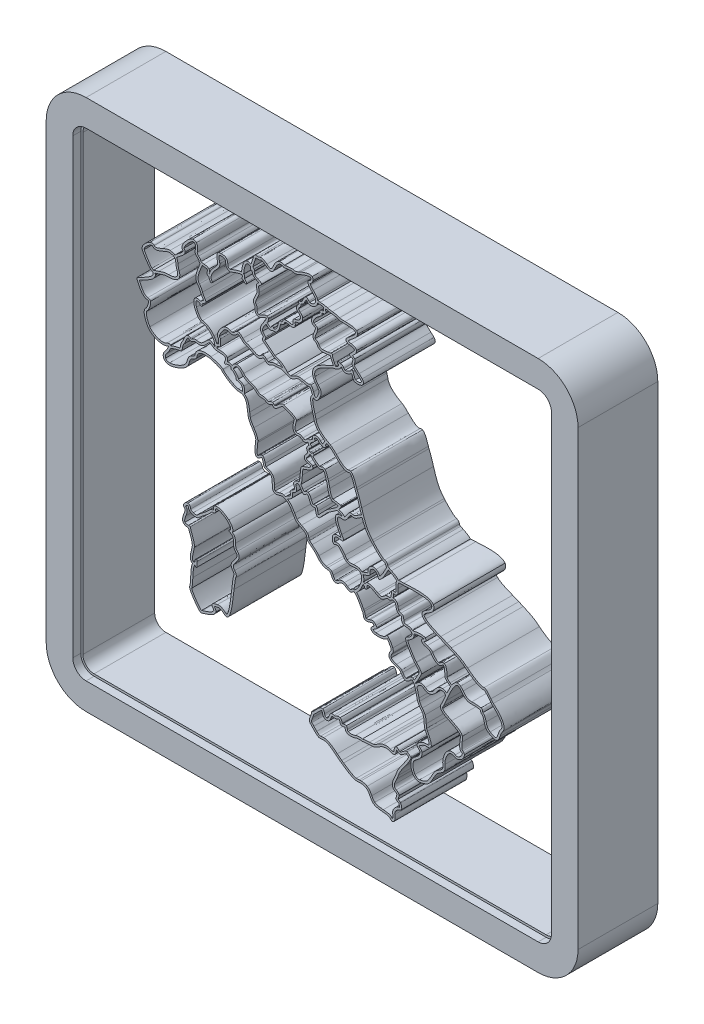
SolidWorks part; units mm, degrees
ref_plane "Piano frontale" through (0, 0, 0) normal (0, 0, 1) x (1, 0, 0)
ref_plane "Piano superiore" through (0, 0, 0) normal (0, 1, 0) x (1, 0, 0)
ref_plane "Piano destro" through (0, 0, 0) normal (1, 0, 0) x (0, 0, -1)
sketch "Sketch1" plane through (0, 0, 0) normal (0, 0, 1) x (1, 0, 0)
  line L5 (-100, -100) -> (100, -100)
  line L6 (-100, -100) -> (-100, 100)
  line L7 (-100, 100) -> (100, 100)
  line L8 (100, -100) -> (100, 100)
  line L9 (-100, -100) -> (100, 100) construction
  line L10 (-100, 100) -> (100, -100) construction
  point P0 (0, 0)
  dimension "D1" = 200
extrude "Boss-Extrude1" add sketch "Sketch1" along normal blind 30
fillet "Fillet1" radius 15 4 edges at (100, -100, 15) (-100, -100, 15) (100, 100, 15) (-100, 100, 15)
sketch "Sketch2" plane through (0, 0, 30) normal (0, 0, 1) x (1, 0, 0)
  line L0 (-85, -90) -> (85, -90)
  line L1 (90, -85) -> (90, 85)
  line L2 (85, 90) -> (-85, 90)
  line L3 (-90, 85) -> (-90, -85)
  line L14 (-85, -100) -> (85, -100)
  line L15 (100, -85) -> (100, 85)
  line L16 (85, 100) -> (-85, 100)
  line L17 (-100, 85) -> (-100, -85)
  line L18 (-85, -100) -> (85, -100) construction
  line L19 (100, -85) -> (100, 85) construction
  line L20 (85, 100) -> (-85, 100) construction
  line L21 (-100, 85) -> (-100, -85) construction
  arc A0 (85, -90) -> (90, -85) centre (85, -85) ccw
  arc A1 (90, 85) -> (85, 90) centre (85, 85) ccw
  arc A2 (-85, 90) -> (-90, 85) centre (-85, 85) ccw
  arc A3 (-90, -85) -> (-85, -90) centre (-85, -85) ccw
  arc A15 (85, -100) -> (100, -85) centre (85, -85) ccw
  arc A16 (100, 85) -> (85, 100) centre (85, 85) ccw
  arc A17 (-85, 100) -> (-100, 85) centre (-85, 85) ccw
  arc A18 (-100, -85) -> (-85, -100) centre (-85, -85) ccw
  arc A19 (85, -100) -> (100, -85) centre (85, -85) ccw construction
  arc A20 (100, 85) -> (85, 100) centre (85, 85) ccw construction
  arc A21 (-85, 100) -> (-100, 85) centre (-85, 85) ccw construction
  arc A22 (-100, -85) -> (-85, -100) centre (-85, -85) ccw construction
  dimension "D1" = 0
  dimension "D2" = 10
extrude "Cut-Extrude2" cut sketch "Sketch2" against normal blind 3
sketch "Sketch3" plane through (0, 0, 27) normal (0, 0, 1) x (1, 0, 0)
  line L4 (-85, -89.2) -> (85, -89.2)
  line L5 (89.2, -85) -> (89.2, 85)
  line L6 (85, 89.2) -> (-85, 89.2)
  line L7 (-89.2, 85) -> (-89.2, -85)
  line L8 (-85, -90) -> (85, -90)
  line L9 (90, -85) -> (90, 85)
  line L10 (85, 90) -> (-85, 90)
  line L11 (-90, 85) -> (-90, -85)
  line L12 (-85, -90) -> (85, -90) construction
  line L13 (90, -85) -> (90, 85) construction
  line L14 (85, 90) -> (-85, 90) construction
  line L15 (-90, 85) -> (-90, -85) construction
  arc A4 (85, -89.2) -> (89.2, -85) centre (85, -85) ccw
  arc A5 (89.2, 85) -> (85, 89.2) centre (85, 85) ccw
  arc A6 (-85, 89.2) -> (-89.2, 85) centre (-85, 85) ccw
  arc A7 (-89.2, -85) -> (-85, -89.2) centre (-85, -85) ccw
  arc A8 (-90, -85) -> (-85, -90) centre (-85, -85) ccw
  arc A9 (85, -90) -> (90, -85) centre (85, -85) ccw
  arc A10 (90, 85) -> (85, 90) centre (85, 85) ccw
  arc A11 (-85, 90) -> (-90, 85) centre (-85, 85) ccw
  arc A12 (-90, -85) -> (-85, -90) centre (-85, -85) ccw construction
  arc A13 (85, -90) -> (90, -85) centre (85, -85) ccw construction
  arc A14 (90, 85) -> (85, 90) centre (85, 85) ccw construction
  arc A15 (-85, 90) -> (-90, 85) centre (-85, 85) ccw construction
  dimension "D1" = 0
  dimension "D2" = 0.8
extrude "Cut-Extrude3" cut sketch "Sketch3" against normal through all
sketch "Sketch4" plane through (0, 0, 27) normal (0, 0, 1) x (1, 0, 0)
  line L0 (-7.0798, 80.5998) -> (-7.2264, 80.5412)
  line L1 (26.8108, -6.7427) -> (26.8091, -6.7834)
  line L2 (16.8679, -9.0158) -> (16.3646, -8.6038)
  line L3 (-28.9005, 67.1274) -> (-28.3121, 66.3918)
  line L4 (-27.6872, 66.8914) -> (-28.3864, 67.7652)
  line L5 (-25.7059, 71.8034) -> (-25.5591, 71.8099)
  line L6 (16.1523, -9.4637) -> (16.7497, -9.9525)
  line L7 (35.5782, -25.2959) -> (35.7222, -25.4517)
  line L8 (36.3082, -24.9073) -> (36.1684, -24.7557)
  line L9 (27.6083, -6.8175) -> (27.61, -6.7772)
  line L10 (-1.8164, -66.6137) -> (-1.757, -66.6681)
  line L11 (-1.2156, -66.0793) -> (-1.275, -66.0245)
  spline S0 degree 3 poles (65.1764, -23.7674) (65.0083, -23.6244) (64.631, -23.1479) (64.2662, -22.6873) knots 0 0 0 0 1 1 1 1
  spline S1 degree 3 poles (64.2662, -22.6873) (62.9543, -21.0292) (62.2698, -20.2561) (61.681, -20.3467) knots 1 1 1 1 2 2 2 2
  spline S2 degree 3 poles (61.681, -20.3467) (60.1207, -20.5858) (56.7776, -18.2011) (55.4909, -17.0746) knots 2 2 2 2 3 3 3 3
  spline S3 degree 3 poles (55.4909, -17.0746) (53.5554, -15.381) (51.5256, -14.5011) (49.3762, -13.5692) knots 3 3 3 3 4 4 4 4
  spline S4 degree 3 poles (49.3762, -13.5692) (48.8336, -13.3339) (48.2792, -13.0938) (47.7122, -12.8343) knots 4 4 4 4 5 5 5 5
  spline S5 degree 3 poles (47.7122, -12.8343) (47.0011, -12.5091) (46.2184, -12.2015) (45.3898, -11.8752) knots 5 5 5 5 6 6 6 6
  spline S6 degree 3 poles (45.3898, -11.8752) (43.3938, -11.0901) (41.1314, -10.1999) (39.723, -8.9335) knots 6 6 6 6 7 7 7 7
  spline S7 degree 3 poles (39.723, -8.9335) (39.3065, -8.559) (39.1077, -8.2317) (39.1318, -7.9613) knots 7 7 7 7 8 8 8 8
  spline S8 degree 3 poles (39.1318, -7.9613) (39.1763, -7.4627) (39.9897, -6.9598) (40.7073, -6.5157) knots 8 8 8 8 9 9 9 9
  spline S9 degree 3 poles (40.7073, -6.5157) (41.4259, -6.0709) (42.1049, -5.651) (42.4219, -5.0853) knots 9 9 9 9 10 10 10 10
  spline S10 degree 3 poles (42.4219, -5.0853) (42.8987, -4.2343) (42.9455, -3.4926) (42.5614, -2.8808) knots 10 10 10 10 11 11 11 11
  spline S11 degree 3 poles (42.5614, -2.8808) (41.3632, -0.9712) (36.2448, -1.1176) (31.5423, -1.4052) knots 11 11 11 11 12 12 12 12
  spline S12 degree 3 poles (31.5423, -1.4052) (30.7282, -1.4548) (30.0878, -1.4945) (29.7725, -1.4838) knots 12 12 12 12 13 13 13 13
  spline S13 degree 3 poles (29.7725, -1.4838) (29.6888, -1.4796) (29.6085, -1.4869) (29.5307, -1.5007) knots 13 13 13 13 14 14 14 14
  spline S14 degree 3 poles (29.5307, -1.5007) (28.7111, -0.6539) (27.7985, -0.2012) (26.8346, 0.2705) knots 14 14 14 14 15 15 15 15
  spline S15 degree 3 poles (26.8346, 0.2705) (26.5131, 0.4279) (26.1841, 0.5886) (25.8496, 0.77) knots 15 15 15 15 16 16 16 16
  spline S16 degree 3 poles (25.8496, 0.77) (25.5647, 0.9236) (25.513, 1.0883) (25.4279, 1.361) knots 16 16 16 16 17 17 17 17
  spline S17 degree 3 poles (25.4279, 1.361) (25.3111, 1.7351) (25.1509, 2.2474) (24.3024, 2.5415) knots 17 17 17 17 18 18 18 18
  spline S18 degree 3 poles (24.3024, 2.5415) (23.0739, 2.9675) (21.1822, 5.0581) (20.0519, 6.3073) knots 18 18 18 18 19 19 19 19
  spline S19 degree 3 poles (20.0519, 6.3073) (19.9147, 6.4589) (19.7876, 6.5991) (19.6736, 6.7236) knots 19 19 19 19 20 20 20 20
  spline S20 degree 3 poles (19.6736, 6.7236) (17.4491, 9.15) (16.5789, 12.0735) (15.6576, 15.1686) knots 20 20 20 20 21 21 21 21
  spline S21 degree 3 poles (15.6576, 15.1686) (15.1708, 16.8042) (14.6675, 18.4955) (13.9461, 20.1152) knots 21 21 21 21 22 22 22 22
  spline S22 degree 3 poles (13.9461, 20.1152) (13.9027, 20.2126) (13.8193, 20.4792) (13.7225, 20.7879) knots 22 22 22 22 23 23 23 23
  spline S23 degree 3 poles (13.7225, 20.7879) (13.1599, 22.5852) (12.4782, 24.5425) (11.5022, 25.0154) knots 23 23 23 23 24 24 24 24
  spline S24 degree 3 poles (11.5022, 25.0154) (11.2276, 25.1485) (10.9358, 25.1635) (10.6605, 25.0581) knots 24 24 24 24 25 25 25 25
  spline S25 degree 3 poles (10.6605, 25.0581) (9.4168, 24.5837) (7.6209, 26.3703) (6.1785, 27.8073) knots 25 25 25 25 26 26 26 26
  spline S26 degree 3 poles (6.1785, 27.8073) (5.2872, 28.6951) (4.5176, 29.462) (3.8399, 29.806) knots 26 26 26 26 27 27 27 27
  spline S27 degree 3 poles (3.8399, 29.806) (2.0323, 30.7241) (-1.0643, 32.6516) (-1.4964, 35.2466) knots 27 27 27 27 28 28 28 28
  spline S28 degree 3 poles (-1.4964, 35.2466) (-1.5599, 35.6285) (-1.7265, 36.2011) (-1.9192, 36.8641) knots 28 28 28 28 29 29 29 29
  spline S29 degree 3 poles (-1.9192, 36.8641) (-2.3873, 38.4731) (-3.1705, 41.1663) (-2.5299, 41.9143) knots 29 29 29 29 30 30 30 30
  spline S30 degree 3 poles (-2.5299, 41.9143) (-2.5025, 41.9461) (-2.4867, 41.983) (-2.471, 42.0195) knots 30 30 30 30 31 31 31 31
  spline S31 degree 3 poles (-2.471, 42.0195) (-2.2715, 41.7687) (-2.0362, 41.6071) (-1.7379, 41.5911) knots 31 31 31 31 32 32 32 32
  spline S32 degree 3 poles (-1.7379, 41.5911) (-1.1744, 41.5641) (-0.6606, 42.0762) (-0.073, 43.2616) knots 32 32 32 32 33 33 33 33
  spline S33 degree 3 poles (-0.073, 43.2616) (0.9085, 45.2427) (0.0956, 46.1681) (-0.6906, 47.0631) knots 33 33 33 33 34 34 34 34
  spline S34 degree 3 poles (-0.6906, 47.0631) (-1.1816, 47.6223) (-1.6895, 48.2005) (-1.9318, 49.1228) knots 34 34 34 34 35 35 35 35
  spline S35 degree 3 poles (-1.9318, 49.1228) (-2.6503, 51.8566) (0.329, 53.1845) (2.9573, 54.356) knots 35 35 35 35 36 36 36 36
  spline S36 degree 3 poles (2.9573, 54.356) (3.699, 54.6868) (4.3984, 55.0003) (4.9765, 55.3293) knots 36 36 36 36 37 37 37 37
  spline S37 degree 3 poles (4.9765, 55.3293) (5.7551, 55.4144) (7.4841, 55.9539) (7.778, 56.9609) knots 37 37 37 37 38 38 38 38
  spline S38 degree 3 poles (7.778, 56.9609) (7.8083, 57.0642) (7.8235, 57.1846) (7.8156, 57.3152) knots 38 38 38 38 39 39 39 39
  spline S39 degree 3 poles (7.8156, 57.3152) (8.0664, 57.2778) (8.1329, 57.1585) (8.2476, 56.9352) knots 39 39 39 39 40 40 40 40
  spline S40 degree 3 poles (8.2476, 56.9352) (8.393, 56.6529) (8.5917, 56.2664) (9.185, 56.1015) knots 40 40 40 40 41 41 41 41
  spline S41 degree 3 poles (9.185, 56.1015) (9.3238, 56.0629) (9.464, 56.0455) (9.6049, 56.0455) knots 41 41 41 41 42 42 42 42
  spline S42 degree 3 poles (9.6049, 56.0455) (10.3301, 56.0457) (11.0681, 56.5054) (11.6803, 56.887) knots 42 42 42 42 43 43 43 43
  spline S43 degree 3 poles (11.6803, 56.887) (11.7402, 56.9244) (11.7964, 56.9586) (11.8539, 56.994) knots 43 43 43 43 44 44 44 44
  spline S44 degree 3 poles (11.8539, 56.994) (12.5677, 55.1553) (12.7152, 55.0199) (12.9322, 54.9348) knots 44 44 44 44 45 45 45 45
  spline S45 degree 3 poles (12.9322, 54.9348) (13.2757, 54.7993) (13.6926, 54.7297) (14.1146, 54.7297) knots 45 45 45 45 46 46 46 46
  spline S46 degree 3 poles (14.1146, 54.7297) (14.9052, 54.7297) (15.7134, 54.9741) (16.0879, 55.4862) knots 46 46 46 46 47 47 47 47
  spline S47 degree 3 poles (16.0879, 55.4862) (16.3015, 55.7782) (16.552, 56.4) (15.8302, 57.2854) knots 47 47 47 47 48 48 48 48
  spline S48 degree 3 poles (15.8302, 57.2854) (15.618, 57.5464) (15.1729, 57.9377) (14.6582, 58.3909) knots 48 48 48 48 49 49 49 49
  spline S49 degree 3 poles (14.6582, 58.3909) (14.0419, 58.9332) (12.9071, 59.9316) (12.7875, 60.2826) knots 49 49 49 49 50 50 50 50
  spline S50 degree 3 poles (12.7875, 60.2826) (12.8406, 60.4707) (12.8926, 60.6408) (12.9395, 60.7951) knots 50 50 50 50 51 51 51 51
  spline S51 degree 3 poles (12.9395, 60.7951) (13.1348, 61.4338) (13.2757, 61.8955) (13.0445, 62.3206) knots 51 51 51 51 52 52 52 52
  spline S52 degree 3 poles (13.0445, 62.3206) (12.8816, 62.6207) (12.5657, 62.8193) (12.1147, 62.9891) knots 52 52 52 52 53 53 53 53
  spline S53 degree 3 poles (12.1147, 62.9891) (12.2001, 63.0723) (12.2928, 63.1593) (12.3872, 63.2482) knots 53 53 53 53 54 54 54 54
  spline S54 degree 3 poles (12.3872, 63.2482) (13.0545, 63.8764) (13.8111, 64.5883) (13.6781, 65.3776) knots 54 54 54 54 55 55 55 55
  spline S55 degree 3 poles (13.6781, 65.3776) (13.5038, 66.4104) (12.4434, 66.5582) (11.6692, 66.6661) knots 55 55 55 55 56 56 56 56
  spline S56 degree 3 poles (11.6692, 66.6661) (11.2007, 66.7313) (10.7174, 66.7987) (10.5579, 67.0026) knots 56 56 56 56 57 57 57 57
  spline S57 degree 3 poles (10.5579, 67.0026) (10.6567, 67.241) (11.3451, 67.7809) (11.8071, 68.1435) knots 57 57 57 57 58 58 58 58
  spline S58 degree 3 poles (11.8071, 68.1435) (12.8571, 68.967) (14.0471, 69.9005) (14.0805, 70.9101) knots 58 58 58 58 59 59 59 59
  spline S59 degree 3 poles (14.0805, 70.9101) (14.0925, 71.2675) (13.9706, 71.5915) (13.728, 71.8475) knots 59 59 59 59 60 60 60 60
  spline S60 degree 3 poles (13.728, 71.8475) (12.9608, 72.6566) (11.0691, 72.6939) (9.4003, 72.727) knots 60 60 60 60 61 61 61 61
  spline S61 degree 3 poles (9.4003, 72.727) (8.5459, 72.7439) (7.5779, 72.763) (7.3171, 72.9129) knots 61 61 61 61 62 62 62 62
  spline S62 degree 3 poles (7.3171, 72.9129) (6.7056, 73.2646) (5.6441, 73.4107) (4.6178, 73.5519) knots 62 62 62 62 63 63 63 63
  spline S63 degree 3 poles (4.6178, 73.5519) (3.9133, 73.6488) (3.2481, 73.7404) (2.7978, 73.8851) knots 63 63 63 63 64 64 64 64
  spline S64 degree 3 poles (2.7978, 73.8851) (1.9282, 74.1647) (0.9963, 74.2623) (0.0949, 74.3569) knots 64 64 64 64 65 65 65 65
  spline S65 degree 3 poles (0.0949, 74.3569) (-0.2272, 74.3907) (-0.5467, 74.4241) (-0.8587, 74.4658) knots 65 65 65 65 66 66 66 66
  spline S66 degree 3 poles (-0.8587, 74.4658) (-0.8723, 74.4675) (-0.8847, 74.4627) (-0.8981, 74.463) knots 66 66 66 66 67 67 67 67
  spline S67 degree 3 poles (-0.8981, 74.463) (-0.9357, 74.6485) (-0.9922, 74.8321) (-1.0771, 75.0101) knots 67 67 67 67 68 68 68 68
  spline S68 degree 3 poles (-1.0771, 75.0101) (-1.4194, 75.7263) (-2.0286, 76.3573) (-2.5662, 76.9142) knots 68 68 68 68 69 69 69 69
  spline S69 degree 3 poles (-2.5662, 76.9142) (-2.9943, 77.3574) (-3.3987, 77.7762) (-3.5968, 78.1563) knots 69 69 69 69 70 70 70 70
  spline S70 degree 3 poles (-3.5968, 78.1563) (-3.7224, 78.397) (-3.771, 78.5306) (-3.7898, 78.5995) knots 70 70 70 70 71 71 71 71
  spline S71 degree 3 poles (-3.7898, 78.5995) (-3.7705, 78.609) (-3.7496, 78.6186) (-3.7317, 78.6271) knots 71 71 71 71 72 72 72 72
  spline S72 degree 3 poles (-3.7317, 78.6271) (-3.4313, 78.7673) (-2.9287, 79.0023) (-2.7168, 79.929) knots 72 72 72 72 73 73 73 73
  spline S73 degree 3 poles (-2.7168, 79.929) (-2.5652, 80.5925) (-2.7933, 80.9532) (-3.0113, 81.1391) knots 73 73 73 73 74 74 74 74
  spline S74 degree 3 poles (-3.0113, 81.1391) (-3.6196, 81.6576) (-4.8743, 81.4912) (-7.0798, 80.5998) knots 74 74 74 74 75 75 75 75
  spline S75 degree 3 poles (-7.2264, 80.5412) (-7.5783, 80.4077) (-7.8675, 80.2719) (-8.1228, 80.1522) knots 76 76 76 76 77 77 77 77
  spline S76 degree 3 poles (-8.1228, 80.1522) (-8.859, 79.8069) (-9.2645, 79.6162) (-10.2445, 79.9171) knots 77 77 77 77 78 78 78 78
  spline S77 degree 3 poles (-10.2445, 79.9171) (-10.6367, 80.0368) (-11.5848, 79.9254) (-13.0905, 79.692) knots 78 78 78 78 79 79 79 79
  spline S78 degree 3 poles (-13.0905, 79.692) (-13.2235, 79.6715) (-13.333, 79.6541) (-13.4085, 79.6432) knots 79 79 79 79 80 80 80 80
  spline S79 degree 3 poles (-13.4085, 79.6432) (-14.0933, 80.0012) (-14.7407, 80.0894) (-15.3334, 79.9054) knots 80 80 80 80 81 81 81 81
  spline S80 degree 3 poles (-15.3334, 79.9054) (-16.5344, 79.5333) (-17.2022, 78.1761) (-17.7389, 77.0854) knots 81 81 81 81 82 82 82 82
  spline S81 degree 3 poles (-17.7389, 77.0854) (-17.8823, 76.7945) (-18.0175, 76.5197) (-18.1417, 76.3118) knots 82 82 82 82 83 83 83 83
  spline S82 degree 3 poles (-18.1417, 76.3118) (-18.3284, 75.9992) (-18.4821, 75.9694) (-18.5327, 75.9596) knots 83 83 83 83 84 84 84 84
  spline S83 degree 3 poles (-18.5327, 75.9596) (-18.8884, 75.89) (-19.4815, 76.3411) (-20.0048, 76.7385) knots 84 84 84 84 85 85 85 85
  spline S84 degree 3 poles (-20.0048, 76.7385) (-20.8483, 77.3788) (-21.8982, 78.1758) (-22.878, 77.5302) knots 85 85 85 85 86 86 86 86
  spline S85 degree 3 poles (-22.878, 77.5302) (-23.0198, 77.4366) (-23.2656, 77.469) (-23.5265, 77.5038) knots 86 86 86 86 87 87 87 87
  spline S86 degree 3 poles (-23.5265, 77.5038) (-23.9632, 77.5617) (-24.7769, 77.6697) (-25.0041, 76.7002) knots 87 87 87 87 88 88 88 88
  spline S87 degree 3 poles (-25.0041, 76.7002) (-25.0295, 76.5933) (-25.1466, 76.2539) (-25.2706, 75.8948) knots 88 88 88 88 89 89 89 89
  spline S88 degree 3 poles (-25.2706, 75.8948) (-25.5884, 74.9748) (-25.8184, 74.2689) (-25.9708, 73.7214) knots 89 89 89 89 90 90 90 90
  spline S89 degree 3 poles (-25.9708, 73.7214) (-26.6488, 74.087) (-27.2645, 74.1328) (-27.8047, 73.8496) knots 90 90 90 90 91 91 91 91
  spline S90 degree 3 poles (-27.8047, 73.8496) (-29.155, 73.1418) (-29.4523, 70.5383) (-29.5176, 69.3674) knots 91 91 91 91 92 92 92 92
  spline S91 degree 3 poles (-29.5176, 69.3674) (-30.4631, 69.4041) (-31.8394, 68.9064) (-33.2092, 68.364) knots 92 92 92 92 93 93 93 93
  spline S92 degree 3 poles (-33.2092, 68.364) (-33.4503, 68.2685) (-33.7194, 68.1619) (-33.8382, 68.1245) knots 93 93 93 93 94 94 94 94
  spline S93 degree 3 poles (-33.8382, 68.1245) (-34.576, 68.3023) (-34.6425, 68.6916) (-34.7086, 69.4614) knots 94 94 94 94 95 95 95 95
  spline S94 degree 3 poles (-34.7086, 69.4614) (-34.7868, 70.3694) (-34.8969, 71.6101) (-37.2671, 71.585) knots 95 95 95 95 96 96 96 96
  spline S95 degree 3 poles (-37.2671, 71.585) (-37.8402, 71.5779) (-38.2678, 71.3995) (-38.5377, 71.0548) knots 96 96 96 96 97 97 97 97
  spline S96 degree 3 poles (-38.5377, 71.0548) (-39.0512, 70.3993) (-38.8167, 69.3963) (-38.6285, 68.5905) knots 97 97 97 97 98 98 98 98
  spline S97 degree 3 poles (-38.6285, 68.5905) (-38.5708, 68.3426) (-38.516, 68.1087) (-38.5056, 67.9635) knots 98 98 98 98 99 99 99 99
  spline S98 degree 3 poles (-38.5056, 67.9635) (-38.4491, 67.1668) (-39.1035, 66.4857) (-39.7364, 65.8272) knots 99 99 99 99 100 100 100 100
  spline S99 degree 3 poles (-39.7364, 65.8272) (-39.9636, 65.5908) (-40.1781, 65.3674) (-40.3622, 65.1371) knots 100 100 100 100 101 101 101 101
  spline S100 degree 3 poles (-40.3622, 65.1371) (-41.174, 64.12) (-41.5742, 63.2664) (-41.7206, 62.5543) knots 101 101 101 101 102 102 102 102
  spline S101 degree 3 poles (-41.7206, 62.5543) (-41.7552, 62.5805) (-41.7663, 62.5967) (-41.7664, 62.5967) knots 102 102 102 102 103 103 103 103
  spline S102 degree 3 poles (-41.7664, 62.5967) (-41.7747, 62.641) (-41.716, 62.7912) (-41.6808, 62.8809) knots 103 103 103 103 104 104 104 104
  spline S103 degree 3 poles (-41.6808, 62.8809) (-41.5585, 63.1936) (-41.3537, 63.7167) (-41.7702, 64.2529) knots 104 104 104 104 105 105 105 105
  spline S104 degree 3 poles (-41.7702, 64.2529) (-42.1688, 64.7659) (-42.9434, 64.8383) (-43.6926, 64.908) knots 105 105 105 105 106 106 106 106
  spline S105 degree 3 poles (-43.6926, 64.908) (-43.9837, 64.9352) (-44.7571, 65.0074) (-44.7816, 65.1456) knots 106 106 106 106 107 107 107 107
  spline S106 degree 3 poles (-44.7816, 65.1456) (-44.8944, 65.7826) (-45.3259, 66.187) (-45.6728, 66.5121) knots 107 107 107 107 108 108 108 108
  spline S107 degree 3 poles (-45.6728, 66.5121) (-46.0942, 66.9069) (-46.2921, 67.1146) (-46.1872, 67.5142) knots 108 108 108 108 109 109 109 109
  spline S108 degree 3 poles (-46.1872, 67.5142) (-46.1338, 67.7168) (-45.6892, 69.52) (-46.5141, 70.4536) knots 109 109 109 109 110 110 110 110
  spline S109 degree 3 poles (-46.5141, 70.4536) (-46.7479, 70.7182) (-47.1814, 71.0126) (-47.9249, 70.9123) knots 110 110 110 110 111 111 111 111
  spline S110 degree 3 poles (-47.9249, 70.9123) (-49.1756, 70.7433) (-51.4802, 68.0496) (-51.9096, 66.7698) knots 111 111 111 111 112 112 112 112
  spline S111 degree 3 poles (-51.9096, 66.7698) (-52.0611, 66.319) (-52.0206, 65.9741) (-51.7894, 65.7445) knots 112 112 112 112 113 113 113 113
  spline S112 degree 3 poles (-51.7894, 65.7445) (-51.5836, 65.5402) (-51.5689, 65.3884) (-51.5758, 65.292) knots 113 113 113 113 114 114 114 114
  spline S113 degree 3 poles (-51.5758, 65.292) (-51.6154, 64.7363) (-52.5999, 64.004) (-53.3187, 63.4694) knots 114 114 114 114 115 115 115 115
  spline S114 degree 3 poles (-53.3187, 63.4694) (-53.8618, 63.0654) (-54.3095, 62.7294) (-54.5436, 62.3935) knots 115 115 115 115 116 116 116 116
  spline S115 degree 3 poles (-54.5436, 62.3935) (-54.9653, 62.646) (-55.5587, 62.8422) (-56.4138, 62.9812) knots 116 116 116 116 117 117 117 117
  spline S116 degree 3 poles (-56.4138, 62.9812) (-57.1369, 63.0983) (-58.1463, 62.6586) (-59.2148, 62.1929) knots 117 117 117 117 118 118 118 118
  spline S117 degree 3 poles (-59.2148, 62.1929) (-60.496, 61.6347) (-61.948, 61.0018) (-62.3789, 61.6166) knots 118 118 118 118 119 119 119 119
  spline S118 degree 3 poles (-62.3789, 61.6166) (-62.5565, 61.87) (-63.0037, 62.2312) (-64.0073, 61.8069) knots 119 119 119 119 120 120 120 120
  spline S119 degree 3 poles (-64.0073, 61.8069) (-65.3174, 61.2524) (-67.1621, 59.4815) (-66.9287, 58.2647) knots 120 120 120 120 121 121 121 121
  spline S120 degree 3 poles (-66.9287, 58.2647) (-66.7685, 57.4287) (-64.2753, 53.4374) (-63.5749, 53.0812) knots 121 121 121 121 122 122 122 122
  spline S121 degree 3 poles (-63.5749, 53.0812) (-63.0192, 52.7992) (-62.7391, 52.5003) (-62.7426, 52.1927) knots 122 122 122 122 123 123 123 123
  spline S122 degree 3 poles (-62.7426, 52.1927) (-62.7562, 50.9621) (-66.3768, 49.2241) (-67.7397, 48.5697) knots 123 123 123 123 124 124 124 124
  spline S123 degree 3 poles (-67.7397, 48.5697) (-68.6878, 48.1146) (-68.8333, 48.0446) (-68.9091, 47.8272) knots 124 124 124 124 125 125 125 125
  spline S124 degree 3 poles (-68.9091, 47.8272) (-68.9441, 47.7265) (-68.9374, 47.6064) (-68.8905, 47.5105) knots 125 125 125 125 126 126 126 126
  spline S125 degree 3 poles (-68.8905, 47.5105) (-68.7665, 47.2573) (-68.6397, 46.9717) (-68.5055, 46.67) knots 126 126 126 126 127 127 127 127
  spline S126 degree 3 poles (-68.5055, 46.67) (-67.775, 45.0274) (-66.7745, 42.7776) (-64.8148, 42.6488) knots 127 127 127 127 128 128 128 128
  spline S127 degree 3 poles (-64.8148, 42.6488) (-64.6412, 42.6372) (-64.5888, 42.5778) (-64.553, 42.4724) knots 128 128 128 128 129 129 129 129
  spline S128 degree 3 poles (-64.553, 42.4724) (-64.3134, 41.7661) (-65.1998, 39.9399) (-65.4899, 39.6853) knots 129 129 129 129 130 130 130 130
  spline S129 degree 3 poles (-65.4899, 39.6853) (-66.9558, 38.4254) (-65.6442, 35.5322) (-64.7316, 33.9196) knots 130 130 130 130 131 131 131 131
  spline S130 degree 3 poles (-64.7316, 33.9196) (-64.0936, 32.7934) (-62.4921, 31.7185) (-60.7467, 31.245) knots 131 131 131 131 132 132 132 132
  spline S131 degree 3 poles (-60.7467, 31.245) (-59.3681, 30.871) (-58.1294, 30.943) (-57.2583, 31.4482) knots 132 132 132 132 133 133 133 133
  spline S132 degree 3 poles (-57.2583, 31.4482) (-57.1303, 31.5226) (-57.0339, 31.5692) (-56.9629, 31.5983) knots 133 133 133 133 134 134 134 134
  spline S133 degree 3 poles (-56.9629, 31.5983) (-57.0833, 31.0731) (-57.7574, 29.8557) (-58.0421, 29.575) knots 134 134 134 134 135 135 135 135
  spline S134 degree 3 poles (-58.0421, 29.575) (-58.8942, 28.7349) (-59.2105, 27.6293) (-58.8476, 26.7582) knots 135 135 135 135 136 136 136 136
  spline S135 degree 3 poles (-58.8476, 26.7582) (-58.5111, 25.9502) (-57.6704, 25.502) (-56.5199, 25.5068) knots 136 136 136 136 137 137 137 137
  spline S136 degree 3 poles (-56.5199, 25.5068) (-54.6328, 25.5278) (-51.2532, 26.8656) (-49.9992, 28.3971) knots 137 137 137 137 138 138 138 138
  spline S137 degree 3 poles (-49.9992, 28.3971) (-49.5219, 28.9803) (-49.3382, 29.5998) (-49.1761, 30.1463) knots 138 138 138 138 139 139 139 139
  spline S138 degree 3 poles (-49.1761, 30.1463) (-49.0404, 30.6038) (-48.9124, 31.036) (-48.6292, 31.4152) knots 139 139 139 139 140 140 140 140
  spline S139 degree 3 poles (-48.6292, 31.4152) (-48.4046, 31.7157) (-48.0973, 31.8449) (-47.7414, 31.9944) knots 140 140 140 140 141 141 141 141
  spline S140 degree 3 poles (-47.7414, 31.9944) (-47.1761, 32.232) (-46.4724, 32.5276) (-46.25, 33.6236) knots 141 141 141 141 142 142 142 142
  spline S141 degree 3 poles (-46.25, 33.6236) (-45.823, 35.7239) (-43.448, 35.644) (-41.1809, 35.2893) knots 142 142 142 142 143 143 143 143
  spline S142 degree 3 poles (-41.1809, 35.2893) (-40.5817, 35.1955) (-37.648, 34.1192) (-37.1569, 33.8517) knots 143 143 143 143 144 144 144 144
  spline S143 degree 3 poles (-37.1569, 33.8517) (-36.3168, 32.4425) (-32.2387, 29.967) (-30.7228, 29.967) knots 144 144 144 144 145 145 145 145
  spline S144 degree 3 poles (-30.7228, 29.967) (-30.7154, 29.967) (-30.7082, 29.967) (-30.7009, 29.9672) knots 145 145 145 145 146 146 146 146
  spline S145 degree 3 poles (-30.7009, 29.9672) (-28.041, 30.0099) (-27.6209, 28.1173) (-27.2715, 25.2241) knots 146 146 146 146 147 147 147 147
  spline S146 degree 3 poles (-27.2715, 25.2241) (-27.1995, 24.6283) (-27.1317, 24.0654) (-27.0231, 23.5472) knots 147 147 147 147 148 148 148 148
  spline S147 degree 3 poles (-27.0231, 23.5472) (-26.8013, 22.4874) (-26.172, 21.5002) (-25.5635, 20.5457) knots 148 148 148 148 149 149 149 149
  spline S148 degree 3 poles (-25.5635, 20.5457) (-24.8799, 19.4736) (-24.2343, 18.4609) (-24.1778, 17.4448) knots 149 149 149 149 150 150 150 150
  spline S149 degree 3 poles (-24.1778, 17.4448) (-24.1804, 17.3848) (-24.203, 17.2319) (-24.2331, 17.0157) knots 150 150 150 150 151 151 151 151
  spline S150 degree 3 poles (-24.2331, 17.0157) (-24.6076, 14.3244) (-24.6813, 12.4415) (-23.8238, 12.001) knots 151 151 151 151 152 152 152 152
  spline S151 degree 3 poles (-23.8238, 12.001) (-23.1934, 11.6768) (-22.525, 12.3124) (-22.3056, 12.5212) knots 152 152 152 152 153 153 153 153
  spline S152 degree 3 poles (-22.3056, 12.5212) (-22.0805, 12.7346) (-21.9616, 12.7574) (-21.9406, 12.7507) knots 153 153 153 153 154 154 154 154
  spline S153 degree 3 poles (-21.9406, 12.7507) (-21.7287, 12.6878) (-21.5038, 11.7488) (-21.4078, 11.3476) knots 154 154 154 154 155 155 155 155
  spline S154 degree 3 poles (-21.4078, 11.3476) (-21.2173, 10.5522) (-21.0667, 9.9238) (-20.5812, 9.8048) knots 155 155 155 155 156 156 156 156
  spline S155 degree 3 poles (-20.5812, 9.8048) (-18.0716, 9.1852) (-18.0423, 8.1077) (-17.9889, 6.1519) knots 156 156 156 156 157 157 157 157
  spline S156 degree 3 poles (-17.9889, 6.1519) (-17.9806, 5.8438) (-17.9717, 5.5204) (-17.9522, 5.1826) knots 157 157 157 157 158 158 158 158
  spline S157 degree 3 poles (-17.9522, 5.1826) (-17.9122, 4.4879) (-17.7081, 4.0213) (-17.3283, 3.7555) knots 158 158 158 158 159 159 159 159
  spline S158 degree 3 poles (-17.3283, 3.7555) (-16.7244, 3.3333) (-15.8877, 3.5853) (-15.15, 3.8079) knots 159 159 159 159 160 160 160 160
  spline S159 degree 3 poles (-15.15, 3.8079) (-14.6856, 3.9479) (-14.1595, 4.1062) (-13.9037, 4.0149) knots 160 160 160 160 161 161 161 161
  spline S160 degree 3 poles (-13.9037, 4.0149) (-11.8473, 3.2775) (-11.1495, 2.025) (-10.2662, 0.4393) knots 161 161 161 161 162 162 162 162
  spline S161 degree 3 poles (-10.2662, 0.4393) (-9.9896, -0.0572) (-9.7036, -0.5708) (-9.3544, -1.1103) knots 162 162 162 162 163 163 163 163
  spline S162 degree 3 poles (-9.3544, -1.1103) (-8.9965, -1.664) (-8.1919, -2.0753) (-7.3399, -2.5104) knots 163 163 163 163 164 164 164 164
  spline S163 degree 3 poles (-7.3399, -2.5104) (-6.5681, -2.9049) (-5.7698, -3.3128) (-5.3339, -3.8061) knots 164 164 164 164 165 165 165 165
  spline S164 degree 3 poles (-5.3339, -3.8061) (-5.1826, -3.9773) (-5.0958, -4.3691) (-5.019, -4.7149) knots 165 165 165 165 166 166 166 166
  spline S165 degree 3 poles (-5.019, -4.7149) (-4.9101, -5.2055) (-4.8073, -5.6692) (-4.4884, -5.9348) knots 166 166 166 166 167 167 167 167
  spline S166 degree 3 poles (-4.4884, -5.9348) (-4.1262, -6.2366) (-3.7903, -6.4954) (-3.4654, -6.7458) knots 167 167 167 167 168 168 168 168
  spline S167 degree 3 poles (-3.4654, -6.7458) (-2.6184, -7.3983) (-1.8869, -7.9619) (-1.1038, -8.9786) knots 168 168 168 168 169 169 169 169
  spline S168 degree 3 poles (-1.1038, -8.9786) (-0.0499, -10.3463) (0.5102, -10.7504) (2.0502, -11.2524) knots 169 169 169 169 170 170 170 170
  spline S169 degree 3 poles (2.0502, -11.2524) (2.4026, -11.3671) (2.6848, -11.3833) (2.9118, -11.3964) knots 170 170 170 170 171 171 171 171
  spline S170 degree 3 poles (2.9118, -11.3964) (3.2598, -11.4163) (3.4699, -11.4284) (3.8585, -11.795) knots 171 171 171 171 172 172 172 172
  spline S171 degree 3 poles (3.8585, -11.795) (3.9398, -11.8714) (4.0869, -12.2011) (4.1944, -12.4416) knots 172 172 172 172 173 173 173 173
  spline S172 degree 3 poles (4.1944, -12.4416) (4.542, -13.2205) (5.0647, -14.3957) (6.1044, -14.1225) knots 173 173 173 173 174 174 174 174
  spline S173 degree 3 poles (6.1044, -14.1225) (6.6277, -13.984) (6.9949, -13.7273) (7.3188, -13.501) knots 174 174 174 174 175 175 175 175
  spline S174 degree 3 poles (7.3188, -13.501) (7.82, -13.1513) (8.1504, -12.9187) (8.9259, -13.1726) knots 175 175 175 175 176 176 176 176
  spline S175 degree 3 poles (8.9259, -13.1726) (9.2277, -13.2708) (9.5292, -13.4817) (9.8206, -13.6856) knots 176 176 176 176 177 177 177 177
  spline S176 degree 3 poles (9.8206, -13.6856) (10.5172, -14.1724) (11.4718, -14.8404) (12.5808, -13.6856) knots 177 177 177 177 178 178 178 178
  spline S177 degree 3 poles (12.5808, -13.6856) (12.6373, -13.6267) (12.67, -13.626) (12.7073, -13.6322) knots 178 178 178 178 179 179 179 179
  spline S178 degree 3 poles (12.7073, -13.6322) (13.1014, -13.6904) (13.9382, -14.4828) (15.6866, -17.9269) knots 179 179 179 179 180 180 180 180
  spline S179 degree 3 poles (15.6866, -17.9269) (15.8003, -18.1508) (15.8867, -18.3207) (15.9384, -18.4123) knots 180 180 180 180 181 181 181 181
  spline S180 degree 3 poles (15.9384, -18.4123) (16.1313, -18.7537) (16.1964, -19.1058) (16.2598, -19.4465) knots 181 181 181 181 182 182 182 182
  spline S181 degree 3 poles (16.2598, -19.4465) (16.3422, -19.892) (16.4276, -20.3529) (16.8369, -20.6068) knots 182 182 182 182 183 183 183 183
  spline S182 degree 3 poles (16.8369, -20.6068) (17.2007, -20.8325) (17.7033, -20.8308) (18.5188, -20.5989) knots 183 183 183 183 184 184 184 184
  spline S183 degree 3 poles (18.5188, -20.5989) (18.7048, -20.5458) (18.8671, -20.4973) (19.0101, -20.4545) knots 184 184 184 184 185 185 185 185
  spline S184 degree 3 poles (19.0101, -20.4545) (19.3914, -20.3405) (19.6684, -20.2571) (19.7694, -20.2923) knots 185 185 185 185 186 186 186 186
  spline S185 degree 3 poles (19.7694, -20.2923) (19.883, -20.3305) (20.0863, -20.5803) (20.3678, -20.9258) knots 186 186 186 186 187 187 187 187
  spline S186 degree 3 poles (20.3678, -20.9258) (20.3788, -20.9393) (20.3898, -20.9531) (20.4012, -20.9668) knots 187 187 187 187 188 188 188 188
  spline S187 degree 3 poles (20.4012, -20.9668) (19.7253, -21.3527) (19.0562, -21.8825) (19.1647, -22.5378) knots 188 188 188 188 189 189 189 189
  spline S188 degree 3 poles (19.1647, -22.5378) (19.2571, -23.0959) (19.8755, -23.4687) (20.9531, -23.6161) knots 189 189 189 189 190 190 190 190
  spline S189 degree 3 poles (20.9531, -23.6161) (22.2987, -23.7994) (24.4609, -23.5817) (25.2443, -22.5909) knots 190 190 190 190 191 191 191 191
  spline S190 degree 3 poles (25.2443, -22.5909) (25.6687, -23.099) (26.4484, -24.5697) (26.5851, -24.9022) knots 191 191 191 191 192 192 192 192
  spline S191 degree 3 poles (26.5851, -24.9022) (26.8256, -25.545) (26.7557, -25.6508) (26.5238, -26.0012) knots 192 192 192 192 193 193 193 193
  spline S192 degree 3 poles (26.5238, -26.0012) (26.3984, -26.1906) (26.242, -26.4266) (26.0959, -26.7822) knots 193 193 193 193 194 194 194 194
  spline S193 degree 3 poles (26.0959, -26.7822) (25.8462, -27.3895) (25.8255, -27.9307) (26.0339, -28.391) knots 194 194 194 194 195 195 195 195
  spline S194 degree 3 poles (26.0339, -28.391) (26.4246, -29.253) (27.4846, -29.6164) (28.5099, -29.9675) knots 195 195 195 195 196 196 196 196
  spline S195 degree 3 poles (28.5099, -29.9675) (29.1338, -30.1814) (29.7787, -30.4026) (30.0898, -30.7003) knots 196 196 196 196 197 197 197 197
  spline S196 degree 3 poles (30.0898, -30.7003) (30.1587, -30.7664) (30.2834, -30.9604) (30.4037, -31.1481) knots 197 197 197 197 198 198 198 198
  spline S197 degree 3 poles (30.4037, -31.1481) (30.8247, -31.8034) (31.4014, -32.7012) (32.2819, -32.7559) knots 198 198 198 198 199 199 199 199
  spline S198 degree 3 poles (32.2819, -32.7559) (32.8135, -32.7921) (33.3227, -32.5051) (33.816, -31.914) knots 199 199 199 199 200 200 200 200
  spline S199 degree 3 poles (33.816, -31.914) (34.0279, -31.6601) (34.3366, -31.371) (34.5902, -31.4358) knots 200 200 200 200 201 201 201 201
  spline S200 degree 3 poles (34.5902, -31.4358) (35.4855, -31.6614) (36.1563, -34.925) (36.4088, -36.1535) knots 201 201 201 201 202 202 202 202
  spline S201 degree 3 poles (36.4088, -36.1535) (36.5105, -36.6486) (36.5842, -37.0065) (36.65, -37.2025) knots 202 202 202 202 203 203 203 203
  spline S202 degree 3 poles (36.65, -37.2025) (36.9084, -37.9715) (37.3548, -38.5578) (37.7865, -39.1249) knots 203 203 203 203 204 204 204 204
  spline S203 degree 3 poles (37.7865, -39.1249) (38.1589, -39.6138) (38.5103, -40.0757) (38.7291, -40.6325) knots 204 204 204 204 205 205 205 205
  spline S204 degree 3 poles (38.7291, -40.6325) (39.024, -41.3832) (39.0674, -42.1872) (39.1132, -43.0385) knots 205 205 205 205 206 206 206 206
  spline S205 degree 3 poles (39.1132, -43.0385) (39.1404, -43.5401) (39.1683, -44.059) (39.2521, -44.5695) knots 206 206 206 206 207 207 207 207
  spline S206 degree 3 poles (39.2521, -44.5695) (39.2807, -44.7421) (39.4033, -44.9926) (39.7034, -45.592) knots 207 207 207 207 208 208 208 208
  spline S207 degree 3 poles (39.7034, -45.592) (40.145, -46.4743) (41.3177, -48.8187) (40.947, -49.4237) knots 208 208 208 208 209 209 209 209
  spline S208 degree 3 poles (40.947, -49.4237) (40.9281, -49.4543) (40.8785, -49.5356) (40.6373, -49.5374) knots 209 209 209 209 210 210 210 210
  spline S209 degree 3 poles (40.6373, -49.5374) (40.4737, -49.5387) (40.329, -49.538) (40.1974, -49.538) knots 210 210 210 210 211 211 211 211
  spline S210 degree 3 poles (40.1974, -49.538) (39.0502, -49.5232) (38.84, -49.569) (37.3352, -50.462) knots 211 211 211 211 212 212 212 212
  spline S211 degree 3 poles (37.3352, -50.462) (36.9838, -50.6708) (36.5098, -51.0046) (36.4533, -51.4914) knots 212 212 212 212 213 213 213 213
  spline S212 degree 3 poles (36.4533, -51.4914) (36.3975, -51.9692) (36.7502, -52.3096) (37.0617, -52.6097) knots 213 213 213 213 214 214 214 214
  spline S213 degree 3 poles (37.0617, -52.6097) (37.2863, -52.8267) (37.5188, -53.051) (37.5274, -53.2512) knots 214 214 214 214 215 215 215 215
  spline S214 degree 3 poles (37.5274, -53.2512) (37.5829, -54.5762) (36.8312, -55.1277) (35.9606, -55.7661) knots 215 215 215 215 216 216 216 216
  spline S215 degree 3 poles (35.9606, -55.7661) (35.4208, -56.1623) (34.8623, -56.5715) (34.5099, -57.1872) knots 216 216 216 216 217 217 217 217
  spline S216 degree 3 poles (34.5099, -57.1872) (33.8054, -58.4167) (34.0427, -60.6454) (35.028, -62.0541) knots 217 217 217 217 218 218 218 218
  spline S217 degree 3 poles (35.028, -62.0541) (35.5972, -62.8675) (36.3496, -63.2991) (37.1802, -63.2988) knots 218 218 218 218 219 219 219 219
  spline S218 degree 3 poles (37.1802, -63.2988) (37.32, -63.2988) (37.4623, -63.2867) (37.606, -63.2619) knots 219 219 219 219 220 220 220 220
  spline S219 degree 3 poles (37.606, -63.2619) (40.7948, -62.7128) (41.3518, -61.6693) (42.2741, -59.9398) knots 220 220 220 220 221 221 221 221
  spline S220 degree 3 poles (42.2741, -59.9398) (42.6072, -59.3152) (42.9852, -58.6069) (43.5633, -57.7663) knots 221 221 221 221 222 222 222 222
  spline S221 degree 3 poles (43.5633, -57.7663) (44.048, -57.059) (44.6409, -56.7001) (45.2145, -56.3528) knots 222 222 222 222 223 223 223 223
  spline S222 degree 3 poles (45.2145, -56.3528) (46.2663, -55.7154) (47.2602, -55.1136) (46.9377, -52.7558) knots 223 223 223 223 224 224 224 224
  spline S223 degree 3 poles (46.9377, -52.7558) (46.7972, -51.7271) (47.449, -49.1443) (48.7109, -48.3147) knots 224 224 224 224 225 225 225 225
  spline S224 degree 3 poles (48.7109, -48.3147) (49.2394, -47.9678) (49.8006, -47.9826) (50.4283, -48.3619) knots 225 225 225 225 226 226 226 226
  spline S225 degree 3 poles (50.4283, -48.3619) (51.1445, -48.7942) (51.9686, -48.7729) (52.7499, -48.3019) knots 226 226 226 226 227 227 227 227
  spline S226 degree 3 poles (52.7499, -48.3019) (53.6446, -47.7628) (54.3106, -46.7189) (54.2658, -45.9255) knots 227 227 227 227 228 228 228 228
  spline S227 degree 3 poles (54.2658, -45.9255) (54.2427, -45.5152) (54.0363, -45.2007) (53.6846, -45.0398) knots 228 228 228 228 229 229 229 229
  spline S228 degree 3 poles (53.6846, -45.0398) (53.091, -44.7683) (53.2826, -43.279) (53.4228, -42.1914) knots 229 229 229 229 230 230 230 230
  spline S229 degree 3 poles (53.4228, -42.1914) (53.5216, -41.4242) (53.6067, -40.7613) (53.4979, -40.3135) knots 230 230 230 230 231 231 231 231
  spline S230 degree 3 poles (53.4979, -40.3135) (53.1809, -39.0095) (51.3836, -38.1492) (49.4805, -37.2384) knots 231 231 231 231 232 232 232 232
  spline S231 degree 3 poles (49.4805, -37.2384) (47.9802, -36.5204) (46.2797, -35.7063) (46.0795, -34.8699) knots 232 232 232 232 233 233 233 233
  spline S232 degree 3 poles (46.0795, -34.8699) (46.0189, -34.6173) (46.1019, -34.3479) (46.3335, -34.0461) knots 233 233 233 233 234 234 234 234
  spline S233 degree 3 poles (46.3335, -34.0461) (46.5708, -33.7368) (46.8888, -32.9892) (47.4307, -31.6942) knots 234 234 234 234 235 235 235 235
  spline S234 degree 3 poles (47.4307, -31.6942) (48.4129, -29.3463) (50.2412, -24.9762) (51.6668, -24.6689) knots 235 235 235 235 236 236 236 236
  spline S235 degree 3 poles (51.6668, -24.6689) (51.8036, -24.6407) (52.0192, -24.6293) (52.2942, -24.8853) knots 236 236 236 236 237 237 237 237
  spline S236 degree 3 poles (52.2942, -24.8853) (52.6001, -25.1705) (52.8753, -25.5185) (53.1668, -25.8871) knots 237 237 237 237 238 238 238 238
  spline S237 degree 3 poles (53.1668, -25.8871) (54.0336, -26.9823) (55.011, -28.2225) (57.1166, -28.0847) knots 238 238 238 238 239 239 239 239
  spline S238 degree 3 poles (57.1166, -28.0847) (58.0585, -28.021) (59.1089, -28.1002) (60.3285, -28.3242) knots 239 239 239 239 240 240 240 240
  spline S239 degree 3 poles (60.3285, -28.3242) (60.3639, -28.3993) (60.3798, -28.5974) (60.3877, -28.6969) knots 240 240 240 240 241 241 241 241
  spline S240 degree 3 poles (60.3877, -28.6969) (60.408, -28.9522) (60.4291, -29.2165) (60.6613, -29.366) knots 241 241 241 241 242 242 242 242
  spline S241 degree 3 poles (60.6613, -29.366) (61.32, -29.7856) (61.4822, -30.4922) (61.6703, -31.3107) knots 242 242 242 242 243 243 243 243
  spline S242 degree 3 poles (61.6703, -31.3107) (61.9098, -32.3515) (62.1809, -33.5314) (63.5255, -34.3441) knots 243 243 243 243 244 244 244 244
  spline S243 degree 3 poles (63.5255, -34.3441) (64.8646, -35.1534) (65.7138, -35.3976) (66.366, -35.1658) knots 244 244 244 244 245 245 245 245
  spline S244 degree 3 poles (66.366, -35.1658) (67.0753, -34.9115) (67.3358, -34.1746) (67.6369, -33.3213) knots 245 245 245 245 246 246 246 246
  spline S245 degree 3 poles (67.6369, -33.3213) (67.8749, -32.6474) (68.1447, -31.884) (68.6808, -31.1974) knots 246 246 246 246 247 247 247 247
  spline S246 degree 3 poles (68.6808, -31.1974) (70.568, -28.7796) (66.859, -25.196) (65.1764, -23.7674) knots 247 247 247 247 248 248 248 248
  spline S247 degree 3 poles (26.4832, -0.4482) (27.3765, -0.8854) (28.1609, -1.2716) (28.8579, -1.9551) knots 0 0 0 0 1 1 1 1
  spline S248 degree 3 poles (28.8579, -1.9551) (28.5175, -2.477) (28.5254, -3.331) (28.5347, -4.2309) knots 1 1 1 1 2 2 2 2
  spline S249 degree 3 poles (28.5347, -4.2309) (28.5419, -4.8951) (28.5526, -5.8987) (28.3056, -6.0606) knots 2 2 2 2 3 3 3 3
  spline S250 degree 3 poles (28.3056, -6.0606) (28.2543, -6.0751) (28.0793, -6.0265) (27.9859, -6.0003) knots 3 3 3 3 4 4 4 4
  spline S251 degree 3 poles (27.9859, -6.0003) (27.7251, -5.9273) (27.4009, -5.8363) (27.1188, -6.0413) knots 4 4 4 4 5 5 5 5
  spline S252 degree 3 poles (27.1188, -6.0413) (26.8318, -6.249) (26.816, -6.6208) (26.8108, -6.7427) knots 5 5 5 5 6 6 6 6
  spline S253 degree 3 poles (26.8091, -6.7834) (26.7839, -7.3752) (26.7415, -8.3657) (26.3378, -8.6785) knots 7 7 7 7 8 8 8 8
  spline S254 degree 3 poles (26.3378, -8.6785) (26.2858, -8.7188) (26.1287, -8.8415) (25.7294, -8.7564) knots 8 8 8 8 9 9 9 9
  spline S255 degree 3 poles (25.7294, -8.7564) (24.9391, -8.5886) (24.4051, -9.044) (23.9762, -9.4092) knots 9 9 9 9 10 10 10 10
  spline S256 degree 3 poles (23.9762, -9.4092) (23.4215, -9.8809) (23.0215, -10.2219) (22.0862, -9.7231) knots 10 10 10 10 11 11 11 11
  spline S257 degree 3 poles (22.0862, -9.7231) (21.9604, -9.6559) (21.8051, -9.5674) (21.6287, -9.4668) knots 11 11 11 11 12 12 12 12
  spline S258 degree 3 poles (21.6287, -9.4668) (20.0115, -8.5438) (18.3503, -7.6974) (17.3747, -8.3337) knots 12 12 12 12 13 13 13 13
  spline S259 degree 3 poles (17.3747, -8.3337) (17.137, -8.489) (16.9688, -8.7181) (16.8679, -9.0158) knots 13 13 13 13 14 14 14 14
  spline S260 degree 3 poles (16.3646, -8.6038) (16.387, -8.4756) (16.4049, -8.3481) (16.418, -8.2217) knots 15 15 15 15 16 16 16 16
  spline S261 degree 3 poles (16.418, -8.2217) (16.4917, -7.5082) (16.4028, -6.8729) (16.1675, -6.3417) knots 16 16 16 16 17 17 17 17
  spline S262 degree 3 poles (16.1675, -6.3417) (16.2812, -6.3024) (16.4193, -6.2563) (16.5568, -6.2105) knots 17 17 17 17 18 18 18 18
  spline S263 degree 3 poles (16.5568, -6.2105) (17.9238, -5.7554) (18.4068, -5.559) (18.5732, -5.2947) knots 18 18 18 18 19 19 19 19
  spline S264 degree 3 poles (18.5732, -5.2947) (18.8254, -4.8944) (18.8251, -4.4914) (18.8247, -4.1355) knots 19 19 19 19 20 20 20 20
  spline S265 degree 3 poles (18.8247, -4.1355) (18.8244, -3.5977) (18.824, -3.2422) (19.6047, -2.8343) knots 20 20 20 20 21 21 21 21
  spline S266 degree 3 poles (19.6047, -2.8343) (19.965, -2.6458) (20.3337, -2.6482) (20.7016, -2.8418) knots 21 21 21 21 22 22 22 22
  spline S267 degree 3 poles (20.7016, -2.8418) (21.3303, -3.1722) (21.7782, -3.9625) (21.8478, -4.5354) knots 22 22 22 22 23 23 23 23
  spline S268 degree 3 poles (21.8478, -4.5354) (21.8747, -4.7546) (22.0721, -4.9072) (22.2932, -4.8844) knots 23 23 23 23 24 24 24 24
  spline S269 degree 3 poles (22.2932, -4.8844) (22.4617, -4.8638) (22.5909, -4.7408) (22.6305, -4.5857) knots 24 24 24 24 25 25 25 25
  spline S270 degree 3 poles (22.6305, -4.5857) (23.6906, -3.8354) (24.4257, -2.4002) (25.0738, -1.1258) knots 25 25 25 25 26 26 26 26
  spline S271 degree 3 poles (25.0738, -1.1258) (25.2743, -0.7317) (25.4651, -0.3593) (25.6525, -0.0293) knots 26 26 26 26 27 27 27 27
  spline S272 degree 3 poles (25.6525, -0.0293) (25.935, -0.1774) (26.2134, -0.3162) (26.4832, -0.4482) knots 27 27 27 27 28 28 28 28
  spline S273 degree 3 poles (19.0838, 6.1831) (19.1971, 6.0596) (19.3225, 5.9208) (19.4586, 5.7706) knots 28 28 28 28 29 29 29 29
  spline S274 degree 3 poles (15.8058, 12.0377) (16.533, 9.9589) (17.4787, 7.9339) (19.0838, 6.1831) knots 27 27 27 27 28 28 28 28
  spline S275 degree 3 poles (14.6103, 11.3587) (15.0244, 11.6398) (15.4506, 11.9283) (15.8058, 12.0377) knots 26 26 26 26 27 27 27 27
  spline S276 degree 3 poles (12.01, 10.623) (12.8702, 10.1763) (13.7938, 10.8047) (14.6103, 11.3587) knots 25 25 25 25 26 26 26 26
  spline S277 degree 3 poles (10.6936, 9.5974) (11.312, 10.6009) (11.5604, 10.8569) (12.01, 10.623) knots 24 24 24 24 25 25 25 25
  spline S278 degree 3 poles (8.2848, 7.8855) (9.5071, 7.6722) (10.1655, 8.7402) (10.6936, 9.5974) knots 23 23 23 23 24 24 24 24
  spline S279 degree 3 poles (6.6704, 7.6392) (6.9505, 8.0249) (7.7026, 7.9863) (8.2848, 7.8855) knots 22 22 22 22 23 23 23 23
  spline S280 degree 3 poles (8.1577, 2.7561) (7.4187, 4.1613) (6.0431, 6.7774) (6.6704, 7.6392) knots 21 21 21 21 22 22 22 22
  spline S281 degree 3 poles (8.8381, 1.222) (8.8184, 1.4893) (8.6152, 1.8853) (8.1577, 2.7561) knots 20 20 20 20 21 21 21 21
  spline S282 degree 3 poles (8.7416, 0.9309) (8.8112, 1.0113) (8.846, 1.1161) (8.8381, 1.222) knots 19 19 19 19 20 20 20 20
  spline S283 degree 3 poles (8.4674, 0.7938) (8.5735, 0.8012) (8.672, 0.8506) (8.7416, 0.9309) knots 18 18 18 18 19 19 19 19
  spline S284 degree 3 poles (7.1662, 0.8754) (7.5413, 0.8206) (7.9661, 0.7585) (8.4674, 0.7938) knots 17 17 17 17 18 18 18 18
  spline S285 degree 3 poles (5.4912, 0.4753) (6.0458, 1.0394) (6.4675, 0.9776) (7.1662, 0.8754) knots 16 16 16 16 17 17 17 17
  spline S286 degree 3 poles (5.4612, -1.0025) (5.343, -0.6384) (5.3747, 0.2818) (5.4912, 0.4753) knots 15 15 15 15 16 16 16 16
  spline S287 degree 3 poles (9.3493, -3.3493) (8.4532, -2.0601) (7.1121, -0.1278) (5.4612, -1.0025) knots 14 14 14 14 15 15 15 15
  spline S288 degree 3 poles (10.1937, -4.4342) (9.9698, -4.2426) (9.6683, -3.8089) (9.3493, -3.3493) knots 13 13 13 13 14 14 14 14
  spline S289 degree 3 poles (12.5839, -4.8352) (11.7013, -4.9247) (10.8665, -5.0085) (10.1937, -4.4342) knots 12 12 12 12 13 13 13 13
  spline S290 degree 3 poles (15.7269, -5.6496) (14.8008, -4.6137) (13.624, -4.7315) (12.5839, -4.8352) knots 11 11 11 11 12 12 12 12
  spline S291 degree 3 poles (16.3043, -5.4515) (16.0359, -5.5407) (15.8516, -5.6024) (15.7269, -5.6496) knots 10 10 10 10 11 11 11 11
  spline S292 degree 3 poles (17.9155, -4.8362) (17.7002, -4.9864) (16.7621, -5.2989) (16.3043, -5.4515) knots 9 9 9 9 10 10 10 10
  spline S293 degree 3 poles (18.0248, -4.1365) (18.0251, -4.4156) (18.0251, -4.6395) (17.9155, -4.8362) knots 8 8 8 8 9 9 9 9
  spline S294 degree 3 poles (19.234, -2.1253) (18.0234, -2.7578) (18.0241, -3.5546) (18.0248, -4.1365) knots 7 7 7 7 8 8 8 8
  spline S295 degree 3 poles (21.0737, -2.1335) (20.4684, -1.8149) (19.8321, -1.8124) (19.234, -2.1253) knots 6 6 6 6 7 7 7 7
  spline S296 degree 3 poles (22.4458, -3.7159) (22.172, -3.0506) (21.6611, -2.4422) (21.0737, -2.1335) knots 5 5 5 5 6 6 6 6
  spline S297 degree 3 poles (24.3606, -0.7634) (23.818, -1.8304) (23.212, -3.0217) (22.4458, -3.7159) knots 4 4 4 4 5 5 5 5
  spline S298 degree 3 poles (25, 0.4412) (24.7889, 0.0763) (24.5801, -0.3314) (24.3606, -0.7634) knots 3 3 3 3 4 4 4 4
  spline S299 degree 3 poles (24.6645, 1.1224) (24.7272, 0.9218) (24.8054, 0.6742) (25, 0.4412) knots 2 2 2 2 3 3 3 3
  spline S300 degree 3 poles (24.0406, 1.7856) (24.5077, 1.6237) (24.5635, 1.4456) (24.6645, 1.1224) knots 1 1 1 1 2 2 2 2
  spline S301 degree 3 poles (19.4586, 5.7706) (20.7168, 4.3799) (22.6184, 2.2788) (24.0406, 1.7856) knots 0 0 0 0 1 1 1 1
  spline S302 degree 3 poles (3.4775, 29.0928) (4.0425, 28.8058) (4.8059, 28.0455) (5.6138, 27.2406) knots 43 43 43 43 44 44 44 44
  spline S303 degree 3 poles (2.4908, 29.6284) (2.8247, 29.4354) (3.1564, 29.2559) (3.4775, 29.0928) knots 42 42 42 42 43 43 43 43
  spline S304 degree 3 poles (2.1318, 29.0573) (2.2569, 29.2086) (2.4037, 29.3943) (2.4908, 29.6284) knots 41 41 41 41 42 42 42 42
  spline S305 degree 3 poles (2.0822, 28.5623) (1.8866, 28.7605) (1.8866, 28.7605) (2.1318, 29.0573) knots 40 40 40 40 41 41 41 41
  spline S306 degree 3 poles (2.1887, 28.1969) (2.2173, 28.3289) (2.177, 28.4663) (2.0822, 28.5623) knots 39 39 39 39 40 40 40 40
  spline S307 degree 3 poles (1.9413, 27.9079) (2.0671, 27.9563) (2.1604, 28.065) (2.1887, 28.1969) knots 38 38 38 38 39 39 39 39
  spline S308 degree 3 poles (-0.4465, 28.6792) (0.0751, 28.1668) (0.7889, 27.4641) (1.9413, 27.9079) knots 37 37 37 37 38 38 38 38
  spline S309 degree 3 poles (-1.9943, 29.0713) (-1.3358, 29.5061) (-1.0438, 29.2658) (-0.4465, 28.6792) knots 36 36 36 36 37 37 37 37
  spline S310 degree 3 poles (-2.0448, 28.7741) (-2.1058, 28.9977) (-2.1058, 28.9977) (-1.9943, 29.0713) knots 35 35 35 35 36 36 36 36
  spline S311 degree 3 poles (-2.5022, 27.5439) (-1.8195, 27.9478) (-1.9718, 28.5059) (-2.0448, 28.7741) knots 34 34 34 34 35 35 35 35
  spline S312 degree 3 poles (-3.6769, 26.3218) (-3.6895, 26.6048) (-3.1624, 27.1529) (-2.5022, 27.5439) knots 33 33 33 33 34 34 34 34
  spline S313 degree 3 poles (-3.3602, 26.0205) (-3.5016, 26.0883) (-3.6714, 26.1957) (-3.6769, 26.3218) knots 32 32 32 32 33 33 33 33
  spline S314 degree 3 poles (-3.1722, 25.487) (-3.0768, 25.6861) (-3.1609, 25.9251) (-3.3602, 26.0205) knots 31 31 31 31 32 32 32 32
  spline S315 degree 3 poles (-3.3095, 25.3304) (-3.2528, 25.3688) (-3.2039, 25.4207) (-3.1722, 25.487) knots 30 30 30 30 31 31 31 31
  spline S316 degree 3 poles (-3.3875, 25.2469) (-3.3552, 25.27) (-3.3328, 25.3005) (-3.3095, 25.3304) knots 29 29 29 29 30 30 30 30
  spline S317 degree 3 poles (-4.2364, 24.125) (-4.2829, 24.4192) (-3.9736, 24.8281) (-3.3875, 25.2469) knots 28 28 28 28 29 29 29 29
  spline S318 degree 3 poles (-3.6432, 23.612) (-3.8917, 23.6907) (-4.1963, 23.8723) (-4.2364, 24.125) knots 27 27 27 27 28 28 28 28
  spline S319 degree 3 poles (-3.0355, 23.6029) (-3.074, 23.5627) (-3.3111, 23.5069) (-3.6432, 23.612) knots 26 26 26 26 27 27 27 27
  spline S320 degree 3 poles (-2.5382, 23.8621) (-2.749, 23.9264) (-2.9702, 23.8141) (-3.0355, 23.6029) knots 25 25 25 25 26 26 26 26
  spline S321 degree 3 poles (-2.2767, 23.3569) (-2.2116, 23.5679) (-2.327, 23.797) (-2.5382, 23.8621) knots 24 24 24 24 25 25 25 25
  spline S322 degree 3 poles (-2.6861, 22.8841) (-2.4858, 22.9879) (-2.3411, 23.1483) (-2.2767, 23.3569) knots 23 23 23 23 24 24 24 24
  spline S323 degree 3 poles (-0.1886, 20.8012) (-0.7772, 21.0392) (-2.5261, 22.4085) (-2.6861, 22.8841) knots 22 22 22 22 23 23 23 23
  spline S324 degree 3 poles (0.3879, 20.9185) (0.1733, 20.841) (-0.0692, 20.7536) (-0.1886, 20.8012) knots 21 21 21 21 22 22 22 22
  spline S325 degree 3 poles (1.8814, 20.7686) (1.4101, 21.2878) (0.7945, 21.0657) (0.3879, 20.9185) knots 20 20 20 20 21 21 21 21
  spline S326 degree 3 poles (2.9793, 18.1839) (2.7099, 19.0934) (2.3744, 20.2253) (1.8814, 20.7686) knots 19 19 19 19 20 20 20 20
  spline S327 degree 3 poles (3.1974, 17.4787) (3.1309, 17.6718) (3.0586, 17.9161) (2.9793, 18.1839) knots 18 18 18 18 19 19 19 19
  spline S328 degree 3 poles (3.6467, 15.5589) (3.5419, 16.1651) (3.4341, 16.7921) (3.1974, 17.4787) knots 17 17 17 17 18 18 18 18
  spline S329 degree 3 poles (4.8187, 12.5903) (3.9901, 13.5665) (3.8299, 14.4946) (3.6467, 15.5589) knots 16 16 16 16 17 17 17 17
  spline S330 degree 3 poles (7.6826, 12.061) (7.5999, 12.0863) (6.8782, 12.251) (6.1977, 12.385) (5.4946, 12.5235) (5.0791, 12.5884) (4.8187, 12.5903) knots 14 14 14 14 15 15 15 16 16 16 16
  spline S331 degree 3 poles (7.9406, 11.816) (7.8979, 11.9335) (7.8021, 12.0241) (7.6826, 12.061) knots 13 13 13 13 14 14 14 14
  spline S332 degree 3 poles (7.9017, 11.4622) (7.9692, 11.5676) (7.9837, 11.6984) (7.9406, 11.816) knots 12 12 12 12 13 13 13 13
  spline S333 degree 3 poles (7.0339, 10.3622) (7.3377, 10.6819) (7.6299, 11.0395) (7.9017, 11.4622) knots 11 11 11 11 12 12 12 12
  spline S334 degree 3 poles (9.2577, 8.9771) (8.7023, 9.6521) (7.972, 10.105) (7.0339, 10.3622) knots 10 10 10 10 11 11 11 11
  spline S335 degree 3 poles (10.0128, 10.0172) (9.7421, 9.5781) (9.5054, 9.2165) (9.2577, 8.9771) knots 9 9 9 9 10 10 10 10
  spline S336 degree 3 poles (12.3789, 11.3328) (11.2024, 11.9442) (10.5145, 10.8309) (10.0128, 10.0172) knots 8 8 8 8 9 9 9 9
  spline S337 degree 3 poles (14.1611, 12.0206) (13.4993, 11.5712) (12.8158, 11.1058) (12.3789, 11.3328) knots 7 7 7 7 8 8 8 8
  spline S338 degree 3 poles (15.5505, 12.7951) (15.0851, 12.6463) (14.6165, 12.3298) (14.1611, 12.0206) knots 6 6 6 6 7 7 7 7
  spline S339 degree 3 poles (14.8908, 14.9404) (15.103, 14.2279) (15.3173, 13.51) (15.5505, 12.7951) knots 5 5 5 5 6 6 6 6
  spline S340 degree 3 poles (13.2151, 19.7899) (13.9154, 18.2175) (14.4112, 16.5515) (14.8908, 14.9404) knots 4 4 4 4 5 5 5 5
  spline S341 degree 3 poles (12.9591, 20.549) (13.0717, 20.1893) (13.153, 19.9294) (13.2151, 19.7899) knots 3 3 3 3 4 4 4 4
  spline S342 degree 3 poles (11.1532, 24.2955) (11.8997, 23.9338) (12.6421, 21.5618) (12.9591, 20.549) knots 2 2 2 2 3 3 3 3
  spline S343 degree 3 poles (10.9458, 24.3109) (10.9968, 24.3307) (11.0574, 24.3413) (11.1532, 24.2955) knots 1 1 1 1 2 2 2 2
  spline S344 degree 3 poles (5.6138, 27.2406) (7.3033, 25.558) (9.2181, 23.6513) (10.9458, 24.3109) knots 0 0 0 0 1 1 1 1
  spline S345 degree 3 poles (-2.8182, 18.6573) (-2.6989, 18.9356) (-2.7075, 19.2364) (-2.843, 19.5266) knots 31 31 31 31 32 32 32 32
  spline S346 degree 3 poles (-5.4603, 17.1047) (-4.4312, 17.4506) (-3.1507, 17.8811) (-2.8182, 18.6573) knots 30 30 30 30 31 31 31 31
  spline S347 degree 3 poles (-6.371, 16.7554) (-6.2316, 16.8455) (-5.8394, 16.9773) (-5.4603, 17.1047) knots 29 29 29 29 30 30 30 30
  spline S348 degree 3 poles (-6.6657, 14.6901) (-6.6154, 15.4418) (-6.5395, 16.5778) (-6.371, 16.7554) knots 28 28 28 28 29 29 29 29
  spline S349 degree 3 poles (-7.254, 11.301) (-6.8385, 12.1474) (-6.7455, 13.4945) (-6.6657, 14.6901) knots 27 27 27 27 28 28 28 28
  spline S350 degree 3 poles (-6.4297, 10.155) (-6.6673, 10.5384) (-6.9348, 10.969) (-7.254, 11.301) knots 26 26 26 26 27 27 27 27
  spline S351 degree 3 poles (-6.0325, 9.5576) (-6.1465, 9.6978) (-6.3055, 9.9545) (-6.4297, 10.155) knots 25 25 25 25 26 26 26 26
  spline S352 degree 3 poles (-4.5873, 10.1109) (-5.024, 10.2106) (-5.4973, 10.0297) (-6.0325, 9.5576) knots 24 24 24 24 25 25 25 25
  spline S353 degree 3 poles (-3.2625, 8.3177) (-3.5613, 9.1183) (-3.8705, 9.9464) (-4.5873, 10.1109) knots 23 23 23 23 24 24 24 24
  spline S354 degree 3 poles (-2.6353, 7.152) (-2.858, 7.2344) (-3.0918, 7.8605) (-3.2625, 8.3177) knots 22 22 22 22 23 23 23 23
  spline S355 degree 3 poles (-2.4071, 7.2075) (-2.5075, 7.1519) (-2.5843, 7.1336) (-2.6353, 7.152) knots 21 21 21 21 22 22 22 22
  spline S356 degree 3 poles (-1.5265, 7.2929) (-1.7799, 7.4195) (-2.0758, 7.391) (-2.4071, 7.2075) knots 20 20 20 20 21 21 21 21
  spline S357 degree 3 poles (-0.8936, 5.8179) (-0.9837, 6.4589) (-1.0686, 7.0645) (-1.5265, 7.2929) knots 19 19 19 19 20 20 20 20
  spline S358 degree 3 poles (-0.6194, 4.7605) (-0.7562, 4.9203) (-0.8261, 5.3368) (-0.8936, 5.8179) knots 18 18 18 18 19 19 19 19
  spline S359 degree 3 poles (0.3139, 5.7502) (-0.15, 5.2665) (-0.4406, 4.9635) (-0.6194, 4.7605) knots 17 17 17 17 18 18 18 18
  spline S360 degree 3 poles (1.3949, 6.8632) (1.2695, 6.744) (0.9977, 6.4628) (0.3139, 5.7502) knots 16 16 16 16 17 17 17 17
  spline S361 degree 3 poles (4.2719, 9.2234) (3.3128, 8.6029) (2.321, 7.9615) (1.3949, 6.8632) knots 15 15 15 15 16 16 16 16
  spline S362 degree 3 poles (6.8968, 11.4231) (6.1275, 10.4238) (5.2228, 9.8385) (4.2719, 9.2234) knots 14 14 14 14 15 15 15 15
  spline S363 degree 3 poles (4.9055, 11.7874) (5.2855, 11.7578) (6.2625, 11.5611) (6.8968, 11.4231) knots 13 13 13 13 14 14 14 14
  spline S364 degree 3 poles (4.4029, 11.8548) (4.5358, 11.7128) (4.7477, 11.6896) (4.9055, 11.7874) knots 12 12 12 12 13 13 13 13
  spline S365 degree 3 poles (2.8581, 15.423) (3.0662, 14.216) (3.2629, 13.0761) (4.4029, 11.8548) knots 11 11 11 11 12 12 12 12
  spline S366 degree 3 poles (2.4409, 17.2181) (2.6565, 16.5925) (2.7592, 15.998) (2.8581, 15.423) knots 10 10 10 10 11 11 11 11
  spline S367 degree 3 poles (2.2125, 17.9565) (2.2955, 17.6761) (2.3713, 17.4205) (2.4409, 17.2181) knots 9 9 9 9 10 10 10 10
  spline S368 degree 3 poles (1.2888, 20.2308) (1.6595, 19.8229) (1.9789, 18.7443) (2.2125, 17.9565) knots 8 8 8 8 9 9 9 9
  spline S369 degree 3 poles (0.6598, 20.1661) (1.0804, 20.3182) (1.1982, 20.3304) (1.2888, 20.2308) knots 7 7 7 7 8 8 8 8
  spline S370 degree 3 poles (-0.4885, 20.0594) (-0.0859, 19.8968) (0.3276, 20.046) (0.6598, 20.1661) knots 6 6 6 6 7 7 7 7
  spline S371 degree 3 poles (-3.4738, 22.765) (-3.2399, 21.7341) (-0.8919, 20.2226) (-0.4885, 20.0594) knots 5 5 5 5 6 6 6 6
  spline S372 degree 3 poles (-3.966, 22.8792) (-3.8034, 22.8208) (-3.637, 22.7823) (-3.4738, 22.765) knots 4 4 4 4 5 5 5 5
  spline S373 degree 3 poles (-4.7744, 21.5014) (-4.487, 21.8135) (-4.1074, 22.2264) (-3.966, 22.8792) knots 3 3 3 3 4 4 4 4
  spline S374 degree 3 poles (-5.1485, 20.9602) (-5.1247, 21.1209) (-4.9623, 21.2973) (-4.7744, 21.5014) knots 2 2 2 2 3 3 3 3
  spline S375 degree 3 poles (-4.0835, 20.2579) (-4.8569, 20.4942) (-5.1942, 20.6516) (-5.1485, 20.9602) knots 1 1 1 1 2 2 2 2
  spline S376 degree 3 poles (-2.843, 19.5266) (-3.0346, 19.9375) (-3.544, 20.0932) (-4.0835, 20.2579) knots 0 0 0 0 1 1 1 1
  spline S377 degree 3 poles (-3.1373, 42.4348) (-3.9901, 41.4394) (-3.4382, 39.2217) (-2.6875, 36.6407) knots 62 62 62 62 63 63 63 63
  spline S378 degree 3 poles (-2.8014, 42.5662) (-2.9247, 42.5762) (-3.0506, 42.5359) (-3.1373, 42.4348) knots 61 61 61 61 62 62 62 62
  spline S379 degree 3 poles (-3.2263, 43.6225) (-3.0889, 43.2485) (-2.9538, 42.8827) (-2.8014, 42.5662) knots 60 60 60 60 61 61 61 61
  spline S380 degree 3 poles (-3.7868, 44.8517) (-3.6194, 44.6912) (-3.3757, 44.0285) (-3.2263, 43.6225) knots 59 59 59 59 60 60 60 60
  spline S381 degree 3 poles (-6.3114, 44.9904) (-5.4059, 44.7987) (-4.47, 44.6004) (-3.7868, 44.8517) knots 58 58 58 58 59 59 59 59
  spline S382 degree 3 poles (-8.1397, 45.2147) (-7.6639, 45.277) (-6.9768, 45.1315) (-6.3114, 44.9904) knots 57 57 57 57 58 58 58 58
  spline S383 degree 3 poles (-9.4345, 44.6671) (-9.0167, 44.9161) (-8.6217, 45.1516) (-8.1397, 45.2147) knots 56 56 56 56 57 57 57 57
  spline S384 degree 3 poles (-10.9847, 44.0376) (-10.3695, 44.1095) (-9.8943, 44.393) (-9.4345, 44.6671) knots 55 55 55 55 56 56 56 56
  spline S385 degree 3 poles (-14.2491, 45.1957) (-13.6949, 44.8205) (-11.3958, 43.9891) (-10.9847, 44.0376) knots 54 54 54 54 55 55 55 55
  spline S386 degree 3 poles (-16.3099, 45.0791) (-15.8715, 45.1208) (-14.5695, 45.2448) (-14.2491, 45.1957) knots 53 53 53 53 54 54 54 54
  spline S387 degree 3 poles (-16.9499, 45.0684) (-16.8472, 45.0283) (-16.8472, 45.0281) (-16.3099, 45.0791) knots 52 52 52 52 53 53 53 53
  spline S388 degree 3 poles (-18.3148, 44.7162) (-17.8457, 44.9484) (-17.3142, 45.2117) (-16.9499, 45.0684) knots 51 51 51 51 52 52 52 52
  spline S389 degree 3 poles (-19.908, 44.4566) (-19.4307, 44.1639) (-18.8633, 44.4445) (-18.3148, 44.7162) knots 50 50 50 50 51 51 51 51
  spline S390 degree 3 poles (-20.6852, 45.0963) (-20.4656, 44.8848) (-20.2167, 44.6452) (-19.908, 44.4566) knots 49 49 49 49 50 50 50 50
  spline S391 degree 3 poles (-21.687, 45.3015) (-21.3244, 45.6684) (-21.2337, 45.6241) (-20.6852, 45.0963) knots 48 48 48 48 49 49 49 49
  spline S392 degree 3 poles (-25.8704, 45.5237) (-24.5337, 44.7885) (-23.0187, 43.9555) (-21.687, 45.3015) knots 47 47 47 47 48 48 48 48
  spline S393 degree 3 poles (-27.9618, 46.3856) (-27.3003, 46.3099) (-26.5734, 45.9102) (-25.8704, 45.5237) knots 46 46 46 46 47 47 47 47
  spline S394 degree 3 poles (-29.5715, 47.5022) (-28.9777, 46.9339) (-28.4651, 46.4432) (-27.9618, 46.3856) knots 45 45 45 45 46 46 46 46
  spline S395 degree 3 poles (-30.9232, 48.4951) (-30.6854, 48.5714) (-29.9344, 47.8498) (-29.5715, 47.5022) knots 44 44 44 44 45 45 45 45
  spline S396 degree 3 poles (-31.3927, 48.1259) (-31.2441, 48.3035) (-31.1459, 48.4208) (-30.9232, 48.4951) knots 43 43 43 43 44 44 44 44
  spline S397 degree 3 poles (-32.8183, 47.291) (-31.9496, 47.4602) (-31.6408, 47.8293) (-31.3927, 48.1259) knots 42 42 42 42 43 43 43 43
  spline S398 degree 3 poles (-34.0765, 47.4848) (-33.6946, 47.3437) (-33.2992, 47.1971) (-32.8183, 47.291) knots 41 41 41 41 42 42 42 42
  spline S399 degree 3 poles (-35.7797, 47.49) (-35.0388, 47.8402) (-34.5927, 47.6753) (-34.0765, 47.4848) knots 40 40 40 40 41 41 41 41
  spline S400 degree 3 poles (-37.839, 44.3129) (-37.8385, 45.2686) (-36.3309, 47.2302) (-35.7797, 47.49) knots 39 39 39 39 40 40 40 40
  spline S401 degree 3 poles (-37.7009, 44.0275) (-37.7527, 44.0519) (-37.8392, 44.0929) (-37.839, 44.3129) knots 38 38 38 38 39 39 39 39
  spline S402 degree 3 poles (-37.443, 43.6831) (-37.4592, 43.7458) (-37.5085, 43.9364) (-37.7009, 44.0275) knots 37 37 37 37 38 38 38 38
  spline S403 degree 3 poles (-37.4582, 41.1012) (-37.2682, 41.3656) (-37.4137, 43.5703) (-37.443, 43.6831) knots 36 36 36 36 37 37 37 37
  spline S404 degree 3 poles (-37.6333, 40.9634) (-37.5631, 40.9918) (-37.5023, 41.0395) (-37.4582, 41.1012) knots 35 35 35 35 36 36 36 36
  spline S405 degree 3 poles (-38.8081, 40.5919) (-38.4085, 40.688) (-38.0133, 40.8103) (-37.6333, 40.9634) knots 34 34 34 34 35 35 35 35
  spline S406 degree 3 poles (-38.829, 39.8956) (-38.8011, 40.1235) (-38.7938, 40.3557) (-38.8081, 40.5919) knots 33 33 33 33 34 34 34 34
  spline S407 degree 3 poles (-38.0483, 39.8503) (-38.3241, 39.8627) (-38.5873, 39.8758) (-38.829, 39.8956) knots 32 32 32 32 33 33 33 33
  spline S408 degree 3 poles (-34.8886, 38.8323) (-35.3825, 39.7301) (-36.7988, 39.794) (-38.0483, 39.8503) knots 31 31 31 31 32 32 32 32
  spline S409 degree 3 poles (-34.8409, 37.4771) (-34.6721, 38.0154) (-34.6862, 38.4643) (-34.8886, 38.8323) knots 30 30 30 30 31 31 31 31
  spline S410 degree 3 poles (-33.0851, 37.1867) (-33.5618, 37.6477) (-34.2267, 37.5643) (-34.8409, 37.4771) knots 29 29 29 29 30 30 30 30
  spline S411 degree 3 poles (-31.4348, 38.3815) (-32.0556, 38.3179) (-32.6087, 37.9142) (-33.0851, 37.1867) knots 28 28 28 28 29 29 29 29
  spline S412 degree 3 poles (-28.7181, 36.7494) (-29.7014, 37.9341) (-30.5904, 38.4693) (-31.4348, 38.3815) knots 27 27 27 27 28 28 28 28
  spline S413 degree 3 poles (-26.1736, 35.2247) (-27.1125, 35.5632) (-27.9993, 35.8829) (-28.7181, 36.7494) knots 26 26 26 26 27 27 27 27
  spline S414 degree 3 poles (-23.6111, 33.8064) (-24.3961, 34.584) (-25.2997, 34.9097) (-26.1736, 35.2247) knots 25 25 25 25 26 26 26 26
  spline S415 degree 3 poles (-21.8636, 33.0125) (-22.3848, 33.0064) (-22.8036, 33.0064) (-23.6111, 33.8064) knots 24 24 24 24 25 25 25 25
  spline S416 degree 3 poles (-19.8081, 32.3906) (-20.7308, 33.0195) (-21.3601, 33.0151) (-21.8636, 33.0125) knots 23 23 23 23 24 24 24 24
  spline S417 degree 3 poles (-18.8453, 32.5267) (-19.2891, 32.2661) (-19.5001, 32.1807) (-19.8081, 32.3906) knots 22 22 22 22 23 23 23 23
  spline S418 degree 3 poles (-17.8494, 32.7901) (-18.2233, 32.8929) (-18.5539, 32.6979) (-18.8453, 32.5267) knots 21 21 21 21 22 22 22 22
  spline S419 degree 3 poles (-17.2334, 32.2439) (-17.401, 32.5443) (-17.6024, 32.7231) (-17.8494, 32.7901) knots 20 20 20 20 21 21 21 21
  spline S420 degree 3 poles (-17.1107, 32.1088) (-17.1433, 32.1142) (-17.1893, 32.1648) (-17.2334, 32.2439) knots 19 19 19 19 20 20 20 20
  spline S421 degree 3 poles (-15.9478, 32.92) (-16.3237, 32.5824) (-16.8901, 32.0744) (-17.1107, 32.1088) knots 18 18 18 18 19 19 19 19
  spline S422 degree 3 poles (-13.5938, 34.0476) (-14.4096, 34.2992) (-15.2275, 33.5668) (-15.9478, 32.92) knots 17 17 17 17 18 18 18 18
  spline S423 degree 3 poles (-8.9162, 31.2703) (-8.6923, 32.5176) (-13.5447, 34.0324) (-13.5938, 34.0476) knots 16 16 16 16 17 17 17 17
  spline S424 degree 3 poles (-9.0366, 30.7625) (-8.9815, 30.978) (-8.9372, 31.1538) (-8.9162, 31.2703) knots 15 15 15 15 16 16 16 16
  spline S425 degree 3 poles (-9.1496, 27.6423) (-9.6847, 28.2264) (-9.2304, 30.0035) (-9.0366, 30.7625) knots 14 14 14 14 15 15 15 15
  spline S426 degree 3 poles (-8.2301, 27.464) (-8.6673, 27.3927) (-8.9762, 27.4526) (-9.1496, 27.6423) knots 13 13 13 13 14 14 14 14
  spline S427 degree 3 poles (-6.4141, 26.9665) (-6.8325, 27.2337) (-7.4052, 27.5983) (-8.2301, 27.464) knots 12 12 12 12 13 13 13 13
  spline S428 degree 3 poles (-5.0736, 27.1363) (-5.667, 26.4895) (-5.8727, 26.6206) (-6.4141, 26.9665) knots 11 11 11 11 12 12 12 12
  spline S429 degree 3 poles (-3.8223, 27.5465) (-4.3136, 27.7175) (-4.7645, 27.5739) (-5.0736, 27.1363) knots 10 10 10 10 11 11 11 11
  spline S430 degree 3 poles (-2.9097, 28.2322) (-3.0937, 28.1234) (-3.4795, 27.8767) (-3.8223, 27.5465) knots 9 9 9 9 10 10 10 10
  spline S431 degree 3 poles (-2.8167, 28.5637) (-2.7518, 28.3258) (-2.7518, 28.3258) (-2.9097, 28.2322) knots 8 8 8 8 9 9 9 9
  spline S432 degree 3 poles (-2.4351, 29.7389) (-3.0299, 29.3457) (-2.8859, 28.8176) (-2.8167, 28.5637) knots 7 7 7 7 8 8 8 8
  spline S433 degree 3 poles (0.1141, 29.2499) (-0.4437, 29.798) (-1.2082, 30.5487) (-2.4351, 29.7389) knots 6 6 6 6 7 7 7 7
  spline S434 degree 3 poles (1.1624, 28.5699) (0.7979, 28.5997) (0.5092, 28.8618) (0.1141, 29.2499) knots 5 5 5 5 6 6 6 6
  spline S435 degree 3 poles (1.5152, 29.567) (1.3388, 29.3538) (1.0539, 29.0091) (1.1624, 28.5699) knots 4 4 4 4 5 5 5 5
  spline S436 degree 3 poles (1.8042, 30.0464) (1.7866, 30.0147) (1.7674, 29.9839) (1.7584, 29.9467) (1.7295, 29.8264) (1.6254, 29.7004) (1.5152, 29.567) knots 2 2 2 2 3 3 3 4 4 4 4
  spline S437 degree 3 poles (-2.2856, 35.1154) (-1.9263, 32.9579) (-0.1008, 31.2625) (1.8042, 30.0464) knots 1 1 1 1 2 2 2 2
  spline S438 degree 3 poles (-2.6875, 36.6407) (-2.5016, 36.0021) (-2.3413, 35.4506) (-2.2856, 35.1154) knots 0 0 0 0 1 1 1 1
  spline S439 degree 3 poles (2.5532, 73.1234) (3.0696, 72.9573) (3.7686, 72.8612) (4.509, 72.7594) knots 56 56 56 56 57 57 57 57
  spline S440 degree 3 poles (2.0705, 73.2524) (2.2338, 73.2135) (2.3968, 73.1737) (2.5532, 73.1234) knots 55 55 55 55 56 56 56 56
  spline S441 degree 3 poles (2.0626, 72.7379) (1.9716, 73.0798) (1.9727, 73.1583) (2.0705, 73.2524) knots 54 54 54 54 55 55 55 55
  spline S442 degree 3 poles (2.1336, 71.9557) (2.1942, 72.2419) (2.1243, 72.5053) (2.0626, 72.7379) knots 53 53 53 53 54 54 54 54
  spline S443 degree 3 poles (1.0332, 71.2287) (1.3963, 71.2734) (2.0037, 71.3479) (2.1336, 71.9557) knots 52 52 52 52 53 53 53 53
  spline S444 degree 3 poles (0.6539, 71.1517) (0.7107, 71.1891) (0.9119, 71.2139) (1.0332, 71.2287) knots 51 51 51 51 52 52 52 52
  spline S445 degree 3 poles (0.7524, 70.8029) (0.6546, 71.0472) (0.6615, 71.1466) (0.6539, 71.1517) knots 50 50 50 50 51 51 51 51
  spline S446 degree 3 poles (0.0202, 69.7987) (0.6536, 70.2795) (0.8906, 70.4593) (0.7524, 70.8029) knots 49 49 49 49 50 50 50 50
  spline S447 degree 3 poles (-2.3158, 66.4075) (-2.9733, 67.5261) (-0.9515, 69.0611) (0.0202, 69.7987) knots 48 48 48 48 49 49 49 49
  spline S448 degree 3 poles (-1.8429, 66.0918) (-2.0419, 66.1903) (-2.2477, 66.2919) (-2.3158, 66.4075) knots 47 47 47 47 48 48 48 48
  spline S449 degree 3 poles (-0.8911, 64.8815) (-0.8654, 65.6086) (-1.4536, 65.8994) (-1.8429, 66.0918) knots 46 46 46 46 47 47 47 47
  spline S450 degree 3 poles (-1.3119, 63.6187) (-1.0833, 64.142) (-0.9028, 64.5554) (-0.8911, 64.8815) knots 45 45 45 45 46 46 46 46
  spline S451 degree 3 poles (-1.8219, 61.6112) (-1.9995, 62.0441) (-1.6021, 62.9541) (-1.3119, 63.6187) knots 44 44 44 44 45 45 45 45
  spline S452 degree 3 poles (-1.5654, 61.3816) (-1.7375, 61.4505) (-1.793, 61.5404) (-1.8219, 61.6112) knots 43 43 43 43 44 44 44 44
  spline S453 degree 3 poles (-0.4327, 60.2825) (-0.6821, 60.6847) (-0.965, 61.1406) (-1.5654, 61.3816) knots 42 42 42 42 43 43 43 43
  spline S454 degree 3 poles (0.8013, 59.3695) (0.0875, 59.4438) (-0.1306, 59.7955) (-0.4327, 60.2825) knots 41 41 41 41 42 42 42 42
  spline S455 degree 3 poles (2.9631, 59.5526) (2.199, 59.441) (1.3333, 59.3135) (0.8013, 59.3695) knots 40 40 40 40 41 41 41 41
  spline S456 degree 3 poles (3.9081, 59.6798) (3.6218, 59.6486) (3.3008, 59.6021) (2.9631, 59.5526) knots 39 39 39 39 40 40 40 40
  spline S457 degree 3 poles (4.2361, 59.8761) (4.0942, 59.8734) (3.9767, 59.7928) (3.9081, 59.6798) knots 38 38 38 38 39 39 39 39
  spline S458 degree 3 poles (4.644, 59.4839) (4.6399, 59.7021) (4.4614, 59.8761) (4.244, 59.8761) (4.2416, 59.8761) (4.2389, 59.8761) (4.2361, 59.8761) knots 36 36 36 36 37 37 37 38 38 38 38
  spline S459 degree 3 poles (5.3609, 57.3305) (4.9995, 58.0638) (4.6581, 58.7563) (4.644, 59.4839) knots 35 35 35 35 36 36 36 36
  spline S460 degree 3 poles (5.8112, 56.3556) (5.6779, 56.6877) (5.5173, 57.0132) (5.3609, 57.3305) knots 34 34 34 34 35 35 35 35
  spline S461 degree 3 poles (7.0098, 57.185) (6.9226, 56.8858) (6.381, 56.5668) (5.8112, 56.3556) knots 33 33 33 33 34 34 34 34
  spline S462 degree 3 poles (6.6284, 57.7565) (6.8341, 57.6044) (7.0673, 57.3817) (7.0098, 57.185) knots 32 32 32 32 33 33 33 33
  spline S463 degree 3 poles (6.5443, 58.3158) (6.4131, 58.1382) (6.4506, 57.8878) (6.6284, 57.7565) knots 31 31 31 31 32 32 32 32
  spline S464 degree 3 poles (7.1038, 58.3997) (6.9267, 58.5308) (6.6759, 58.4934) (6.5443, 58.3158) knots 30 30 30 30 31 31 31 31
  spline S465 degree 3 poles (7.4363, 58.1021) (7.3443, 58.2004) (7.2392, 58.2995) (7.1038, 58.3997) knots 29 29 29 29 30 30 30 30
  spline S466 degree 3 poles (7.5586, 58.1288) (7.5152, 58.1281) (7.4752, 58.1155) (7.4363, 58.1021) knots 28 28 28 28 29 29 29 29
  spline S467 degree 3 poles (8.959, 57.3013) (8.7864, 57.6365) (8.5332, 58.1398) (7.5586, 58.1288) knots 27 27 27 27 28 28 28 28
  spline S468 degree 3 poles (9.3993, 56.8722) (9.143, 56.9435) (9.0778, 57.0706) (8.959, 57.3013) knots 26 26 26 26 27 27 27 27
  spline S469 degree 3 poles (11.2572, 57.566) (10.6591, 57.1931) (9.915, 56.7302) (9.3993, 56.8722) knots 25 25 25 25 26 26 26 26
  spline S470 degree 3 poles (11.5618, 57.7533) (11.4636, 57.6943) (11.3619, 57.6313) (11.2572, 57.566) knots 24 24 24 24 25 25 25 25
  spline S471 degree 3 poles (11.5611, 57.755) (11.5614, 57.7545) (11.5614, 57.7536) (11.5618, 57.7533) knots 23 23 23 23 24 24 24 24
  spline S472 degree 3 poles (11.785, 58.2745) (11.5797, 58.1928) (11.4794, 57.9601) (11.5611, 57.755) knots 22 22 22 22 23 23 23 23
  spline S473 degree 3 poles (12.3045, 58.0506) (12.2225, 58.2559) (11.9896, 58.3558) (11.785, 58.2745) knots 21 21 21 21 22 22 22 22
  spline S474 degree 3 poles (12.4175, 57.757) (12.3672, 57.8886) (12.3279, 57.9913) (12.3045, 58.0506) knots 20 20 20 20 21 21 21 21
  spline S475 degree 3 poles (13.3039, 55.6504) (13.1661, 55.8659) (12.8685, 56.5733) (12.4175, 57.757) knots 19 19 19 19 20 20 20 20
  spline S476 degree 3 poles (15.4423, 55.9585) (15.1467, 55.5546) (14.0381, 55.4015) (13.3039, 55.6504) knots 18 18 18 18 19 19 19 19
  spline S477 degree 3 poles (15.2101, 56.7802) (15.5016, 56.4228) (15.5794, 56.1463) (15.4423, 55.9585) knots 17 17 17 17 18 18 18 18
  spline S478 degree 3 poles (14.1297, 57.7903) (14.5976, 57.3786) (15.0396, 56.9896) (15.2101, 56.7802) knots 16 16 16 16 17 17 17 17
  spline S479 degree 3 poles (12.0045, 60.4518) (11.8436, 59.8765) (12.5285, 59.199) (14.1297, 57.7903) knots 15 15 15 15 16 16 16 16
  spline S480 degree 3 poles (12.1746, 61.0287) (12.1219, 60.8563) (12.0634, 60.6647) (12.0045, 60.4518) knots 14 14 14 14 15 15 15 15
  spline S481 degree 3 poles (12.3417, 61.9385) (12.4127, 61.8083) (12.3076, 61.4643) (12.1746, 61.0287) knots 13 13 13 13 14 14 14 14
  spline S482 degree 3 poles (11.2996, 62.4119) (11.5294, 62.3463) (12.2287, 62.1461) (12.3417, 61.9385) knots 12 12 12 12 13 13 13 13
  spline S483 degree 3 poles (11.0343, 62.6582) (11.0784, 62.5385) (11.1769, 62.447) (11.2996, 62.4119) knots 11 11 11 11 12 12 12 12
  spline S484 degree 3 poles (11.0763, 63.0177) (11.0057, 62.9114) (10.9902, 62.7778) (11.0343, 62.6582) knots 10 10 10 10 11 11 11 11
  spline S485 degree 3 poles (11.8387, 63.8307) (11.5332, 63.5433) (11.2445, 63.2716) (11.0763, 63.0177) knots 9 9 9 9 10 10 10 10
  spline S486 degree 3 poles (12.8892, 65.2446) (12.9512, 64.8774) (12.2818, 64.2476) (11.8387, 63.8307) knots 8 8 8 8 9 9 9 9
  spline S487 degree 3 poles (11.559, 65.8737) (12.411, 65.755) (12.8199, 65.6542) (12.8892, 65.2446) knots 7 7 7 7 8 8 8 8
  spline S488 degree 3 poles (9.833, 66.6533) (10.1544, 66.0694) (10.8686, 65.97) (11.559, 65.8737) knots 6 6 6 6 7 7 7 7
  spline S489 degree 3 poles (11.3134, 68.7729) (10.2805, 67.9626) (9.4647, 67.3227) (9.833, 66.6533) knots 5 5 5 5 6 6 6 6
  spline S490 degree 3 poles (13.2812, 70.9368) (13.2598, 70.2998) (12.135, 69.4173) (11.3134, 68.7729) knots 4 4 4 4 5 5 5 5
  spline S491 degree 3 poles (13.1475, 71.2971) (13.2447, 71.1945) (13.286, 71.0834) (13.2812, 70.9368) knots 3 3 3 3 4 4 4 4
  spline S492 degree 3 poles (9.3845, 71.9271) (10.746, 71.9002) (12.6108, 71.8633) (13.1475, 71.2971) knots 2 2 2 2 3 3 3 3
  spline S493 degree 3 poles (6.9181, 72.2194) (7.3357, 71.9793) (8.1273, 71.9519) (9.3845, 71.9271) knots 1 1 1 1 2 2 2 2
  spline S494 degree 3 poles (4.509, 72.7594) (5.415, 72.6347) (6.442, 72.4934) (6.9181, 72.2194) knots 0 0 0 0 1 1 1 1
  spline S495 degree 3 poles (-1.3959, 72.501) (-1.114, 72.856) (-0.9427, 73.2545) (-0.8792, 73.6629) knots 72 72 72 72 73 73 73 73
  spline S496 degree 3 poles (-4.1508, 71.5142) (-3.1319, 71.2889) (-2.051, 71.6761) (-1.3959, 72.501) knots 71 71 71 71 72 72 72 72
  spline S497 degree 3 poles (-4.824, 72.0804) (-4.5747, 71.7829) (-4.3947, 71.5679) (-4.1508, 71.5142) knots 70 70 70 70 71 71 71 71
  spline S498 degree 3 poles (-5.2405, 72.5291) (-5.1153, 72.4282) (-4.9323, 72.2097) (-4.824, 72.0804) knots 69 69 69 69 70 70 70 70
  spline S499 degree 3 poles (-5.5607, 71.8936) (-5.4544, 72.1253) (-5.3531, 72.346) (-5.2405, 72.5291) knots 68 68 68 68 69 69 69 69
  spline S500 degree 3 poles (-7.1804, 70.1304) (-6.2802, 70.3303) (-5.8847, 71.1877) (-5.5607, 71.8936) knots 67 67 67 67 68 68 68 68
  spline S501 degree 3 poles (-8.0553, 68.2141) (-8.0074, 68.397) (-7.8517, 68.5934) (-7.687, 68.8012) (-7.4249, 69.1319) (-7.066, 69.587) (-7.1804, 70.1304) knots 65 65 65 65 66 66 66 67 67 67 67
  spline S502 degree 3 poles (-7.5175, 67.363) (-7.9563, 67.7513) (-8.1277, 67.937) (-8.0553, 68.2141) knots 64 64 64 64 65 65 65 65
  spline S503 degree 3 poles (-6.5648, 65.8837) (-6.6289, 66.5763) (-7.1215, 67.0125) (-7.5175, 67.363) knots 63 63 63 63 64 64 64 64
  spline S504 degree 3 poles (-8.8129, 63.3638) (-7.6243, 63.5174) (-6.4323, 64.4528) (-6.5648, 65.8837) knots 62 62 62 62 63 63 63 63
  spline S505 degree 3 poles (-9.4323, 63.207) (-9.4227, 63.216) (-9.3236, 63.2971) (-8.8129, 63.3638) knots 61 61 61 61 62 62 62 62
  spline S506 degree 3 poles (-9.3896, 62.9839) (-9.4042, 63.0742) (-9.4242, 63.1981) (-9.4323, 63.207) knots 60 60 60 60 61 61 61 61
  spline S507 degree 3 poles (-9.413, 61.8598) (-9.2849, 62.3361) (-9.3453, 62.7106) (-9.3896, 62.9839) knots 59 59 59 59 60 60 60 60
  spline S508 degree 3 poles (-11.6489, 61.1195) (-10.8891, 60.9298) (-9.7403, 60.6425) (-9.413, 61.8598) knots 58 58 58 58 59 59 59 59
  spline S509 degree 3 poles (-13.4608, 60.6545) (-13.1957, 61.4228) (-12.7289, 61.3889) (-11.6489, 61.1195) knots 57 57 57 57 58 58 58 58
  spline S510 degree 3 poles (-14.6547, 59.9383) (-14.3874, 59.8933) (-13.759, 59.79) (-13.4608, 60.6545) knots 56 56 56 56 57 57 57 57
  spline S511 degree 3 poles (-14.762, 59.9542) (-14.729, 59.9505) (-14.6866, 59.9435) (-14.6547, 59.9383) knots 55 55 55 55 56 56 56 56
  spline S512 degree 3 poles (-14.7645, 59.9473) (-14.7636, 59.9497) (-14.7627, 59.9519) (-14.762, 59.9542) knots 54 54 54 54 55 55 55 55
  spline S513 degree 3 poles (-14.9894, 59.1842) (-14.9121, 59.4701) (-14.8389, 59.74) (-14.7645, 59.9473) knots 53 53 53 53 54 54 54 54
  spline S514 degree 3 poles (-16.5104, 56.4011) (-15.608, 56.9011) (-15.265, 58.167) (-14.9894, 59.1842) knots 52 52 52 52 53 53 53 53
  spline S515 degree 3 poles (-17.8475, 56.2664) (-17.6682, 56.2219) (-17.4933, 56.1937) (-17.3271, 56.1937) (-17.0329, 56.1937) (-16.7599, 56.2627) (-16.5104, 56.4011) knots 50 50 50 50 51 51 51 52 52 52 52
  spline S516 degree 3 poles (-18.2125, 55.9975) (-18.0676, 56.0521) (-17.9458, 56.1418) (-17.8475, 56.2664) knots 49 49 49 49 50 50 50 50
  spline S517 degree 3 poles (-20.3422, 57.0329) (-19.759, 56.4782) (-19.1151, 55.941) (-18.527, 55.941) (-18.42, 55.941) (-18.315, 55.9587) (-18.2125, 55.9975) knots 47 47 47 47 48 48 48 49 49 49 49
  spline S518 degree 3 poles (-21.6038, 54.0992) (-21.8805, 54.8354) (-21.1909, 55.8164) (-20.6354, 56.6067) (-20.5319, 56.754) (-20.4339, 56.8954) (-20.3422, 57.0329) knots 45 45 45 45 46 46 46 47 47 47 47
  spline S519 degree 3 poles (-20.5514, 52.8182) (-20.9484, 53.2026) (-21.3022, 53.6336) (-21.6038, 54.0992) knots 44 44 44 44 45 45 45 45
  spline S520 degree 3 poles (-20.4599, 52.3784) (-20.3975, 52.53) (-20.4337, 52.7041) (-20.5514, 52.8182) knots 43 43 43 43 44 44 44 44
  spline S521 degree 3 poles (-20.8452, 51.4756) (-20.7131, 51.775) (-20.5846, 52.0759) (-20.4599, 52.3784) knots 42 42 42 42 43 43 43 43
  spline S522 degree 3 poles (-16.9778, 48.4546) (-19.2002, 50.2385) (-20.2797, 51.0966) (-20.8452, 51.4756) knots 41 41 41 41 42 42 42 42
  spline S523 degree 3 poles (-12.3093, 45.2145) (-12.3045, 45.3151) (-12.3369, 45.4177) (-12.409, 45.4989) (-13.8601, 47.1301) (-15.1055, 47.9377) (-16.9778, 48.4546) knots 39 39 39 39 40 40 40 41 41 41 41
  spline S524 degree 3 poles (-11.046, 44.8338) (-11.2164, 44.844) (-11.7538, 45.0142) (-12.3093, 45.2145) knots 38 38 38 38 39 39 39 39
  spline S525 degree 3 poles (-9.8443, 45.3542) (-10.2497, 45.1125) (-10.6324, 44.8843) (-11.046, 44.8338) knots 37 37 37 37 38 38 38 38
  spline S526 degree 3 poles (-8.2436, 46.0079) (-8.8895, 45.9233) (-9.3967, 45.621) (-9.8443, 45.3542) knots 36 36 36 36 37 37 37 37
  spline S527 degree 3 poles (-6.1457, 45.7731) (-6.8767, 45.928) (-7.6333, 46.0883) (-8.2436, 46.0079) knots 35 35 35 35 36 36 36 36
  spline S528 degree 3 poles (-4.038, 45.6122) (-4.4976, 45.4248) (-5.3354, 45.6017) (-6.1457, 45.7731) knots 34 34 34 34 35 35 35 35
  spline S529 degree 3 poles (-3.4919, 45.6065) (-3.6685, 45.6842) (-3.8571, 45.6859) (-4.038, 45.6122) knots 33 33 33 33 34 34 34 34
  spline S530 degree 3 poles (-2.4755, 43.8986) (-2.7845, 44.7387) (-3.0284, 45.4021) (-3.4919, 45.6065) knots 32 32 32 32 33 33 33 33
  spline S531 degree 3 poles (-1.6948, 42.39) (-1.9253, 42.4024) (-2.3108, 43.4509) (-2.4755, 43.8986) knots 31 31 31 31 32 32 32 32
  spline S532 degree 3 poles (-0.7899, 43.6168) (-1.3866, 42.4126) (-1.6896, 42.39) (-1.6948, 42.39) knots 30 30 30 30 31 31 31 31
  spline S533 degree 3 poles (-1.2915, 46.5352) (-0.515, 45.6512) (-0.0463, 45.1175) (-0.7899, 43.6168) knots 29 29 29 29 30 30 30 30
  spline S534 degree 3 poles (-2.7056, 48.9195) (-2.4152, 47.8145) (-1.8183, 47.135) (-1.2915, 46.5352) knots 28 28 28 28 29 29 29 29
  spline S535 degree 3 poles (4.6543, 56.0645) (4.0993, 55.741) (3.3865, 55.4232) (2.6317, 55.0868) (-0.1433, 53.85) (-3.5967, 52.3107) (-2.7056, 48.9195) knots 26 26 26 26 27 27 27 28 28 28 28
  spline S536 degree 3 poles (4.6661, 56.0684) (4.6623, 56.0664) (4.6581, 56.0665) (4.6543, 56.0645) knots 25 25 25 25 26 26 26 26
  spline S537 degree 3 poles (4.7398, 56.0936) (4.7146, 56.0857) (4.6884, 56.0808) (4.6661, 56.0684) knots 24 24 24 24 25 25 25 25
  spline S538 degree 3 poles (4.8173, 56.1149) (4.7908, 56.1124) (4.7656, 56.1017) (4.7398, 56.0936) knots 23 23 23 23 24 24 24 24
  spline S539 degree 3 poles (4.8287, 56.118) (4.8245, 56.1177) (4.8214, 56.1153) (4.8173, 56.1149) knots 22 22 22 22 23 23 23 23
  spline S540 degree 3 poles (5.0323, 56.1432) (4.961, 56.1316) (4.8917, 56.1223) (4.8287, 56.118) knots 21 21 21 21 22 22 22 22
  spline S541 degree 3 poles (4.6433, 56.9767) (4.7846, 56.6908) (4.9186, 56.4157) (5.0323, 56.1432) knots 20 20 20 20 21 21 21 21
  spline S542 degree 3 poles (3.9109, 58.8753) (4.0411, 58.2039) (4.345, 57.582) (4.6433, 56.9767) knots 19 19 19 19 20 20 20 20
  spline S543 degree 3 poles (3.0792, 58.7611) (3.3755, 58.8045) (3.6591, 58.8457) (3.9109, 58.8753) knots 18 18 18 18 19 19 19 19
  spline S544 degree 3 poles (0.7187, 58.5737) (0.8365, 58.5615) (0.9633, 58.556) (1.0966, 58.556) (1.6774, 58.556) (2.3878, 58.66) (3.0792, 58.7611) knots 16 16 16 16 17 17 17 18 18 18 18
  spline S545 degree 3 poles (-1.1126, 59.8608) (-0.7886, 59.3385) (-0.3855, 58.6886) (0.7187, 58.5737) knots 15 15 15 15 16 16 16 16
  spline S546 degree 3 poles (-1.8629, 60.639) (-1.5063, 60.4959) (-1.3325, 60.2156) (-1.1126, 59.8608) knots 14 14 14 14 15 15 15 15
  spline S547 degree 3 poles (-2.5621, 61.3076) (-2.4355, 60.9989) (-2.2, 60.7739) (-1.8629, 60.639) knots 13 13 13 13 14 14 14 14
  spline S548 degree 3 poles (-2.045, 63.9389) (-2.4308, 63.0553) (-2.8682, 62.0538) (-2.5621, 61.3076) knots 12 12 12 12 13 13 13 13
  spline S549 degree 3 poles (-1.6907, 64.9099) (-1.6969, 64.7361) (-1.8817, 64.3125) (-2.045, 63.9389) knots 11 11 11 11 12 12 12 12
  spline S550 degree 3 poles (-2.1974, 65.3747) (-1.799, 65.1778) (-1.6841, 65.0929) (-1.6907, 64.9099) knots 10 10 10 10 11 11 11 11
  spline S551 degree 3 poles (-3.0053, 66.0018) (-2.8162, 65.6806) (-2.4873, 65.518) (-2.1974, 65.3747) knots 9 9 9 9 10 10 10 10
  spline S552 degree 3 poles (-0.4635, 70.4359) (-1.6188, 69.5587) (-4.0232, 67.7337) (-3.0053, 66.0018) knots 8 8 8 8 9 9 9 9
  spline S553 degree 3 poles (-0.0725, 70.7385) (-0.1753, 70.6546) (-0.3254, 70.5408) (-0.4635, 70.4359) knots 7 7 7 7 8 8 8 8
  spline S554 degree 3 poles (-0.0274, 71.57) (-0.1845, 71.3042) (-0.149, 70.9972) (-0.0725, 70.7385) knots 6 6 6 6 7 7 7 7
  spline S555 degree 3 poles (0.9357, 72.0228) (0.6019, 71.9818) (0.1859, 71.9309) (-0.0274, 71.57) knots 5 5 5 5 6 6 6 6
  spline S556 degree 3 poles (1.3505, 72.1153) (1.303, 72.0678) (1.0642, 72.0385) (0.9357, 72.0228) knots 4 4 4 4 5 5 5 5
  spline S557 degree 3 poles (1.2892, 72.5324) (1.3319, 72.3723) (1.3722, 72.2213) (1.3505, 72.1153) knots 3 3 3 3 4 4 4 4
  spline S558 degree 3 poles (1.2506, 73.4116) (1.1455, 73.0912) (1.2261, 72.7699) (1.2892, 72.5324) knots 2 2 2 2 3 3 3 3
  spline S559 degree 3 poles (0.0114, 73.5612) (0.4227, 73.5182) (0.8403, 73.4732) (1.2506, 73.4116) knots 1 1 1 1 2 2 2 2
  spline S560 degree 3 poles (-0.8792, 73.6629) (-0.5865, 73.6253) (-0.2894, 73.5928) (0.0114, 73.5612) knots 0 0 0 0 1 1 1 1
  spline S561 degree 3 poles (-25.2766, 73.2221) (-25.076, 74.0076) (-24.6948, 75.1117) (-24.5146, 75.6335) knots 72 72 72 72 73 73 73 73
  spline S562 degree 3 poles (-24.8808, 72.6023) (-24.9518, 72.808) (-25.0736, 73.0173) (-25.2766, 73.2221) knots 71 71 71 71 72 72 72 72
  spline S563 degree 3 poles (-24.6297, 72.2525) (-24.6369, 72.4142) (-24.7399, 72.5453) (-24.8808, 72.6023) knots 70 70 70 70 71 71 71 71
  spline S564 degree 3 poles (-24.7661, 71.9408) (-24.6798, 72.0182) (-24.624, 72.1277) (-24.6297, 72.2525) knots 69 69 69 69 70 70 70 70
  spline S565 degree 3 poles (-24.7613, 71.8673) (-24.7626, 71.8911) (-24.7645, 71.9164) (-24.7661, 71.9408) knots 68 68 68 68 69 69 69 69
  spline S566 degree 3 poles (-24.5835, 71.0591) (-24.7304, 71.3266) (-24.7447, 71.5772) (-24.7613, 71.8673) knots 67 67 67 67 68 68 68 68
  spline S567 degree 3 poles (-23.4032, 70.2502) (-23.8941, 70.4855) (-24.4018, 70.7285) (-24.5835, 71.0591) knots 66 66 66 66 67 67 67 67
  spline S568 degree 3 poles (-22.009, 69.1479) (-22.0007, 69.2637) (-22.0431, 69.377) (-22.1251, 69.459) (-22.4687, 69.8026) (-22.9438, 70.0302) (-23.4032, 70.2502) knots 64 64 64 64 65 65 65 66 66 66 66
  spline S569 degree 3 poles (-22.1676, 68.8565) (-22.0749, 68.926) (-22.0171, 69.0323) (-22.009, 69.1479) knots 63 63 63 63 64 64 64 64
  spline S570 degree 3 poles (-23.0673, 67.3043) (-23.177, 68.0148) (-23.1886, 68.0892) (-22.1676, 68.8565) knots 62 62 62 62 63 63 63 63
  spline S571 degree 3 poles (-22.9438, 65.9829) (-22.9536, 66.5689) (-23.0192, 66.9939) (-23.0673, 67.3043) knots 61 61 61 61 62 62 62 62
  spline S572 degree 3 poles (-23.6271, 63.9146) (-23.2857, 64.6061) (-22.9329, 65.3211) (-22.9438, 65.9829) knots 60 60 60 60 61 61 61 61
  spline S573 degree 3 poles (-24.0373, 61.5687) (-24.4827, 62.076) (-24.1641, 62.8268) (-23.6271, 63.9146) knots 59 59 59 59 60 60 60 60
  spline S574 degree 3 poles (-23.6955, 60.1175) (-23.669, 60.5596) (-23.6359, 61.11) (-24.0373, 61.5687) knots 58 58 58 58 59 59 59 59
  spline S575 degree 3 poles (-23.0227, 58.8173) (-23.7543, 59.1401) (-23.7322, 59.508) (-23.6955, 60.1175) knots 57 57 57 57 58 58 58 58
  spline S576 degree 3 poles (-21.9103, 59.2682) (-22.2651, 59.0832) (-22.8575, 58.7716) (-23.0227, 58.8173) knots 56 56 56 56 57 57 57 57
  spline S577 degree 3 poles (-19.9545, 59.8088) (-20.5124, 59.9976) (-21.1909, 59.6432) (-21.9103, 59.2682) knots 55 55 55 55 56 56 56 56
  spline S578 degree 3 poles (-19.4293, 59.3247) (-19.5407, 59.5628) (-19.7223, 59.7302) (-19.9545, 59.8088) knots 54 54 54 54 55 55 55 55
  spline S579 degree 3 poles (-19.3931, 59.1223) (-19.3873, 59.1918) (-19.3998, 59.2615) (-19.4293, 59.3247) knots 53 53 53 53 54 54 54 54
  spline S580 degree 3 poles (-19.919, 57.7343) (-19.6131, 58.1457) (-19.4353, 58.6104) (-19.3931, 59.1223) knots 52 52 52 52 53 53 53 53
  spline S581 degree 3 poles (-19.898, 57.7142) (-19.9063, 57.7222) (-19.9111, 57.7266) (-19.919, 57.7343) knots 51 51 51 51 52 52 52 52
  spline S582 degree 3 poles (-18.4946, 56.7459) (-18.5618, 56.722) (-18.8626, 56.7152) (-19.898, 57.7142) knots 50 50 50 50 51 51 51 51
  spline S583 degree 3 poles (-18.3492, 57.2374) (-18.3803, 56.8632) (-18.4717, 56.7545) (-18.4946, 56.7459) knots 49 49 49 49 50 50 50 50
  spline S584 degree 3 poles (-17.9178, 57.603) (-18.1346, 57.6251) (-18.3312, 57.4577) (-18.3492, 57.2374) knots 48 48 48 48 49 49 49 49
  spline S585 degree 3 poles (-17.5521, 57.1716) (-17.5338, 57.3917) (-17.6974, 57.585) (-17.9178, 57.603) knots 47 47 47 47 48 48 48 48
  spline S586 degree 3 poles (-17.5703, 57.022) (-17.5636, 57.0711) (-17.5564, 57.1192) (-17.5521, 57.1716) knots 46 46 46 46 47 47 47 47
  spline S587 degree 3 poles (-16.8982, 57.1008) (-17.0878, 56.9957) (-17.3107, 56.9724) (-17.5703, 57.022) knots 45 45 45 45 46 46 46 46
  spline S588 degree 3 poles (-15.7616, 59.3933) (-15.9978, 58.5217) (-16.2917, 57.4368) (-16.8982, 57.1008) knots 44 44 44 44 45 45 45 45
  spline S589 degree 3 poles (-15.5172, 60.218) (-15.6026, 59.9802) (-15.68, 59.6951) (-15.7616, 59.3933) knots 43 43 43 43 44 44 44 44
  spline S590 degree 3 poles (-14.5242, 60.7276) (-14.7529, 60.7658) (-15.2883, 60.8542) (-15.5172, 60.218) knots 42 42 42 42 43 43 43 43
  spline S591 degree 3 poles (-14.217, 60.9155) (-14.2949, 60.6902) (-14.2945, 60.6897) (-14.5242, 60.7276) knots 41 41 41 41 42 42 42 42
  spline S592 degree 3 poles (-11.4551, 61.8956) (-12.3434, 62.1175) (-13.6868, 62.4529) (-14.217, 60.9155) knots 40 40 40 40 41 41 41 41
  spline S593 degree 3 poles (-10.1854, 62.0677) (-10.2843, 61.7017) (-10.4438, 61.6429) (-11.4551, 61.8956) knots 39 39 39 39 40 40 40 40
  spline S594 degree 3 poles (-10.1794, 62.8561) (-10.1413, 62.621) (-10.102, 62.378) (-10.1854, 62.0677) knots 38 38 38 38 39 39 39 39
  spline S595 degree 3 poles (-10.0695, 63.69) (-10.2707, 63.4201) (-10.2221, 63.1205) (-10.1794, 62.8561) knots 37 37 37 37 38 38 38 38
  spline S596 degree 3 poles (-8.9161, 64.1572) (-9.5498, 64.0743) (-9.884, 63.9391) (-10.0695, 63.69) knots 36 36 36 36 37 37 37 37
  spline S597 degree 3 poles (-7.3613, 65.81) (-7.2752, 64.8781) (-8.0977, 64.2629) (-8.9161, 64.1572) knots 35 35 35 35 36 36 36 36
  spline S598 degree 3 poles (-8.0477, 66.7639) (-7.7127, 66.4675) (-7.3963, 66.1872) (-7.3613, 65.81) knots 34 34 34 34 35 35 35 35
  spline S599 degree 3 poles (-8.8292, 68.4167) (-9.0332, 67.6364) (-8.4868, 67.1527) (-8.0477, 66.7639) knots 33 33 33 33 34 34 34 34
  spline S600 degree 3 poles (-8.3139, 69.2981) (-8.513, 69.047) (-8.7386, 68.7624) (-8.8292, 68.4167) knots 32 32 32 32 33 33 33 33
  spline S601 degree 3 poles (-8.1146, 70.2217) (-7.8581, 69.931) (-7.9187, 69.7966) (-8.3139, 69.2981) knots 31 31 31 31 32 32 32 32
  spline S602 degree 3 poles (-8.0791, 70.7864) (-8.2448, 70.6403) (-8.2606, 70.3875) (-8.1146, 70.2217) knots 30 30 30 30 31 31 31 31
  spline S603 degree 3 poles (-7.6853, 70.8584) (-7.8169, 70.9039) (-7.9669, 70.8853) (-8.0791, 70.7864) knots 29 29 29 29 30 30 30 30
  spline S604 degree 3 poles (-7.5602, 70.8863) (-7.6047, 70.8854) (-7.6455, 70.8727) (-7.6853, 70.8584) knots 28 28 28 28 29 29 29 29
  spline S605 degree 3 poles (-6.2878, 72.2273) (-6.6669, 71.4012) (-6.9418, 70.8985) (-7.5602, 70.8863) knots 27 27 27 27 28 28 28 28
  spline S606 degree 3 poles (-5.8516, 73.0576) (-6.0193, 72.8125) (-6.1558, 72.515) (-6.2878, 72.2273) knots 26 26 26 26 27 27 27 27
  spline S607 degree 3 poles (-5.3233, 73.3747) (-5.4446, 73.3685) (-5.6746, 73.3189) (-5.8516, 73.0576) knots 25 25 25 25 26 26 26 26
  spline S608 degree 3 poles (-4.2107, 72.5942) (-4.5413, 72.9888) (-4.8727, 73.3947) (-5.3233, 73.3747) knots 24 24 24 24 25 25 25 25
  spline S609 degree 3 poles (-3.9345, 72.286) (-3.9989, 72.3413) (-4.1246, 72.4914) (-4.2107, 72.5942) knots 23 23 23 23 24 24 24 24
  spline S610 degree 3 poles (-2.0224, 72.9987) (-2.4791, 72.4235) (-3.2251, 72.1476) (-3.9345, 72.286) knots 22 22 22 22 23 23 23 23
  spline S611 degree 3 poles (-1.7988, 74.6652) (-1.5361, 74.1156) (-1.6176, 73.5082) (-2.0224, 72.9987) knots 21 21 21 21 22 22 22 22
  spline S612 degree 3 poles (-3.1417, 76.3585) (-2.6222, 75.8204) (-2.0851, 75.264) (-1.7988, 74.6652) knots 20 20 20 20 21 21 21 21
  spline S613 degree 3 poles (-4.3062, 77.7863) (-4.0545, 77.3038) (-3.6111, 76.8446) (-3.1417, 76.3585) knots 19 19 19 19 20 20 20 20
  spline S614 degree 3 poles (-4.5656, 78.8889) (-4.6688, 78.5844) (-4.5365, 78.2278) (-4.3062, 77.7863) knots 18 18 18 18 19 19 19 19
  spline S615 degree 3 poles (-4.0704, 79.3518) (-4.24, 79.2725) (-4.4724, 79.164) (-4.5656, 78.8889) knots 17 17 17 17 18 18 18 18
  spline S616 degree 3 poles (-3.4968, 80.1073) (-3.6215, 79.5616) (-3.8395, 79.4598) (-4.0704, 79.3518) knots 16 16 16 16 17 17 17 17
  spline S617 degree 3 poles (-3.5302, 80.5302) (-3.4354, 80.4494) (-3.4685, 80.2306) (-3.4968, 80.1073) knots 15 15 15 15 16 16 16 16
  spline S618 degree 3 poles (-6.7799, 79.858) (-4.239, 80.8853) (-3.6501, 80.6327) (-3.5302, 80.5302) knots 14 14 14 14 15 15 15 15
  spline S619 degree 3 poles (-6.9425, 79.7933) (-6.9065, 79.8069) (-6.8514, 79.8293) (-6.7799, 79.858) knots 13 13 13 13 14 14 14 14
  spline S620 degree 3 poles (-7.7833, 79.4279) (-7.5408, 79.5416) (-7.266, 79.6704) (-6.9425, 79.7933) knots 12 12 12 12 13 13 13 13
  spline S621 degree 3 poles (-10.4786, 79.1521) (-9.2053, 78.7618) (-8.5774, 79.0558) (-7.7833, 79.4279) knots 11 11 11 11 12 12 12 12
  spline S622 degree 3 poles (-12.968, 78.9015) (-11.5218, 79.1256) (-10.6836, 79.2098) (-10.4786, 79.1521) knots 10 10 10 10 11 11 11 11
  spline S623 degree 3 poles (-13.6872, 78.8843) (-13.5561, 78.8105) (-13.5456, 78.8119) (-12.968, 78.9015) knots 9 9 9 9 10 10 10 10
  spline S624 degree 3 poles (-15.0966, 79.1413) (-14.6832, 79.2699) (-14.2219, 79.1854) (-13.6872, 78.8843) knots 8 8 8 8 9 9 9 9
  spline S625 degree 3 poles (-17.0212, 76.7323) (-16.5523, 77.6852) (-15.9687, 78.8712) (-15.0966, 79.1413) knots 7 7 7 7 8 8 8 8
  spline S626 degree 3 poles (-17.4547, 75.9017) (-17.314, 76.1375) (-17.1717, 76.4264) (-17.0212, 76.7323) knots 6 6 6 6 7 7 7 7
  spline S627 degree 3 poles (-18.3804, 75.1741) (-18.0118, 75.2456) (-17.7004, 75.4903) (-17.4547, 75.9017) knots 5 5 5 5 6 6 6 6
  spline S628 degree 3 poles (-20.4885, 76.1013) (-19.7676, 75.5539) (-19.0841, 75.0357) (-18.3804, 75.1741) knots 4 4 4 4 5 5 5 5
  spline S629 degree 3 poles (-22.4375, 76.8623) (-21.9663, 77.1731) (-21.3596, 76.7626) (-20.4885, 76.1013) knots 3 3 3 3 4 4 4 4
  spline S630 degree 3 poles (-23.6316, 76.7108) (-23.2737, 76.6632) (-22.8287, 76.604) (-22.4375, 76.8623) knots 2 2 2 2 3 3 3 3
  spline S631 degree 3 poles (-24.2254, 76.5173) (-24.1718, 76.7459) (-24.1646, 76.781) (-23.6316, 76.7108) knots 1 1 1 1 2 2 2 2
  spline S632 degree 3 poles (-24.5146, 75.6335) (-24.3472, 76.1177) (-24.2584, 76.3769) (-24.2254, 76.5173) knots 0 0 0 0 1 1 1 1
  spline S633 degree 3 poles (-42.402, 63.762) (-42.2756, 63.5994) (-42.3063, 63.478) (-42.4258, 63.1724) knots 0 0 0 0 1 1 1 1
  spline S634 degree 3 poles (-42.4258, 63.1724) (-42.5256, 62.9175) (-42.6497, 62.6003) (-42.4928, 62.2624) knots 1 1 1 1 2 2 2 2
  spline S635 degree 3 poles (-42.4928, 62.2624) (-42.3814, 62.0222) (-42.1462, 61.8403) (-41.7773, 61.692) knots 2 2 2 2 3 3 3 3
  spline S636 degree 3 poles (-41.7773, 61.692) (-41.7278, 61.1336) (-41.5096, 60.6945) (-41.2447, 60.3629) knots 3 3 3 3 4 4 4 4
  spline S637 degree 3 poles (-41.2447, 60.3629) (-41.1656, 60.264) (-41.0493, 60.2127) (-40.932, 60.2127) knots 4 4 4 4 5 5 5 5
  spline S638 degree 3 poles (-40.932, 60.2127) (-40.8443, 60.2127) (-40.7561, 60.2413) (-40.6824, 60.3002) knots 5 5 5 5 6 6 6 6
  spline S639 degree 3 poles (-40.6824, 60.3002) (-40.5098, 60.4382) (-40.4817, 60.6899) (-40.6197, 60.8625) knots 6 6 6 6 7 7 7 7
  spline S640 degree 3 poles (-40.6197, 60.8625) (-41.5008, 61.9649) (-40.6259, 63.5241) (-39.7371, 64.6379) knots 7 7 7 7 8 8 8 8
  spline S641 degree 3 poles (-39.7371, 64.6379) (-39.576, 64.8395) (-39.3738, 65.05) (-39.1595, 65.2729) knots 8 8 8 8 9 9 9 9
  spline S642 degree 3 poles (-39.1595, 65.2729) (-38.4407, 66.021) (-37.6259, 66.869) (-37.7078, 68.02) knots 9 9 9 9 10 10 10 10
  spline S643 degree 3 poles (-37.7078, 68.02) (-37.7226, 68.2288) (-37.7813, 68.4806) (-37.8495, 68.7724) knots 10 10 10 10 11 11 11 11
  spline S644 degree 3 poles (-37.8495, 68.7724) (-37.9911, 69.3782) (-38.1849, 70.208) (-37.9079, 70.5614) knots 11 11 11 11 12 12 12 12
  spline S645 degree 3 poles (-37.9079, 70.5614) (-37.7947, 70.7058) (-37.5758, 70.7811) (-37.2575, 70.785) knots 12 12 12 12 13 13 13 13
  spline S646 degree 3 poles (-37.2575, 70.785) (-35.6183, 70.804) (-35.5814, 70.2729) (-35.5058, 69.3929) knots 13 13 13 13 14 14 14 14
  spline S647 degree 3 poles (-35.5058, 69.3929) (-35.4416, 68.6466) (-35.3537, 67.625) (-33.9307, 67.3255) knots 14 14 14 14 15 15 15 15
  spline S648 degree 3 poles (-33.9307, 67.3255) (-33.7585, 67.2889) (-33.6207, 67.3406) (-32.9146, 67.6202) knots 15 15 15 15 16 16 16 16
  spline S649 degree 3 poles (-32.9146, 67.6202) (-31.1292, 68.3271) (-29.9673, 68.6491) (-29.4457, 68.5831) knots 16 16 16 16 17 17 17 17
  spline S650 degree 3 poles (-29.4457, 68.5831) (-29.3784, 68.4973) (-29.2802, 68.4403) (-29.1648, 68.4317) knots 17 17 17 17 18 18 18 18
  spline S651 degree 3 poles (-29.1648, 68.4317) (-29.1267, 68.3228) (-29.1498, 68.081) (-29.3272, 67.6762) knots 18 18 18 18 19 19 19 19
  spline S652 degree 3 poles (-29.3272, 67.6762) (-29.4159, 67.4738) (-29.3238, 67.2379) (-29.1214, 67.1492) knots 19 19 19 19 20 20 20 20
  spline S653 degree 3 poles (-29.1214, 67.1492) (-29.0487, 67.1174) (-28.9734, 67.1158) (-28.9005, 67.1274) knots 20 20 20 20 21 21 21 21
  spline S654 degree 3 poles (-28.3121, 66.3918) (-28.2331, 66.293) (-28.1168, 66.2416) (-27.9995, 66.2416) knots 22 22 22 22 23 23 23 23
  spline S655 degree 3 poles (-27.9995, 66.2416) (-27.9118, 66.2416) (-27.8236, 66.2702) (-27.7499, 66.3291) knots 23 23 23 23 24 24 24 24
  spline S656 degree 3 poles (-27.7499, 66.3291) (-27.5775, 66.4669) (-27.5492, 66.7188) (-27.6872, 66.8914) knots 24 24 24 24 25 25 25 25
  spline S657 degree 3 poles (-28.3864, 67.7652) (-28.3998, 67.7819) (-28.4182, 67.7909) (-28.4336, 67.8048) knots 26 26 26 26 27 27 27 27
  spline S658 degree 3 poles (-28.4336, 67.8048) (-28.284, 68.3387) (-28.3421, 68.7528) (-28.6151, 69.0356) knots 27 27 27 27 28 28 28 28
  spline S659 degree 3 poles (-28.6151, 69.0356) (-28.6497, 69.0714) (-28.6894, 69.1011) (-28.729, 69.1307) knots 28 28 28 28 29 29 29 29
  spline S660 degree 3 poles (-28.729, 69.1307) (-28.6764, 70.5981) (-28.3097, 72.6815) (-27.4331, 73.1411) knots 29 29 29 29 30 30 30 30
  spline S661 degree 3 poles (-27.4331, 73.1411) (-27.1034, 73.3137) (-26.675, 73.2331) (-26.1612, 72.906) knots 30 30 30 30 31 31 31 31
  spline S662 degree 3 poles (-26.1612, 72.906) (-26.2594, 72.3196) (-26.1817, 72.0437) (-25.9612, 71.8811) knots 31 31 31 31 32 32 32 32
  spline S663 degree 3 poles (-25.9612, 71.8811) (-25.8875, 71.8268) (-25.8003, 71.7999) (-25.7059, 71.8034) knots 32 32 32 32 33 33 33 33
  spline S664 degree 3 poles (-25.5591, 71.8099) (-25.5409, 71.4904) (-25.5161, 71.0954) (-25.2846, 70.6739) knots 34 34 34 34 35 35 35 35
  spline S665 degree 3 poles (-25.2846, 70.6739) (-24.9792, 70.118) (-24.3537, 69.8185) (-23.7487, 69.5288) knots 35 35 35 35 36 36 36 36
  spline S666 degree 3 poles (-23.7487, 69.5288) (-23.5119, 69.4152) (-23.2704, 69.2995) (-23.0615, 69.1725) knots 36 36 36 36 37 37 37 37
  spline S667 degree 3 poles (-23.0615, 69.1725) (-23.9417, 68.4465) (-23.9964, 68.0786) (-23.8578, 67.182) knots 37 37 37 37 38 38 38 38
  spline S668 degree 3 poles (-23.8578, 67.182) (-23.8109, 66.8786) (-23.7525, 66.5009) (-23.7438, 65.9696) knots 38 38 38 38 39 39 39 39
  spline S669 degree 3 poles (-23.7438, 65.9696) (-23.736, 65.5014) (-24.0454, 64.8748) (-24.3444, 64.2688) knots 39 39 39 39 40 40 40 40
  spline S670 degree 3 poles (-24.3444, 64.2688) (-24.8722, 63.1998) (-25.4703, 61.9881) (-24.639, 61.0414) knots 40 40 40 40 41 41 41 41
  spline S671 degree 3 poles (-24.639, 61.0414) (-24.4631, 60.8404) (-24.4693, 60.5777) (-24.4941, 60.1655) knots 41 41 41 41 42 42 42 42
  spline S672 degree 3 poles (-24.4941, 60.1655) (-24.533, 59.5185) (-24.5862, 58.6326) (-23.3458, 58.0854) knots 42 42 42 42 43 43 43 43
  spline S673 degree 3 poles (-23.3458, 58.0854) (-22.8606, 57.8712) (-22.2489, 58.1896) (-21.5404, 58.5587) knots 43 43 43 43 44 44 44 44
  spline S674 degree 3 poles (-21.5404, 58.5587) (-21.1039, 58.7863) (-20.4437, 59.1299) (-20.2112, 59.051) knots 44 44 44 44 45 45 45 45
  spline S675 degree 3 poles (-20.2112, 59.051) (-20.2098, 59.0505) (-20.2082, 59.05) (-20.2065, 59.0495) knots 45 45 45 45 46 46 46 46
  spline S676 degree 3 poles (-20.2065, 59.0495) (-20.2685, 58.6409) (-20.4535, 58.2857) (-20.7696, 57.967) knots 46 46 46 46 47 47 47 47
  spline S677 degree 3 poles (-20.7696, 57.967) (-20.8504, 57.8857) (-20.8869, 57.7786) (-20.8833, 57.6725) knots 47 47 47 47 48 48 48 48
  spline S678 degree 3 poles (-20.8833, 57.6725) (-20.9956, 57.4894) (-21.1362, 57.2858) (-21.29, 57.0668) knots 48 48 48 48 49 49 49 49
  spline S679 degree 3 poles (-21.29, 57.0668) (-21.9659, 56.1049) (-22.8074, 54.908) (-22.3306, 53.7618) knots 49 49 49 49 50 50 50 50
  spline S680 degree 3 poles (-22.3306, 53.7618) (-22.3216, 53.7402) (-22.3108, 53.7194) (-22.2982, 53.6998) knots 50 50 50 50 51 51 51 51
  spline S681 degree 3 poles (-22.2982, 53.6998) (-22.0083, 53.2471) (-21.6738, 52.8235) (-21.3017, 52.4376) knots 51 51 51 51 52 52 52 52
  spline S682 degree 3 poles (-21.3017, 52.4376) (-21.4336, 52.1238) (-21.5697, 51.8118) (-21.7099, 51.5016) knots 52 52 52 52 53 53 53 53
  spline S683 degree 3 poles (-21.7099, 51.5016) (-21.7875, 51.3302) (-21.7351, 51.1282) (-21.5842, 51.016) knots 53 53 53 53 54 54 54 54
  spline S684 degree 3 poles (-21.5842, 51.016) (-21.577, 51.0105) (-21.5697, 51.0055) (-21.5621, 51.0005) knots 54 54 54 54 55 55 55 55
  spline S685 degree 3 poles (-21.5621, 51.0005) (-21.3363, 50.8345) (-17.674, 47.9907) (-17.427, 47.7895) knots 55 55 55 55 56 56 56 56
  spline S686 degree 3 poles (-17.427, 47.7895) (-17.3817, 47.7499) (-17.3274, 47.7206) (-17.2678, 47.7046) knots 56 56 56 56 57 57 57 57
  spline S687 degree 3 poles (-17.2678, 47.7046) (-15.9263, 47.3437) (-14.9612, 46.8438) (-13.9757, 45.9535) knots 57 57 57 57 58 58 58 58
  spline S688 degree 3 poles (-13.9757, 45.9535) (-14.2398, 46.036) (-14.7987, 46.0265) (-16.3857, 45.8756) knots 58 58 58 58 59 59 59 59
  spline S689 degree 3 poles (-16.3857, 45.8756) (-16.5423, 45.8606) (-16.6674, 45.8484) (-16.7409, 45.8427) knots 59 59 59 59 60 60 60 60
  spline S690 degree 3 poles (-16.7409, 45.8427) (-17.4099, 46.057) (-18.106, 45.712) (-18.6698, 45.4331) knots 60 60 60 60 61 61 61 61
  spline S691 degree 3 poles (-18.6698, 45.4331) (-18.9034, 45.3177) (-19.3904, 45.0775) (-19.4904, 45.139) knots 61 61 61 61 62 62 62 62
  spline S692 degree 3 poles (-19.4904, 45.139) (-19.7249, 45.2822) (-19.9311, 45.4806) (-20.1304, 45.6727) knots 62 62 62 62 63 63 63 63
  spline S693 degree 3 poles (-20.1304, 45.6727) (-20.6027, 46.1271) (-21.3162, 46.814) (-22.2558, 45.8641) knots 63 63 63 63 64 64 64 64
  spline S694 degree 3 poles (-22.2558, 45.8641) (-23.1188, 44.9918) (-24.045, 45.4329) (-25.4849, 46.2246) knots 64 64 64 64 65 65 65 65
  spline S695 degree 3 poles (-25.4849, 46.2246) (-26.2557, 46.6485) (-27.0528, 47.0867) (-27.8708, 47.1804) knots 65 65 65 65 66 66 66 66
  spline S696 degree 3 poles (-27.8708, 47.1804) (-28.1064, 47.2075) (-28.6334, 47.7118) (-29.0182, 48.0801) knots 66 66 66 66 67 67 67 67
  spline S697 degree 3 poles (-29.0182, 48.0801) (-29.7728, 48.8022) (-30.4861, 49.4836) (-31.176, 49.254) knots 67 67 67 67 68 68 68 68
  spline S698 degree 3 poles (-31.176, 49.254) (-31.6141, 49.1081) (-31.8315, 48.848) (-32.0063, 48.6393) knots 68 68 68 68 69 69 69 69
  spline S699 degree 3 poles (-32.0063, 48.6393) (-32.2158, 48.3888) (-32.3811, 48.191) (-32.9706, 48.0763) knots 69 69 69 69 70 70 70 70
  spline S700 degree 3 poles (-32.9706, 48.0763) (-33.2328, 48.0259) (-33.4822, 48.1182) (-33.7993, 48.2353) knots 70 70 70 70 71 71 71 71
  spline S701 degree 3 poles (-33.7993, 48.2353) (-34.3684, 48.4453) (-35.0773, 48.707) (-36.1211, 48.2134) knots 71 71 71 71 72 72 72 72
  spline S702 degree 3 poles (-36.1211, 48.2134) (-36.8914, 47.8503) (-38.6384, 45.6363) (-38.6391, 44.3132) knots 72 72 72 72 73 73 73 73
  spline S703 degree 3 poles (-38.6391, 44.3132) (-38.6393, 43.9131) (-38.485, 43.5934) (-38.2006, 43.3953) knots 73 73 73 73 74 74 74 74
  spline S704 degree 3 poles (-38.2006, 43.3953) (-38.1527, 43.0482) (-38.1542, 42.076) (-38.1675, 41.6152) knots 74 74 74 74 75 75 75 75
  spline S705 degree 3 poles (-38.1675, 41.6152) (-38.4168, 41.5243) (-38.6727, 41.4495) (-38.9306, 41.3851) knots 75 75 75 75 76 76 76 76
  spline S706 degree 3 poles (-38.9306, 41.3851) (-39.0994, 42.0638) (-39.426, 42.7543) (-39.9083, 43.4225) knots 76 76 76 76 77 77 77 77
  spline S707 degree 3 poles (-39.9083, 43.4225) (-41.0197, 44.9628) (-42.7376, 46.0973) (-44.183, 46.2453) knots 77 77 77 77 78 78 78 78
  spline S708 degree 3 poles (-44.183, 46.2453) (-44.9099, 46.3197) (-45.9801, 47.8278) (-46.4733, 49.4725) knots 78 78 78 78 79 79 79 79
  spline S709 degree 3 poles (-46.4733, 49.4725) (-46.8288, 50.6583) (-46.7318, 51.3983) (-46.4778, 51.6055) knots 79 79 79 79 80 80 80 80
  spline S710 degree 3 poles (-46.4778, 51.6055) (-46.263, 51.7808) (-45.7775, 51.6875) (-45.1461, 51.3492) knots 80 80 80 80 81 81 81 81
  spline S711 degree 3 poles (-45.1461, 51.3492) (-45.1373, 51.2317) (-45.1133, 51.1053) (-45.071, 50.9692) knots 81 81 81 81 82 82 82 82
  spline S712 degree 3 poles (-45.071, 50.9692) (-45.0177, 50.7978) (-44.8598, 50.6879) (-44.6892, 50.6879) knots 82 82 82 82 83 83 83 83
  spline S713 degree 3 poles (-44.6892, 50.6879) (-44.6498, 50.6879) (-44.6098, 50.6937) (-44.5702, 50.7061) knots 83 83 83 83 84 84 84 84
  spline S714 degree 3 poles (-44.5702, 50.7061) (-44.3594, 50.7718) (-44.2416, 50.9959) (-44.3072, 51.2069) knots 84 84 84 84 85 85 85 85
  spline S715 degree 3 poles (-44.3072, 51.2069) (-44.4426, 51.6425) (-44.2667, 51.7863) (-43.7294, 52.0866) knots 85 85 85 85 86 86 86 86
  spline S716 degree 3 poles (-43.7294, 52.0866) (-43.407, 52.2668) (-43.0413, 52.4711) (-42.9657, 52.8697) knots 86 86 86 86 87 87 87 87
  spline S717 degree 3 poles (-42.9657, 52.8697) (-42.9155, 53.1337) (-43.0079, 53.4045) (-43.2476, 53.6973) knots 87 87 87 87 88 88 88 88
  spline S718 degree 3 poles (-43.2476, 53.6973) (-43.6404, 54.1776) (-43.9236, 54.849) (-44.1976, 55.4984) knots 88 88 88 88 89 89 89 89
  spline S719 degree 3 poles (-44.1976, 55.4984) (-44.5158, 56.2529) (-44.845, 57.0329) (-45.3669, 57.5689) knots 89 89 89 89 90 90 90 90
  spline S720 degree 3 poles (-45.3669, 57.5689) (-46.5925, 58.8242) (-45.4277, 61.5546) (-44.6569, 63.3612) knots 90 90 90 90 91 91 91 91
  spline S721 degree 3 poles (-44.6569, 63.3612) (-44.533, 63.6519) (-44.42, 63.9217) (-44.3199, 64.173) knots 91 91 91 91 92 92 92 92
  spline S722 degree 3 poles (-44.3199, 64.173) (-44.137, 64.1468) (-43.9494, 64.1286) (-43.767, 64.1115) knots 92 92 92 92 93 93 93 93
  spline S723 degree 3 poles (-43.767, 64.1115) (-43.2418, 64.0626) (-42.5881, 64.0016) (-42.402, 63.762) knots 93 93 93 93 94 94 94 94
  spline S724 degree 3 poles (-62.6153, 53.4209) (-62.7813, 53.552) (-62.9775, 53.675) (-63.2037, 53.7895) knots 12 12 12 12 13 13 13 13
  spline S725 degree 3 poles (-60.6688, 54.0525) (-61.2676, 53.8389) (-61.886, 53.6183) (-62.6153, 53.4209) knots 11 11 11 11 12 12 12 12
  spline S726 degree 3 poles (-56.9515, 54.837) (-58.3926, 54.8639) (-59.4477, 54.4883) (-60.6688, 54.0525) knots 10 10 10 10 11 11 11 11
  spline S727 degree 3 poles (-53.8053, 55.9129) (-54.38, 55.0862) (-55.8064, 54.8134) (-56.9515, 54.837) knots 9 9 9 9 10 10 10 10
  spline S728 degree 3 poles (-53.7688, 57.7744) (-53.4675, 57.0074) (-53.4797, 56.3811) (-53.8053, 55.9129) knots 8 8 8 8 9 9 9 9
  spline S729 degree 3 poles (-54.2514, 60.0494) (-54.192, 59.4319) (-54.1181, 58.6631) (-53.7688, 57.7744) knots 7 7 7 7 8 8 8 8
  spline S730 degree 3 poles (-56.5419, 62.1916) (-54.4242, 61.8474) (-54.3701, 61.284) (-54.2514, 60.0494) knots 6 6 6 6 7 7 7 7
  spline S731 degree 3 poles (-58.8953, 61.4597) (-57.9796, 61.8586) (-57.0346, 62.2706) (-56.5419, 62.1916) knots 5 5 5 5 6 6 6 6
  spline S732 degree 3 poles (-63.034, 61.1574) (-62.2272, 60.0072) (-60.4568, 60.7789) (-58.8953, 61.4597) knots 4 4 4 4 5 5 5 5
  spline S733 degree 3 poles (-63.6955, 61.0702) (-63.4757, 61.1632) (-63.2976, 61.202) (-63.1803, 61.202) (-63.1043, 61.202) (-63.0538, 61.1858) (-63.034, 61.1574) knots 2 2 2 2 3 3 3 4 4 4 4
  spline S734 degree 3 poles (-66.1429, 58.4154) (-66.2691, 59.0731) (-64.8968, 60.5619) (-63.6955, 61.0702) knots 1 1 1 1 2 2 2 2
  spline S735 degree 3 poles (-63.2037, 53.7895) (-63.7079, 54.118) (-66.0154, 57.7495) (-66.1429, 58.4154) knots 0 0 0 0 1 1 1 1
  spline S736 degree 3 poles (-56.2849, 32.2084) (-56.6718, 32.7152) (-57.4159, 32.2825) (-57.66, 32.1402) knots 52 52 52 52 53 53 53 53
  spline S737 degree 3 poles (-56.2093, 32.0663) (-56.2289, 32.1174) (-56.2525, 32.166) (-56.2849, 32.2084) knots 51 51 51 51 52 52 52 52
  spline S738 degree 3 poles (-52.6919, 33.0357) (-53.425, 32.9262) (-55.3243, 32.4793) (-56.2093, 32.0663) knots 50 50 50 50 51 51 51 51
  spline S739 degree 3 poles (-52.5325, 33.7323) (-52.5804, 33.5008) (-52.6419, 33.2033) (-52.6919, 33.0357) knots 49 49 49 49 50 50 50 50
  spline S740 degree 3 poles (-51.8573, 35.5829) (-52.1875, 35.3028) (-52.3391, 34.6682) (-52.5325, 33.7323) knots 48 48 48 48 49 49 49 49
  spline S741 degree 3 poles (-51.3708, 36.5397) (-51.5312, 36.1613) (-51.7307, 35.6902) (-51.8573, 35.5829) knots 47 47 47 47 48 48 48 48
  spline S742 degree 3 poles (-49.8221, 38.5947) (-50.5792, 38.408) (-50.9996, 37.4155) (-51.3708, 36.5397) knots 46 46 46 46 47 47 47 47
  spline S743 degree 3 poles (-48.7274, 38.2778) (-49.0928, 38.5773) (-49.4614, 38.6833) (-49.8221, 38.5947) knots 45 45 45 45 46 46 46 46
  spline S744 degree 3 poles (-48.0306, 38.3865) (-48.4482, 38.1317) (-48.5328, 38.1185) (-48.7274, 38.2778) knots 44 44 44 44 45 45 45 45
  spline S745 degree 3 poles (-46.6004, 38.7277) (-47.2197, 38.8815) (-47.6884, 38.5954) (-48.0306, 38.3865) knots 43 43 43 43 44 44 44 44
  spline S746 degree 3 poles (-43.2792, 39.8777) (-44.1875, 38.9566) (-44.8439, 38.2907) (-46.6004, 38.7277) knots 42 42 42 42 43 43 43 43
  spline S747 degree 3 poles (-41.9278, 41.0761) (-42.473, 40.6952) (-42.9014, 40.2608) (-43.2792, 39.8777) knots 41 41 41 41 42 42 42 42
  spline S748 degree 3 poles (-39.9712, 40.4082) (-40.673, 40.9193) (-41.3992, 41.4481) (-41.9278, 41.0761) knots 40 40 40 40 41 41 41 41
  spline S749 degree 3 poles (-39.6051, 40.1474) (-39.7297, 40.2327) (-39.8628, 40.3293) (-39.9712, 40.4082) knots 39 39 39 39 40 40 40 40
  spline S750 degree 3 poles (-40.557, 42.9545) (-39.8733, 42.0071) (-39.5452, 41.027) (-39.6051, 40.1474) knots 38 38 38 38 39 39 39 39
  spline S751 degree 3 poles (-44.2645, 45.4494) (-43.052, 45.3252) (-41.5275, 44.2993) (-40.557, 42.9545) knots 37 37 37 37 38 38 38 38
  spline S752 degree 3 poles (-47.2396, 49.2427) (-46.7165, 47.4979) (-45.4959, 45.5755) (-44.2645, 45.4494) knots 36 36 36 36 37 37 37 37
  spline S753 degree 3 poles (-46.9837, 52.2253) (-47.7878, 51.569) (-47.4891, 50.0748) (-47.2396, 49.2427) knots 35 35 35 35 36 36 36 36
  spline S754 degree 3 poles (-44.9328, 52.1352) (-45.8232, 52.5746) (-46.5145, 52.6087) (-46.9837, 52.2253) knots 34 34 34 34 35 35 35 35
  spline S755 degree 3 poles (-44.1196, 52.7849) (-44.3599, 52.6507) (-44.7087, 52.4538) (-44.9328, 52.1352) knots 33 33 33 33 34 34 34 34
  spline S756 degree 3 poles (-43.7515, 53.0271) (-43.7978, 52.9647) (-43.9904, 52.8571) (-44.1196, 52.7849) knots 32 32 32 32 33 33 33 33
  spline S757 degree 3 poles (-43.8667, 53.1906) (-43.783, 53.0884) (-43.7604, 53.0314) (-43.7515, 53.0271) knots 31 31 31 31 32 32 32 32
  spline S758 degree 3 poles (-44.9347, 55.1875) (-44.6386, 54.4859) (-44.3327, 53.7604) (-43.8667, 53.1906) knots 30 30 30 30 31 31 31 31
  spline S759 degree 3 poles (-45.9396, 57.0105) (-45.5235, 56.583) (-45.2375, 55.9051) (-44.9347, 55.1875) knots 29 29 29 29 30 30 30 30
  spline S760 degree 3 poles (-45.0921, 64.392) (-45.1817, 64.1708) (-45.2846, 63.9288) (-45.3927, 63.6752) (-46.2469, 61.6729) (-47.5378, 58.6471) (-45.9396, 57.0105) knots 27 27 27 27 28 28 28 29 29 29 29
  spline S761 degree 3 poles (-45.5693, 65.0057) (-45.5161, 64.707) (-45.3359, 64.5187) (-45.0921, 64.392) knots 26 26 26 26 27 27 27 27
  spline S762 degree 3 poles (-46.2197, 65.9283) (-45.9195, 65.6468) (-45.6358, 65.381) (-45.5693, 65.0057) knots 25 25 25 25 26 26 26 26
  spline S763 degree 3 poles (-46.9608, 67.7178) (-47.1918, 66.839) (-46.6528, 66.334) (-46.2197, 65.9283) knots 24 24 24 24 25 25 25 25
  spline S764 degree 3 poles (-47.1136, 69.9239) (-46.7461, 69.5081) (-46.7606, 68.4771) (-46.9608, 67.7178) knots 23 23 23 23 24 24 24 24
  spline S765 degree 3 poles (-47.8177, 70.1196) (-47.3919, 70.1773) (-47.2121, 70.0354) (-47.1136, 69.9239) knots 22 22 22 22 23 23 23 23
  spline S766 degree 3 poles (-50.5984, 67.5194) (-49.6571, 68.8787) (-48.3075, 70.0533) (-47.8177, 70.1196) knots 21 21 21 21 22 22 22 22
  spline S767 degree 3 poles (-51.1998, 66.2859) (-51.2055, 66.3967) (-51.1112, 66.7789) (-50.5984, 67.5194) knots 20 20 20 20 21 21 21 21
  spline S768 degree 3 poles (-50.7778, 65.2351) (-50.7507, 65.6165) (-50.8927, 65.9698) (-51.1998, 66.2859) knots 19 19 19 19 20 20 20 20
  spline S769 degree 3 poles (-52.8412, 62.8274) (-51.9048, 63.524) (-50.8436, 64.3136) (-50.7778, 65.2351) knots 18 18 18 18 19 19 19 19
  spline S770 degree 3 poles (-53.9242, 61.8794) (-53.8572, 62.0717) (-53.2699, 62.5085) (-52.8412, 62.8274) knots 17 17 17 17 18 18 18 18
  spline S771 degree 3 poles (-53.9397, 61.8534) (-53.9354, 61.8629) (-53.9276, 61.8695) (-53.9242, 61.8794) knots 16 16 16 16 17 17 17 17
  spline S772 degree 3 poles (-53.4551, 60.1259) (-53.522, 60.8215) (-53.6086, 61.3949) (-53.9397, 61.8534) knots 15 15 15 15 16 16 16 16
  spline S773 degree 3 poles (-53.0243, 58.0669) (-53.3325, 58.8514) (-53.3976, 59.5285) (-53.4551, 60.1259) knots 14 14 14 14 15 15 15 15
  spline S774 degree 3 poles (-53.1485, 55.4561) (-52.6608, 56.1575) (-52.619, 57.0358) (-53.0243, 58.0669) knots 13 13 13 13 14 14 14 14
  spline S775 degree 3 poles (-56.9667, 54.037) (-56.3113, 54.0258) (-54.0983, 54.0906) (-53.1485, 55.4561) knots 12 12 12 12 13 13 13 13
  spline S776 degree 3 poles (-60.3999, 53.2991) (-59.2053, 53.7252) (-58.2553, 54.0582) (-56.9667, 54.037) knots 11 11 11 11 12 12 12 12
  spline S777 degree 3 poles (-62.0598, 52.7463) (-61.4422, 52.9272) (-60.8943, 53.1227) (-60.3999, 53.2991) knots 10 10 10 10 11 11 11 11
  spline S778 degree 3 poles (-61.9426, 52.1839) (-61.9406, 52.3808) (-61.9797, 52.5684) (-62.0598, 52.7463) knots 9 9 9 9 10 10 10 10
  spline S779 degree 3 poles (-67.3935, 47.8484) (-64.7654, 49.1102) (-61.9602, 50.5897) (-61.9426, 52.1839) knots 8 8 8 8 9 9 9 9
  spline S780 degree 3 poles (-68.0208, 47.5429) (-67.8529, 47.6279) (-67.6208, 47.7394) (-67.3935, 47.8484) knots 7 7 7 7 8 8 8 8
  spline S781 degree 3 poles (-67.7745, 46.9951) (-67.8591, 47.1853) (-67.9409, 47.369) (-68.0208, 47.5429) knots 6 6 6 6 7 7 7 7
  spline S782 degree 3 poles (-64.7623, 43.447) (-66.2399, 43.5441) (-67.0908, 45.4577) (-67.7745, 46.9951) knots 5 5 5 5 6 6 6 6
  spline S783 degree 3 poles (-63.7937, 42.724) (-63.9389, 43.1585) (-64.2829, 43.4153) (-64.7623, 43.447) knots 4 4 4 4 5 5 5 5
  spline S784 degree 3 poles (-64.9679, 39.0789) (-64.5263, 39.4598) (-63.4256, 41.6231) (-63.7937, 42.724) knots 3 3 3 3 4 4 4 4
  spline S785 degree 3 poles (-64.0355, 34.3139) (-65.0599, 36.1244) (-65.843, 38.3269) (-64.9679, 39.0789) knots 2 2 2 2 3 3 3 3
  spline S786 degree 3 poles (-60.5372, 32.017) (-62.0658, 32.4318) (-63.5045, 33.3763) (-64.0355, 34.3139) knots 1 1 1 1 2 2 2 2
  spline S787 degree 3 poles (-57.66, 32.1402) (-58.3446, 31.7433) (-59.3664, 31.6994) (-60.5372, 32.017) knots 0 0 0 0 1 1 1 1
  spline S788 degree 3 poles (-29.2351, 30.5627) (-29.6319, 30.6905) (-30.0829, 30.768) (-30.6141, 30.768) (-30.647, 30.768) (-30.6806, 30.7676) (-30.7139, 30.7671) knots 41 41 41 41 42 42 42 43 43 43 43
  spline S789 degree 3 poles (-29.3896, 32.1974) (-29.1133, 31.7431) (-29.0623, 31.1824) (-29.2351, 30.5627) knots 40 40 40 40 41 41 41 41
  spline S790 degree 3 poles (-31.2773, 33.2138) (-30.3988, 33.1157) (-29.7284, 32.7546) (-29.3896, 32.1974) knots 39 39 39 39 40 40 40 40
  spline S791 degree 3 poles (-31.6304, 33.6558) (-31.6549, 33.4364) (-31.4969, 33.2385) (-31.2773, 33.2138) knots 38 38 38 38 39 39 39 39
  spline S792 degree 3 poles (-31.5047, 33.8991) (-31.5708, 33.836) (-31.6194, 33.7537) (-31.6304, 33.6558) knots 37 37 37 37 38 38 38 38
  spline S793 degree 3 poles (-33.4546, 36.3161) (-33.5151, 36.2462) (-33.5552, 36.1578) (-33.5552, 36.0581) (-33.5552, 35.8373) (-33.3761, 35.6581) (-33.1552, 35.6581) (-32.7914, 35.6581) (-31.7493, 34.5137) (-31.5047, 33.8991) knots 34 34 34 34 35 35 35 36 36 36 37 37 37 37
  spline S794 degree 3 poles (-34.7606, 36.6806) (-33.9502, 36.7967) (-33.6512, 36.8119) (-33.4546, 36.3161) knots 33 33 33 33 34 34 34 34
  spline S795 degree 3 poles (-35.2083, 36.6217) (-35.0535, 36.639) (-34.904, 36.6603) (-34.7606, 36.6806) knots 32 32 32 32 33 33 33 33
  spline S796 degree 3 poles (-35.2209, 36.6228) (-35.2166, 36.6231) (-35.2126, 36.6212) (-35.2083, 36.6217) knots 31 31 31 31 32 32 32 32
  spline S797 degree 3 poles (-35.2552, 36.5585) (-35.2426, 36.5806) (-35.2331, 36.6011) (-35.2209, 36.6228) knots 30 30 30 30 31 31 31 31
  spline S798 degree 3 poles (-35.8009, 36.41) (-35.6095, 36.2998) (-35.3647, 36.3666) (-35.2552, 36.5585) knots 29 29 29 29 30 30 30 30
  spline S799 degree 3 poles (-35.9494, 36.9557) (-36.0591, 36.764) (-35.9926, 36.5198) (-35.8009, 36.41) knots 28 28 28 28 29 29 29 29
  spline S800 degree 3 poles (-35.5895, 38.4466) (-35.4314, 38.1593) (-35.5558, 37.6437) (-35.9494, 36.9557) knots 27 27 27 27 28 28 28 28
  spline S801 degree 3 poles (-38.0843, 39.0512) (-37.0964, 39.0066) (-35.867, 38.9511) (-35.5895, 38.4466) knots 26 26 26 26 27 27 27 27
  spline S802 degree 3 poles (-39.3793, 39.1532) (-38.9988, 39.0924) (-38.5547, 39.0724) (-38.0843, 39.0512) knots 25 25 25 25 26 26 26 26
  spline S803 degree 3 poles (-40.4421, 39.7616) (-39.9638, 39.4133) (-39.6566, 39.1975) (-39.3793, 39.1532) knots 24 24 24 24 25 25 25 25
  spline S804 degree 3 poles (-41.4996, 40.3993) (-41.2924, 40.3808) (-40.7424, 39.9802) (-40.4421, 39.7616) knots 23 23 23 23 24 24 24 24
  spline S805 degree 3 poles (-42.7097, 39.316) (-42.3464, 39.6842) (-41.9711, 40.0649) (-41.4996, 40.3993) knots 22 22 22 22 23 23 23 23
  spline S806 degree 3 poles (-46.7933, 37.9512) (-44.5952, 37.4051) (-43.6788, 38.3329) (-42.7097, 39.316) knots 21 21 21 21 22 22 22 22
  spline S807 degree 3 poles (-47.6136, 37.7037) (-47.2879, 37.9026) (-47.0738, 38.0211) (-46.7933, 37.9512) knots 20 20 20 20 21 21 21 21
  spline S808 degree 3 poles (-49.2342, 37.6587) (-48.5724, 37.1176) (-47.9955, 37.4704) (-47.6136, 37.7037) knots 19 19 19 19 20 20 20 20
  spline S809 degree 3 poles (-49.6305, 37.8179) (-49.5279, 37.844) (-49.3942, 37.79) (-49.2342, 37.6587) knots 18 18 18 18 19 19 19 19
  spline S810 degree 3 poles (-51.3398, 34.9727) (-51.0684, 35.203) (-50.8766, 35.6552) (-50.6341, 36.2276) (-50.3811, 36.8248) (-49.9987, 37.7271) (-49.6305, 37.8179) knots 16 16 16 16 17 17 17 18 18 18 18
  spline S811 degree 3 poles (-51.7491, 33.5704) (-51.6649, 33.9774) (-51.4899, 34.8244) (-51.3398, 34.9727) knots 15 15 15 15 16 16 16 16
  spline S812 degree 3 poles (-52.5084, 32.2645) (-52.0264, 32.2153) (-51.9301, 32.6952) (-51.7491, 33.5704) knots 14 14 14 14 15 15 15 15
  spline S813 degree 3 poles (-56.016, 31.288) (-55.6224, 31.5366) (-52.9148, 32.2892) (-52.5084, 32.2645) knots 13 13 13 13 14 14 14 14
  spline S814 degree 3 poles (-56.2653, 31.1671) (-56.1717, 31.1785) (-56.0817, 31.2157) (-56.016, 31.288) knots 12 12 12 12 13 13 13 13
  spline S815 degree 3 poles (-57.4805, 29.0051) (-57.3281, 29.1555) (-56.5528, 30.2504) (-56.2653, 31.1671) knots 11 11 11 11 12 12 12 12
  spline S816 degree 3 poles (-58.1091, 27.0659) (-58.3422, 27.6254) (-58.0896, 28.4048) (-57.4805, 29.0051) knots 10 10 10 10 11 11 11 11
  spline S817 degree 3 poles (-56.5288, 26.3068) (-57.3369, 26.3056) (-57.9015, 26.5674) (-58.1091, 27.0659) knots 9 9 9 9 10 10 10 10
  spline S818 degree 3 poles (-50.6183, 28.9039) (-51.6347, 27.6624) (-54.673, 26.3274) (-56.5288, 26.3068) knots 8 8 8 8 9 9 9 9
  spline S819 degree 3 poles (-49.9432, 30.3737) (-50.0974, 29.8535) (-50.2431, 29.3622) (-50.6183, 28.9039) knots 7 7 7 7 8 8 8 8
  spline S820 degree 3 poles (-49.2702, 31.8939) (-49.6386, 31.4003) (-49.7935, 30.8784) (-49.9432, 30.3737) knots 6 6 6 6 7 7 7 7
  spline S821 degree 3 poles (-48.0511, 32.732) (-48.4563, 32.5619) (-48.9153, 32.3689) (-49.2702, 31.8939) knots 5 5 5 5 6 6 6 6
  spline S822 degree 3 poles (-47.0341, 33.783) (-47.1723, 33.1012) (-47.522, 32.9544) (-48.0511, 32.732) knots 4 4 4 4 5 5 5 5
  spline S823 degree 3 poles (-41.0573, 36.0796) (-42.5176, 36.3086) (-46.3973, 36.9156) (-47.0341, 33.783) knots 3 3 3 3 4 4 4 4
  spline S824 degree 3 poles (-36.494, 34.3049) (-36.7388, 34.7805) (-40.8362, 36.045) (-41.0573, 36.0796) knots 2 2 2 2 3 3 3 3
  spline S825 degree 3 poles (-30.7139, 30.7671) (-30.7187, 30.767) (-30.7235, 30.767) (-30.7285, 30.767) (-31.9565, 30.767) (-35.9246, 33.1989) (-36.494, 34.3049) knots 0 0 0 0 1 1 1 2 2 2 2
  spline S826 degree 3 poles (-13.6339, 4.7682) (-14.1385, 4.9482) (-14.7417, 4.7663) (-15.3808, 4.5739) knots 63 63 63 63 64 64 64 64
  spline S827 degree 3 poles (-12.9758, 4.4952) (-13.1819, 4.5915) (-13.3981, 4.6836) (-13.6339, 4.7682) knots 62 62 62 62 63 63 63 63
  spline S828 degree 3 poles (-11.9147, 5.228) (-12.2506, 5.0643) (-12.6562, 4.8648) (-12.9758, 4.4952) knots 61 61 61 61 62 62 62 62
  spline S829 degree 3 poles (-11.2804, 5.6534) (-11.3896, 5.4837) (-11.6329, 5.3652) (-11.9147, 5.228) knots 60 60 60 60 61 61 61 61
  spline S830 degree 3 poles (-11.2008, 6.4203) (-11.1447, 6.1342) (-11.1042, 5.9275) (-11.2804, 5.6534) knots 59 59 59 59 60 60 60 60
  spline S831 degree 3 poles (-10.3497, 8.0205) (-11.3316, 7.5403) (-11.3125, 6.9896) (-11.2008, 6.4203) knots 58 58 58 58 59 59 59 59
  spline S832 degree 3 poles (-9.8094, 9.6928) (-9.5562, 9.0293) (-9.3562, 8.5051) (-10.3497, 8.0205) knots 57 57 57 57 58 58 58 58
  spline S833 degree 3 poles (-9.8846, 10.7489) (-10.09, 10.4278) (-9.9473, 10.0542) (-9.8094, 9.6928) knots 56 56 56 56 57 57 57 57
  spline S834 degree 3 poles (-8.3345, 11.8536) (-8.8894, 11.8649) (-9.3858, 11.5022) (-9.8846, 10.7489) knots 55 55 55 55 56 56 56 56
  spline S835 degree 3 poles (-7.9201, 11.7707) (-8.0508, 11.8208) (-8.1883, 11.8513) (-8.3345, 11.8536) knots 54 54 54 54 55 55 55 55
  spline S836 degree 3 poles (-7.464, 14.7433) (-7.5349, 13.6789) (-7.6179, 12.4894) (-7.9201, 11.7707) knots 53 53 53 53 54 54 54 54
  spline S837 degree 3 poles (-6.8051, 17.4274) (-7.2839, 17.118) (-7.3603, 16.2943) (-7.464, 14.7433) knots 52 52 52 52 53 53 53 53
  spline S838 degree 3 poles (-5.715, 17.863) (-6.1991, 17.7004) (-6.5815, 17.5719) (-6.8051, 17.4274) knots 51 51 51 51 52 52 52 52
  spline S839 degree 3 poles (-3.5534, 18.9723) (-3.745, 18.5253) (-4.9783, 18.1107) (-5.715, 17.863) knots 50 50 50 50 51 51 51 51
  spline S840 degree 3 poles (-3.5681, 19.1885) (-3.519, 19.0833) (-3.5321, 19.0225) (-3.5534, 18.9723) knots 49 49 49 49 50 50 50 50
  spline S841 degree 3 poles (-4.317, 19.4929) (-4.0619, 19.4149) (-3.6349, 19.2845) (-3.5681, 19.1885) knots 48 48 48 48 49 49 49 49
  spline S842 degree 3 poles (-5.9398, 21.0773) (-6.094, 20.0357) (-5.0247, 19.7089) (-4.317, 19.4929) knots 47 47 47 47 48 48 48 48
  spline S843 degree 3 poles (-5.363, 22.0431) (-5.6172, 21.767) (-5.8799, 21.4816) (-5.9398, 21.0773) knots 46 46 46 46 47 47 47 47
  spline S844 degree 3 poles (-4.7175, 23.2487) (-4.768, 22.6896) (-5.057, 22.3756) (-5.363, 22.0431) knots 45 45 45 45 46 46 46 46
  spline S845 degree 3 poles (-4.6908, 23.3383) (-4.7008, 23.3088) (-4.7146, 23.2811) (-4.7175, 23.2487) knots 44 44 44 44 45 45 45 45
  spline S846 degree 3 poles (-4.9838, 23.8218) (-4.9239, 23.637) (-4.8204, 23.4766) (-4.6908, 23.3383) knots 43 43 43 43 44 44 44 44
  spline S847 degree 3 poles (-4.1866, 25.6365) (-5.0732, 24.8841) (-5.1204, 24.2433) (-4.9838, 23.8218) knots 42 42 42 42 43 43 43 43
  spline S848 degree 3 poles (-4.4762, 26.2866) (-4.4679, 26.0985) (-4.4009, 25.861) (-4.1866, 25.6365) knots 41 41 41 41 42 42 42 42
  spline S849 degree 3 poles (-4.4188, 26.6747) (-4.4593, 26.5486) (-4.4821, 26.4191) (-4.4762, 26.2866) knots 40 40 40 40 41 41 41 41
  spline S850 degree 3 poles (-4.4288, 26.6625) (-4.4254, 26.6676) (-4.4223, 26.6699) (-4.4188, 26.6747) knots 39 39 39 39 40 40 40 40
  spline S851 degree 3 poles (-4.464, 26.6177) (-4.451, 26.6318) (-4.4393, 26.6468) (-4.4288, 26.6625) knots 38 38 38 38 39 39 39 39
  spline S852 degree 3 poles (-6.8447, 26.2923) (-6.5376, 26.0959) (-6.191, 25.8746) (-5.7788, 25.8746) (-5.4021, 25.8746) (-4.9704, 26.0596) (-4.464, 26.6177) knots 36 36 36 36 37 37 37 38 38 38 38
  spline S853 degree 3 poles (-8.1008, 26.6745) (-7.5766, 26.7608) (-7.2218, 26.5329) (-6.8447, 26.2923) knots 35 35 35 35 36 36 36 36
  spline S854 degree 3 poles (-9.7396, 27.1021) (-9.3717, 26.7002) (-8.8191, 26.5562) (-8.1008, 26.6745) knots 34 34 34 34 35 35 35 35
  spline S855 degree 3 poles (-9.8118, 30.9606) (-10.0941, 29.8552) (-10.5668, 28.0052) (-9.7396, 27.1021) knots 33 33 33 33 34 34 34 34
  spline S856 degree 3 poles (-9.7158, 31.3502) (-9.7372, 31.2503) (-9.7716, 31.1173) (-9.8118, 30.9606) knots 32 32 32 32 33 33 33 33
  spline S857 degree 3 poles (-13.83, 33.2831) (-12.5953, 32.9017) (-10.0336, 31.8131) (-9.7158, 31.3502) knots 31 31 31 31 32 32 32 32
  spline S858 degree 3 poles (-15.4133, 32.3248) (-14.879, 32.8046) (-14.212, 33.403) (-13.83, 33.2831) knots 30 30 30 30 31 31 31 31
  spline S859 degree 3 poles (-17.242, 31.3197) (-16.6427, 31.2188) (-16.0459, 31.7566) (-15.4133, 32.3248) knots 29 29 29 29 30 30 30 30
  spline S860 degree 3 poles (-17.932, 31.8541) (-17.7185, 31.4717) (-17.4389, 31.3525) (-17.242, 31.3197) knots 28 28 28 28 29 29 29 29
  spline S861 degree 3 poles (-18.0605, 32.0186) (-18.06, 32.0184) (-18.0103, 31.9944) (-17.932, 31.8541) knots 27 27 27 27 28 28 28 28
  spline S862 degree 3 poles (-18.4404, 31.8368) (-18.3207, 31.9069) (-18.116, 32.0217) (-18.0605, 32.0186) knots 26 26 26 26 27 27 27 27
  spline S863 degree 3 poles (-20.2585, 31.7295) (-19.5021, 31.2141) (-18.8376, 31.6038) (-18.4404, 31.8368) knots 25 25 25 25 26 26 26 26
  spline S864 degree 3 poles (-21.8586, 32.2124) (-21.4033, 32.2167) (-20.9749, 32.2177) (-20.2585, 31.7295) knots 24 24 24 24 25 25 25 25
  spline S865 degree 3 poles (-24.174, 33.238) (-23.131, 32.2046) (-22.4851, 32.2101) (-21.8586, 32.2124) knots 23 23 23 23 24 24 24 24
  spline S866 degree 3 poles (-26.4449, 34.4722) (-25.6163, 34.1735) (-24.8336, 33.8913) (-24.174, 33.238) knots 22 22 22 22 23 23 23 23
  spline S867 degree 3 poles (-31.3533, 37.5857) (-30.8012, 37.6423) (-30.1222, 37.1888) (-29.3338, 36.2385) (-28.4758, 35.2042) (-27.4433, 34.8322) (-26.4449, 34.4722) knots 20 20 20 20 21 21 21 22 22 22 22
  spline S868 degree 3 poles (-32.6266, 36.395) (-32.2313, 37.139) (-31.8029, 37.5395) (-31.3533, 37.5857) knots 19 19 19 19 20 20 20 20
  spline S869 degree 3 poles (-32.6354, 36.3844) (-32.633, 36.3885) (-32.6288, 36.3907) (-32.6266, 36.395) knots 18 18 18 18 19 19 19 19
  spline S870 degree 3 poles (-32.6073, 36.292) (-32.6161, 36.3242) (-32.6261, 36.3537) (-32.6354, 36.3844) knots 17 17 17 17 18 18 18 18
  spline S871 degree 3 poles (-30.6792, 33.9197) (-30.8317, 34.6084) (-31.7806, 35.8461) (-32.6073, 36.292) knots 16 16 16 16 17 17 17 17
  spline S872 degree 3 poles (-28.7059, 32.613) (-29.1029, 33.2657) (-29.7947, 33.7175) (-30.6792, 33.9197) knots 15 15 15 15 16 16 16 16
  spline S873 degree 3 poles (-28.5019, 30.2304) (-28.231, 31.1048) (-28.2983, 31.9426) (-28.7059, 32.613) knots 14 14 14 14 15 15 15 15
  spline S874 degree 3 poles (-26.4773, 25.3201) (-26.6955, 27.1264) (-26.9551, 29.2554) (-28.5019, 30.2304) knots 13 13 13 13 14 14 14 14
  spline S875 degree 3 poles (-26.2401, 23.7112) (-26.3415, 24.1956) (-26.4075, 24.7418) (-26.4773, 25.3201) knots 12 12 12 12 13 13 13 13
  spline S876 degree 3 poles (-24.8889, 20.9757) (-25.4587, 21.8698) (-26.0482, 22.7941) (-26.2401, 23.7112) knots 11 11 11 11 12 12 12 12
  spline S877 degree 3 poles (-23.3786, 17.4682) (-23.447, 18.7141) (-24.1799, 19.8639) (-24.8889, 20.9757) knots 10 10 10 10 11 11 11 11
  spline S878 degree 3 poles (-23.4408, 16.9054) (-23.3879, 17.2849) (-23.3743, 17.3876) (-23.3786, 17.4682) knots 9 9 9 9 10 10 10 10
  spline S879 degree 3 poles (-23.4583, 12.7126) (-23.5469, 12.7545) (-23.9629, 13.1541) (-23.4408, 16.9054) knots 8 8 8 8 9 9 9 9
  spline S880 degree 3 poles (-22.8565, 13.1012) (-23.2868, 12.6924) (-23.4568, 12.7124) (-23.4583, 12.7126) knots 7 7 7 7 8 8 8 8
  spline S881 degree 3 poles (-21.7132, 13.5177) (-22.0687, 13.623) (-22.4537, 13.4831) (-22.8565, 13.1012) knots 6 6 6 6 7 7 7 7
  spline S882 degree 3 poles (-20.6297, 11.534) (-20.8404, 12.4137) (-21.0583, 13.3234) (-21.7132, 13.5177) knots 5 5 5 5 6 6 6 6
  spline S883 degree 3 poles (-20.3347, 10.5677) (-20.4332, 10.7129) (-20.5505, 11.2031) (-20.6297, 11.534) knots 4 4 4 4 5 5 5 5
  spline S884 degree 3 poles (-17.1893, 6.1738) (-17.2444, 8.1964) (-17.288, 9.7967) (-20.3347, 10.5677) knots 3 3 3 3 4 4 4 4
  spline S885 degree 3 poles (-17.1536, 5.2285) (-17.1726, 5.558) (-17.181, 5.8732) (-17.1893, 6.1738) knots 2 2 2 2 3 3 3 3
  spline S886 degree 3 poles (-16.8698, 4.4111) (-17.0737, 4.5537) (-17.1366, 4.9343) (-17.1536, 5.2285) knots 1 1 1 1 2 2 2 2
  spline S887 degree 3 poles (-15.3808, 4.5739) (-15.9449, 4.4039) (-16.584, 4.211) (-16.8698, 4.4111) knots 0 0 0 0 1 1 1 1
  spline S888 degree 3 poles (12.824, -12.8409) (12.5161, -12.7944) (12.2294, -12.8957) (12.0034, -13.1323) knots 58 58 58 58 59 59 59 59
  spline S889 degree 3 poles (13.0259, -12.8929) (12.9581, -12.8688) (12.8909, -12.8509) (12.824, -12.8409) knots 57 57 57 57 58 58 58 58
  spline S890 degree 3 poles (13.0921, -12.8185) (13.0645, -12.8392) (13.0466, -12.8671) (13.0259, -12.8929) knots 56 56 56 56 57 57 57 57
  spline S891 degree 3 poles (15.6221, -8.1397) (15.4389, -9.9143) (14.1418, -12.0296) (13.0921, -12.8185) knots 55 55 55 55 56 56 56 56
  spline S892 degree 3 poles (15.1443, -6.1967) (15.547, -6.6556) (15.7079, -7.3091) (15.6221, -8.1397) knots 54 54 54 54 55 55 55 55
  spline S893 degree 3 poles (12.6638, -5.6313) (13.6416, -5.5325) (14.4866, -5.4481) (15.1443, -6.1967) knots 53 53 53 53 54 54 54 54
  spline S894 degree 3 poles (9.6738, -5.0422) (10.6061, -5.8384) (11.6996, -5.7281) (12.6638, -5.6313) knots 52 52 52 52 53 53 53 53
  spline S895 degree 3 poles (8.6923, -3.8058) (9.0568, -4.3305) (9.3714, -4.7835) (9.6738, -5.0422) knots 51 51 51 51 52 52 52 52
  spline S896 degree 3 poles (5.7551, -1.7556) (6.7386, -1.1534) (7.6292, -2.2762) (8.6923, -3.8058) knots 50 50 50 50 51 51 51 51
  spline S897 degree 3 poles (4.8886, -1.6116) (5.107, -1.8869) (5.4474, -1.9437) (5.7551, -1.7556) knots 49 49 49 49 50 50 50 50
  spline S898 degree 3 poles (4.9206, 1.0365) (4.4907, 0.5995) (4.4704, -1.0831) (4.8886, -1.6116) knots 48 48 48 48 49 49 49 49
  spline S899 degree 3 poles (7.2823, 1.6669) (6.5343, 1.776) (5.7606, 1.8897) (4.9206, 1.0365) knots 47 47 47 47 48 48 48 48
  spline S900 degree 3 poles (7.8559, 1.5963) (7.6574, 1.612) (7.4683, 1.6397) (7.2823, 1.6669) knots 46 46 46 46 47 47 47 47
  spline S901 degree 3 poles (7.4493, 2.3837) (7.5906, 2.1155) (7.7415, 1.828) (7.8559, 1.5963) knots 45 45 45 45 46 46 46 46
  spline S902 degree 3 poles (6.0234, 8.1099) (5.1739, 6.9422) (6.2132, 4.735) (7.4493, 2.3837) knots 44 44 44 44 45 45 45 45
  spline S903 degree 3 poles (8.4212, 8.6737) (7.2499, 8.8767) (6.443, 8.6868) (6.0234, 8.1099) knots 43 43 43 43 44 44 44 44
  spline S904 degree 3 poles (8.4412, 8.6729) (8.4343, 8.6739) (8.4281, 8.6725) (8.4212, 8.6737) knots 42 42 42 42 43 43 43 43
  spline S905 degree 3 poles (6.6838, 9.6297) (7.4183, 9.4508) (7.9909, 9.1304) (8.4412, 8.6729) knots 41 41 41 41 42 42 42 42
  spline S906 degree 3 poles (6.4458, 9.8005) (6.4995, 9.7186) (6.5812, 9.6547) (6.6838, 9.6297) knots 40 40 40 40 41 41 41 41
  spline S907 degree 3 poles (2.0051, 6.3457) (2.8546, 7.3537) (3.7962, 7.9628) (4.7064, 8.5518) (5.2886, 8.9285) (5.8805, 9.3145) (6.4458, 9.8005) knots 38 38 38 38 39 39 39 40 40 40 40
  spline S908 degree 3 poles (1.9751, 6.3138) (1.9858, 6.3238) (1.9958, 6.3345) (2.0051, 6.3457) knots 37 37 37 37 38 38 38 38
  spline S909 degree 3 poles (-0.1144, 4.1179) (0.1452, 4.4378) (1.8197, 6.1588) (1.9751, 6.3138) knots 36 36 36 36 37 37 37 37
  spline S910 degree 3 poles (-1.6858, 5.7066) (-1.5782, 4.9393) (-1.4309, 3.8907) (-0.4931, 3.8907) (-0.4838, 3.8907) (-0.4733, 3.8907) (-0.4659, 3.8909) (-0.3104, 3.8945) (-0.1774, 3.9865) (-0.1144, 4.1179) knots 33 33 33 33 34 34 34 35 35 35 36 36 36 36
  spline S911 degree 3 poles (-1.8798, 6.5667) (-1.789, 6.4413) (-1.7249, 5.9852) (-1.6858, 5.7066) knots 32 32 32 32 33 33 33 33
  spline S912 degree 3 poles (-2.0198, 6.5075) (-1.9487, 6.5469) (-1.9036, 6.5614) (-1.8798, 6.5667) knots 31 31 31 31 32 32 32 32
  spline S913 degree 3 poles (-2.9128, 6.4017) (-2.6336, 6.2985) (-2.3332, 6.3342) (-2.0198, 6.5075) knots 30 30 30 30 31 31 31 31
  spline S914 degree 3 poles (-4.012, 8.0379) (-3.7381, 7.3041) (-3.4794, 6.6112) (-2.9128, 6.4017) knots 29 29 29 29 30 30 30 30
  spline S915 degree 3 poles (-4.7663, 9.3312) (-4.4693, 9.263) (-4.2157, 8.5836) (-4.012, 8.0379) knots 28 28 28 28 29 29 29 29
  spline S916 degree 3 poles (-5.6151, 8.8546) (-5.2551, 9.1986) (-4.9471, 9.3726) (-4.7663, 9.3312) knots 27 27 27 27 28 28 28 28
  spline S917 degree 3 poles (-6.0987, 8.6884) (-5.9237, 8.6658) (-5.7512, 8.7249) (-5.6151, 8.8546) knots 26 26 26 26 27 27 27 27
  spline S918 degree 3 poles (-7.1098, 9.7336) (-6.7522, 9.1562) (-6.4936, 8.7388) (-6.0987, 8.6884) knots 25 25 25 25 26 26 26 26
  spline S919 degree 3 poles (-8.3468, 11.0538) (-7.9235, 11.0472) (-7.4533, 10.2881) (-7.1098, 9.7336) knots 24 24 24 24 25 25 25 25
  spline S920 degree 3 poles (-9.186, 10.3546) (-8.8768, 10.8095) (-8.5883, 11.0598) (-8.3468, 11.0538) knots 23 23 23 23 24 24 24 24
  spline S921 degree 3 poles (-9.062, 9.978) (-9.1078, 10.0979) (-9.1744, 10.2728) (-9.186, 10.3546) knots 22 22 22 22 23 23 23 23
  spline S922 degree 3 poles (-9.9987, 7.3017) (-8.3478, 8.1068) (-8.8124, 9.324) (-9.062, 9.978) knots 21 21 21 21 22 22 22 22
  spline S923 degree 3 poles (-10.4159, 6.5743) (-10.4896, 6.9507) (-10.5096, 7.0518) (-9.9987, 7.3017) knots 20 20 20 20 21 21 21 21
  spline S924 degree 3 poles (-10.6076, 5.2207) (-10.2571, 5.7654) (-10.3489, 6.2329) (-10.4159, 6.5743) knots 19 19 19 19 20 20 20 20
  spline S925 degree 3 poles (-11.5643, 4.5088) (-11.2072, 4.6828) (-10.8379, 4.8628) (-10.6076, 5.2207) knots 18 18 18 18 19 19 19 19
  spline S926 degree 3 poles (-12.2447, 4.0964) (-12.0504, 4.2681) (-11.8134, 4.3873) (-11.5643, 4.5088) knots 17 17 17 17 18 18 18 18
  spline S927 degree 3 poles (-9.5674, 0.8286) (-10.2805, 2.1091) (-10.922, 3.2539) (-12.2447, 4.0964) knots 16 16 16 16 17 17 17 17
  spline S928 degree 3 poles (-8.6827, -0.6759) (-9.0175, -0.1585) (-9.2971, 0.3433) (-9.5674, 0.8286) knots 15 15 15 15 16 16 16 16
  spline S929 degree 3 poles (-6.976, -1.798) (-7.6963, -1.43) (-8.4413, -1.0494) (-8.6827, -0.6759) knots 14 14 14 14 15 15 15 15
  spline S930 degree 3 poles (-4.7346, -3.2763) (-5.2708, -2.6692) (-6.1376, -2.2265) (-6.976, -1.798) knots 13 13 13 13 14 14 14 14
  spline S931 degree 3 poles (-4.238, -4.5417) (-4.3405, -4.0797) (-4.4464, -3.6022) (-4.7346, -3.2763) knots 12 12 12 12 13 13 13 13
  spline S932 degree 3 poles (-3.9763, -5.3202) (-4.0853, -5.2293) (-4.1735, -4.8317) (-4.238, -4.5417) knots 11 11 11 11 12 12 12 12
  spline S933 degree 3 poles (-2.9771, -6.1119) (-3.2961, -5.8663) (-3.6259, -5.612) (-3.9763, -5.3202) knots 10 10 10 10 11 11 11 11
  spline S934 degree 3 poles (-0.4701, -8.4904) (-1.3164, -7.3914) (-2.123, -6.7699) (-2.9771, -6.1119) knots 9 9 9 9 10 10 10 10
  spline S935 degree 3 poles (2.2982, -10.4917) (0.9209, -10.0428) (0.481, -9.7248) (-0.4701, -8.4904) knots 8 8 8 8 9 9 9 9
  spline S936 degree 3 poles (2.9576, -10.5978) (2.7489, -10.5857) (2.5518, -10.5744) (2.2982, -10.4917) knots 7 7 7 7 8 8 8 8
  spline S937 degree 3 poles (4.4077, -11.2127) (3.8068, -10.6464) (3.3752, -10.6216) (2.9576, -10.5978) knots 6 6 6 6 7 7 7 7
  spline S938 degree 3 poles (4.9248, -12.1157) (4.7463, -11.7154) (4.6051, -11.3991) (4.4077, -11.2127) knots 5 5 5 5 6 6 6 6
  spline S939 degree 3 poles (5.8997, -13.349) (5.5497, -13.4393) (5.2386, -12.8185) (4.9248, -12.1157) knots 4 4 4 4 5 5 5 5
  spline S940 degree 3 poles (6.8609, -12.8454) (6.565, -13.0517) (6.2859, -13.2467) (5.8997, -13.349) knots 3 3 3 3 4 4 4 4
  spline S941 degree 3 poles (9.174, -12.412) (8.0199, -12.0358) (7.4039, -12.4657) (6.8609, -12.8454) knots 2 2 2 2 3 3 3 3
  spline S942 degree 3 poles (10.2788, -13.03) (9.9395, -12.7927) (9.5888, -12.5474) (9.174, -12.412) knots 1 1 1 1 2 2 2 2
  spline S943 degree 3 poles (12.0034, -13.1323) (11.3947, -13.7652) (11.0353, -13.5582) (10.2788, -13.03) knots 0 0 0 0 1 1 1 1
  spline S944 degree 3 poles (34.7858, -30.66) (34.258, -30.527) (33.7244, -30.7757) (33.2021, -31.401) knots 0 0 0 0 1 1 1 1
  spline S945 degree 3 poles (33.2021, -31.401) (32.8797, -31.7868) (32.5827, -31.9725) (32.3319, -31.9577) knots 1 1 1 1 2 2 2 2
  spline S946 degree 3 poles (32.3319, -31.9577) (31.8554, -31.9277) (31.3869, -31.1984) (31.0768, -30.7158) knots 2 2 2 2 3 3 3 3
  spline S947 degree 3 poles (31.0768, -30.7158) (30.9115, -30.4581) (30.7806, -30.2545) (30.6431, -30.1229) knots 3 3 3 3 4 4 4 4
  spline S948 degree 3 poles (30.6431, -30.1229) (30.2049, -29.7029) (29.5076, -29.4638) (28.769, -29.2109) knots 4 4 4 4 5 5 5 5
  spline S949 degree 3 poles (28.769, -29.2109) (27.9046, -28.9147) (27.0106, -28.6084) (26.7629, -28.061) knots 5 5 5 5 6 6 6 6
  spline S950 degree 3 poles (26.7629, -28.061) (26.6471, -27.806) (26.6713, -27.487) (26.8359, -27.0864) knots 6 6 6 6 7 7 7 7
  spline S951 degree 3 poles (26.8359, -27.0864) (26.9524, -26.8032) (27.0792, -26.6116) (27.1908, -26.4428) knots 7 7 7 7 8 8 8 8
  spline S952 degree 3 poles (27.1908, -26.4428) (27.5188, -25.9474) (27.692, -25.5774) (27.3341, -24.621) knots 8 8 8 8 9 9 9 9
  spline S953 degree 3 poles (27.3341, -24.621) (27.3231, -24.5918) (26.0394, -21.6831) (25.1919, -21.6531) knots 9 9 9 9 10 10 10 10
  spline S954 degree 3 poles (25.1919, -21.6531) (24.9742, -21.6393) (24.7871, -21.7668) (24.691, -21.9766) knots 10 10 10 10 11 11 11 11
  spline S955 degree 3 poles (24.691, -21.9766) (24.3603, -22.6877) (22.4658, -23.016) (21.0616, -22.8234) knots 11 11 11 11 12 12 12 12
  spline S956 degree 3 poles (21.0616, -22.8234) (20.2506, -22.7125) (19.9661, -22.4796) (19.954, -22.4072) knots 12 12 12 12 13 13 13 13
  spline S957 degree 3 poles (19.954, -22.4072) (19.9533, -22.4041) (19.9585, -22.0689) (21.1998, -21.4481) knots 13 13 13 13 14 14 14 14
  spline S958 degree 3 poles (21.1998, -21.4481) (21.3093, -21.3937) (21.3875, -21.292) (21.4127, -21.1722) knots 14 14 14 14 15 15 15 15
  spline S959 degree 3 poles (21.4127, -21.1722) (21.4375, -21.0526) (21.4065, -20.9282) (21.3279, -20.8342) knots 15 15 15 15 16 16 16 16
  spline S960 degree 3 poles (21.3279, -20.8342) (21.1987, -20.6792) (21.0868, -20.5417) (20.9879, -20.4204) knots 16 16 16 16 17 17 17 17
  spline S961 degree 3 poles (20.9879, -20.4204) (20.1438, -19.3842) (19.9795, -19.3287) (18.7803, -19.6884) knots 17 17 17 17 18 18 18 18
  spline S962 degree 3 poles (18.7803, -19.6884) (18.6407, -19.73) (18.4823, -19.7776) (18.3004, -19.8293) knots 18 18 18 18 19 19 19 19
  spline S963 degree 3 poles (18.3004, -19.8293) (17.5573, -20.0401) (17.3247, -19.9678) (17.2586, -19.9271) knots 19 19 19 19 20 20 20 20
  spline S964 degree 3 poles (17.2586, -19.9271) (17.1497, -19.8596) (17.0994, -19.5881) (17.0464, -19.3008) knots 20 20 20 20 21 21 21 21
  spline S965 degree 3 poles (17.0464, -19.3008) (16.9781, -18.9335) (16.8937, -18.4767) (16.6354, -18.0192) knots 21 21 21 21 22 22 22 22
  spline S966 degree 3 poles (16.6354, -18.0192) (16.5871, -17.9338) (16.5065, -17.7746) (16.4001, -17.5648) knots 22 22 22 22 23 23 23 23
  spline S967 degree 3 poles (16.4001, -17.5648) (15.5119, -15.8154) (14.5883, -14.1524) (13.7132, -13.3435) knots 23 23 23 23 24 24 24 24
  spline S968 degree 3 poles (13.7132, -13.3435) (14.6413, -12.5742) (15.6638, -11.0319) (16.1523, -9.4637) knots 24 24 24 24 25 25 25 25
  spline S969 degree 3 poles (16.7497, -9.9525) (16.7535, -9.9556) (16.758, -9.9563) (16.7618, -9.9594) knots 26 26 26 26 27 27 27 27
  spline S970 degree 3 poles (16.7618, -9.9594) (16.7656, -10.0414) (16.7694, -10.1234) (16.7787, -10.2109) knots 27 27 27 27 28 28 28 28
  spline S971 degree 3 poles (16.7787, -10.2109) (16.8017, -10.4304) (16.993, -10.5888) (17.2186, -10.5668) knots 28 28 28 28 29 29 29 29
  spline S972 degree 3 poles (17.2186, -10.5668) (17.4381, -10.5434) (17.5976, -10.3466) (17.5745, -10.1268) knots 29 29 29 29 30 30 30 30
  spline S973 degree 3 poles (17.5745, -10.1268) (17.5307, -9.7138) (17.5369, -9.1836) (17.8125, -9.0034) knots 30 30 30 30 31 31 31 31
  spline S974 degree 3 poles (17.8125, -9.0034) (18.4602, -8.5796) (20.4029, -9.6879) (21.2325, -10.1616) knots 31 31 31 31 32 32 32 32
  spline S975 degree 3 poles (21.2325, -10.1616) (21.4161, -10.2664) (21.578, -10.3587) (21.7093, -10.4286) knots 32 32 32 32 33 33 33 33
  spline S976 degree 3 poles (21.7093, -10.4286) (23.1232, -11.1838) (23.9159, -10.5103) (24.4946, -10.0183) knots 33 33 33 33 34 34 34 34
  spline S977 degree 3 poles (24.4946, -10.0183) (24.9187, -9.6576) (25.1792, -9.4578) (25.5633, -9.5388) knots 34 34 34 34 35 35 35 35
  spline S978 degree 3 poles (25.5633, -9.5388) (26.0673, -9.6473) (26.4928, -9.5701) (26.8273, -9.311) knots 35 35 35 35 36 36 36 36
  spline S979 degree 3 poles (26.8273, -9.311) (26.9155, -9.2428) (26.993, -9.1643) (27.0616, -9.0778) knots 36 36 36 36 37 37 37 37
  spline S980 degree 3 poles (27.0616, -9.0778) (27.0702, -9.0778) (27.0774, -9.0813) (27.086, -9.0806) knots 37 37 37 37 38 38 38 38
  spline S981 degree 3 poles (27.086, -9.0806) (28.3039, -8.972) (28.3821, -9.4712) (28.5223, -10.3732) knots 38 38 38 38 39 39 39 39
  spline S982 degree 3 poles (28.5223, -10.3732) (28.5881, -10.7962) (28.6563, -11.2334) (28.8741, -11.6213) knots 39 39 39 39 40 40 40 40
  spline S983 degree 3 poles (28.8741, -11.6213) (29.2988, -12.3775) (29.8549, -12.4843) (30.2225, -12.5546) knots 40 40 40 40 41 41 41 41
  spline S984 degree 3 poles (30.2225, -12.5546) (30.5694, -12.6211) (30.6989, -12.6462) (30.67, -13.5654) knots 41 41 41 41 42 42 42 42
  spline S985 degree 3 poles (30.67, -13.5654) (30.6335, -15.0964) (31.7648, -15.1984) (32.5906, -15.2728) knots 42 42 42 42 43 43 43 43
  spline S986 degree 3 poles (32.5906, -15.2728) (33.1415, -15.3224) (33.7106, -15.3737) (34.1041, -15.7286) knots 43 43 43 43 44 44 44 44
  spline S987 degree 3 poles (34.1041, -15.7286) (34.4548, -16.0448) (34.5871, -16.3711) (34.5089, -16.7256) knots 44 44 44 44 45 45 45 45
  spline S988 degree 3 poles (34.5089, -16.7256) (34.3593, -17.4053) (33.4371, -18.1322) (32.7036, -18.3596) knots 45 45 45 45 46 46 46 46
  spline S989 degree 3 poles (32.7036, -18.3596) (32.4545, -18.4364) (32.2785, -18.6221) (32.2079, -18.8822) knots 46 46 46 46 47 47 47 47
  spline S990 degree 3 poles (32.2079, -18.8822) (31.812, -20.3409) (35.3305, -25.0252) (35.5782, -25.2959) knots 47 47 47 47 48 48 48 48
  spline S991 degree 3 poles (35.7222, -25.4517) (37.1378, -26.9754) (37.3104, -27.4598) (37.2877, -27.6117) knots 49 49 49 49 50 50 50 50
  spline S992 degree 3 poles (37.2877, -27.6117) (37.1884, -28.0503) (35.9189, -30.4381) (35.4156, -31.0365) knots 50 50 50 50 51 51 51 51
  spline S993 degree 3 poles (35.4156, -31.0365) (35.2251, -30.8491) (35.0167, -30.7182) (34.7858, -30.66) knots 51 51 51 51 52 52 52 52
  spline S994 degree 3 poles (40.0661, -18.1281) (40.6897, -18.3207) (41.397, -18.5394) (41.5851, -18.8991) knots 0 0 0 0 1 1 1 1
  spline S995 degree 3 poles (41.5851, -18.8991) (41.9117, -19.524) (43.2063, -21.3038) (44.4889, -21.5098) knots 1 1 1 1 2 2 2 2
  spline S996 degree 3 poles (44.4889, -21.5098) (44.9478, -21.5835) (45.3647, -21.4526) (45.6958, -21.1312) knots 2 2 2 2 3 3 3 3
  spline S997 degree 3 poles (45.6958, -21.1312) (46.0503, -20.7867) (46.2825, -20.7109) (46.3731, -20.7484) knots 3 3 3 3 4 4 4 4
  spline S998 degree 3 poles (46.3731, -20.7484) (46.4668, -20.7884) (46.9346, -21.1229) (46.9198, -23.7904) knots 4 4 4 4 5 5 5 5
  spline S999 degree 3 poles (46.9198, -23.7904) (46.9191, -23.8869) (46.9191, -23.9558) (46.9205, -23.9906) knots 5 5 5 5 6 6 6 6
  spline S1000 degree 3 poles (46.9205, -23.9906) (46.9505, -24.7092) (47.6901, -25.276) (48.4053, -25.8241) knots 6 6 6 6 7 7 7 7
  spline S1001 degree 3 poles (48.4053, -25.8241) (48.6496, -26.0111) (48.8828, -26.1903) (49.0571, -26.3536) knots 7 7 7 7 8 8 8 8
  spline S1002 degree 3 poles (49.0571, -26.3536) (48.5714, -27.1839) (48.0915, -28.1736) (47.613, -29.2447) knots 8 8 8 8 9 9 9 9
  spline S1003 degree 3 poles (47.613, -29.2447) (47.1978, -28.8027) (46.6687, -28.5281) (46.0861, -28.4665) knots 9 9 9 9 10 10 10 10
  spline S1004 degree 3 poles (46.0861, -28.4665) (45.3619, -28.3924) (44.6423, -28.6473) (44.0556, -29.1903) knots 10 10 10 10 11 11 11 11
  spline S1005 degree 3 poles (44.0556, -29.1903) (43.5161, -29.6902) (43.259, -30.0826) (43.0324, -30.4288) knots 11 11 11 11 12 12 12 12
  spline S1006 degree 3 poles (43.0324, -30.4288) (42.7182, -30.9094) (42.4908, -31.2566) (41.5155, -31.7355) knots 12 12 12 12 13 13 13 13
  spline S1007 degree 3 poles (41.5155, -31.7355) (40.6962, -32.1376) (40.1943, -31.801) (39.5597, -31.3748) knots 13 13 13 13 14 14 14 14
  spline S1008 degree 3 poles (39.5597, -31.3748) (38.7098, -30.804) (37.6608, -30.1053) (36.0068, -31.8971) knots 14 14 14 14 15 15 15 15
  spline S1009 degree 3 poles (36.0068, -31.8971) (35.9675, -31.8192) (35.9272, -31.7462) (35.8862, -31.6742) knots 15 15 15 15 16 16 16 16
  spline S1010 degree 3 poles (35.8862, -31.6742) (36.6989, -30.836) (37.9932, -28.1344) (38.0697, -27.7805) knots 16 16 16 16 17 17 17 17
  spline S1011 degree 3 poles (38.0697, -27.7805) (38.2123, -27.1205) (37.5016, -26.1917) (36.3082, -24.9073) knots 17 17 17 17 18 18 18 18
  spline S1012 degree 3 poles (36.1684, -24.7557) (35.2974, -23.8039) (32.766, -19.8541) (32.972, -19.1137) knots 19 19 19 19 20 20 20 20
  spline S1013 degree 3 poles (32.972, -19.1137) (33.8012, -18.845) (35.049, -17.9927) (35.2902, -16.8978) knots 20 20 20 20 21 21 21 21
  spline S1014 degree 3 poles (35.2902, -16.8978) (35.3453, -16.647) (35.3543, -16.3259) (35.2303, -15.979) knots 21 21 21 21 22 22 22 22
  spline S1015 degree 3 poles (35.2303, -15.979) (36.8377, -15.6648) (38.7708, -15.5401) (39.0371, -15.8247) knots 22 22 22 22 23 23 23 23
  spline S1016 degree 3 poles (39.0371, -15.8247) (38.7563, -15.9549) (38.4941, -16.123) (38.2557, -16.3259) knots 23 23 23 23 24 24 24 24
  spline S1017 degree 3 poles (38.2557, -16.3259) (38.1576, -16.409) (38.1059, -16.5344) (38.1162, -16.6625) knots 24 24 24 24 25 25 25 25
  spline S1018 degree 3 poles (38.1162, -16.6625) (38.1875, -17.5472) (39.1856, -17.8556) (40.0661, -18.1281) knots 25 25 25 25 26 26 26 26
  spline S1019 degree 3 poles (46.6924, -31.3855) (46.277, -32.3791) (45.8846, -33.3172) (45.6989, -33.559) knots 41 41 41 41 42 42 42 42
  spline S1020 degree 3 poles (47.2571, -30.0546) (47.069, -30.4905) (46.8809, -30.9352) (46.6924, -31.3855) knots 40 40 40 40 41 41 41 41
  spline S1021 degree 3 poles (47.2147, -30.0147) (47.2264, -30.0312) (47.2436, -30.0405) (47.2571, -30.0546) knots 39 39 39 39 40 40 40 40
  spline S1022 degree 3 poles (46.0017, -29.2619) (46.4785, -29.3126) (46.9091, -29.5799) (47.2147, -30.0147) knots 38 38 38 38 39 39 39 39
  spline S1023 degree 3 poles (44.5992, -29.7773) (45.0136, -29.3932) (45.5121, -29.212) (46.0017, -29.2619) knots 37 37 37 37 38 38 38 38
  spline S1024 degree 3 poles (43.7017, -30.867) (43.9133, -30.5442) (44.1317, -30.2104) (44.5992, -29.7773) knots 36 36 36 36 37 37 37 37
  spline S1025 degree 3 poles (41.8683, -32.4535) (43.0403, -31.8781) (43.3617, -31.3869) (43.7017, -30.867) knots 35 35 35 35 36 36 36 36
  spline S1026 degree 3 poles (39.1139, -32.039) (39.7905, -32.4938) (40.6335, -33.0602) (41.8683, -32.4535) knots 34 34 34 34 35 35 35 35
  spline S1027 degree 3 poles (36.3585, -32.7057) (37.7042, -31.092) (38.265, -31.4692) (39.1139, -32.039) knots 33 33 33 33 34 34 34 34
  spline S1028 degree 3 poles (36.3496, -32.7125) (36.3523, -32.7094) (36.3561, -32.7088) (36.3585, -32.7057) knots 32 32 32 32 33 33 33 33
  spline S1029 degree 3 poles (37.1926, -35.9923) (36.9514, -34.8192) (36.6889, -33.6565) (36.3496, -32.7125) knots 31 31 31 31 32 32 32 32
  spline S1030 degree 3 poles (37.4082, -36.9476) (37.3579, -36.7977) (37.2811, -36.4243) (37.1926, -35.9923) knots 30 30 30 30 31 31 31 31
  spline S1031 degree 3 poles (38.4232, -38.6402) (38.0125, -38.101) (37.6249, -37.5915) (37.4082, -36.9476) knots 29 29 29 29 30 30 30 30
  spline S1032 degree 3 poles (39.4739, -40.3403) (39.2145, -39.6796) (38.8121, -39.1511) (38.4232, -38.6402) knots 28 28 28 28 29 29 29 29
  spline S1033 degree 3 poles (39.9121, -42.9955) (39.8646, -42.1183) (39.8157, -41.2112) (39.4739, -40.3403) knots 27 27 27 27 28 28 28 28
  spline S1034 degree 3 poles (40.0417, -44.44) (39.9648, -43.9721) (39.9394, -43.4978) (39.9121, -42.9955) knots 26 26 26 26 27 27 27 27
  spline S1035 degree 3 poles (40.4189, -45.2341) (40.2529, -44.902) (40.0644, -44.5258) (40.0417, -44.44) knots 25 25 25 25 26 26 26 26
  spline S1036 degree 3 poles (41.6292, -49.8416) (42.1859, -48.9331) (41.3742, -47.1437) (40.4189, -45.2341) knots 24 24 24 24 25 25 25 25
  spline S1037 degree 3 poles (40.6435, -50.3373) (41.2096, -50.3332) (41.4921, -50.0655) (41.6292, -49.8416) knots 23 23 23 23 24 24 24 24
  spline S1038 degree 3 poles (40.1953, -50.338) (40.329, -50.338) (40.4768, -50.3387) (40.6435, -50.3373) knots 22 22 22 22 23 23 23 23
  spline S1039 degree 3 poles (37.7438, -51.1497) (39.1163, -50.3352) (39.1832, -50.329) (40.1953, -50.338) knots 21 21 21 21 22 22 22 22
  spline S1040 degree 3 poles (37.2477, -51.5837) (37.2484, -51.5775) (37.2708, -51.4308) (37.7438, -51.1497) knots 20 20 20 20 21 21 21 21
  spline S1041 degree 3 poles (37.617, -52.034) (37.4844, -51.9062) (37.2381, -51.6685) (37.2477, -51.5837) knots 19 19 19 19 20 20 20 20
  spline S1042 degree 3 poles (38.3267, -53.2174) (38.3047, -52.6975) (37.9233, -52.3296) (37.617, -52.034) knots 18 18 18 18 19 19 19 19
  spline S1043 degree 3 poles (36.434, -56.4114) (37.3555, -55.7351) (38.4001, -54.9689) (38.3267, -53.2174) knots 17 17 17 17 18 18 18 18
  spline S1044 degree 3 poles (35.2037, -57.5848) (35.4724, -57.1166) (35.9393, -56.7738) (36.434, -56.4114) knots 16 16 16 16 17 17 17 17
  spline S1045 degree 3 poles (35.6836, -61.5955) (34.8844, -60.4531) (34.656, -58.5415) (35.2037, -57.5848) knots 15 15 15 15 16 16 16 16
  spline S1046 degree 3 poles (37.4703, -62.4737) (36.6062, -62.6208) (36.0212, -62.0782) (35.6836, -61.5955) knots 14 14 14 14 15 15 15 15
  spline S1047 degree 3 poles (41.5682, -59.5633) (40.679, -61.2304) (40.2732, -61.991) (37.4703, -62.4737) knots 13 13 13 13 14 14 14 14
  spline S1048 degree 3 poles (42.9035, -57.3133) (42.3003, -58.1907) (41.8944, -58.9518) (41.5682, -59.5633) knots 12 12 12 12 13 13 13 13
  spline S1049 degree 3 poles (44.8, -55.6682) (44.1841, -56.0413) (43.4857, -56.4644) (42.9035, -57.3133) knots 11 11 11 11 12 12 12 12
  spline S1050 degree 3 poles (46.1454, -52.8639) (46.3962, -54.7016) (45.7612, -55.086) (44.8, -55.6682) knots 10 10 10 10 11 11 11 11
  spline S1051 degree 3 poles (48.2717, -47.6463) (46.6552, -48.7092) (45.9762, -51.6285) (46.1454, -52.8639) knots 9 9 9 9 10 10 10 10
  spline S1052 degree 3 poles (50.8417, -47.677) (49.7141, -46.9959) (48.8212, -47.2846) (48.2717, -47.6463) knots 8 8 8 8 9 9 9 9
  spline S1053 degree 3 poles (52.3369, -47.6167) (51.9727, -47.8365) (51.4177, -48.0246) (50.8417, -47.677) knots 7 7 7 7 8 8 8 8
  spline S1054 degree 3 poles (53.4672, -45.9706) (53.492, -46.4113) (53.0138, -47.2088) (52.3369, -47.6167) knots 6 6 6 6 7 7 7 7
  spline S1055 degree 3 poles (53.3518, -45.7674) (53.4031, -45.7908) (53.4589, -45.828) (53.4672, -45.9706) knots 5 5 5 5 6 6 6 6
  spline S1056 degree 3 poles (52.6294, -42.0894) (52.4385, -43.5711) (52.2222, -45.2503) (53.3518, -45.7674) knots 4 4 4 4 5 5 5 5
  spline S1057 degree 3 poles (52.7207, -40.5022) (52.7944, -40.8061) (52.7103, -41.4586) (52.6294, -42.0894) knots 3 3 3 3 4 4 4 4
  spline S1058 degree 3 poles (49.1353, -37.9601) (50.7094, -38.7136) (52.4933, -39.5672) (52.7207, -40.5022) knots 2 2 2 2 3 3 3 3
  spline S1059 degree 3 poles (45.3016, -35.0562) (45.5907, -36.2634) (47.3122, -37.0875) (49.1353, -37.9601) knots 1 1 1 1 2 2 2 2
  spline S1060 degree 3 poles (45.6989, -33.559) (45.3165, -34.0575) (45.1828, -34.5612) (45.3016, -35.0562) knots 0 0 0 0 1 1 1 1
  spline S1061 degree 3 poles (68.0503, -30.7051) (67.4336, -31.4944) (67.128, -32.3598) (66.8828, -33.055) knots 0 0 0 0 1 1 1 1
  spline S1062 degree 3 poles (66.8828, -33.055) (66.6395, -33.743) (66.4476, -34.2866) (66.0962, -34.4127) knots 1 1 1 1 2 2 2 2
  spline S1063 degree 3 poles (66.0962, -34.4127) (65.7156, -34.5495) (64.9907, -34.2949) (63.9393, -33.6593) knots 2 2 2 2 3 3 3 3
  spline S1064 degree 3 poles (63.9393, -33.6593) (62.8847, -33.0219) (62.6735, -32.1038) (62.4503, -31.1312) knots 3 3 3 3 4 4 4 4
  spline S1065 degree 3 poles (62.4503, -31.1312) (62.2498, -30.2589) (62.0424, -29.3581) (61.1966, -28.762) knots 4 4 4 4 5 5 5 5
  spline S1066 degree 3 poles (61.1966, -28.762) (61.1921, -28.7221) (61.1884, -28.6735) (61.1849, -28.6332) knots 5 5 5 5 6 6 6 6
  spline S1067 degree 3 poles (61.1849, -28.6332) (61.1598, -28.3156) (61.1067, -27.6545) (60.4983, -27.5418) knots 6 6 6 6 7 7 7 7
  spline S1068 degree 3 poles (60.4983, -27.5418) (59.2023, -27.3024) (58.0778, -27.2193) (57.0635, -27.2862) knots 7 7 7 7 8 8 8 8
  spline S1069 degree 3 poles (57.0635, -27.2862) (55.3861, -27.4036) (54.611, -26.4232) (53.7945, -25.3907) knots 8 8 8 8 9 9 9 9
  spline S1070 degree 3 poles (53.7945, -25.3907) (53.4972, -25.0152) (53.1899, -24.6266) (52.8399, -24.3003) knots 9 9 9 9 10 10 10 10
  spline S1071 degree 3 poles (52.8399, -24.3003) (52.3341, -23.8287) (51.8315, -23.8149) (51.4983, -23.8869) knots 10 10 10 10 11 11 11 11
  spline S1072 degree 3 poles (51.4983, -23.8869) (50.8073, -24.0357) (50.1413, -24.6937) (49.4881, -25.668) knots 11 11 11 11 12 12 12 12
  spline S1073 degree 3 poles (49.4881, -25.668) (49.3083, -25.5106) (49.1054, -25.3528) (48.8921, -25.1891) knots 12 12 12 12 13 13 13 13
  spline S1074 degree 3 poles (48.8921, -25.1891) (48.4033, -24.8147) (47.7342, -24.3017) (47.7198, -23.9575) knots 13 13 13 13 14 14 14 14
  spline S1075 degree 3 poles (47.7198, -23.9575) (47.7187, -23.9293) (47.7191, -23.8731) (47.7198, -23.7949) knots 14 14 14 14 15 15 15 15
  spline S1076 degree 3 poles (47.7198, -23.7949) (47.7325, -21.4888) (47.4138, -20.3219) (46.6866, -20.0122) knots 15 15 15 15 16 16 16 16
  spline S1077 degree 3 poles (46.6866, -20.0122) (46.2308, -19.8189) (45.7099, -20.0019) (45.1383, -20.5572) knots 16 16 16 16 17 17 17 17
  spline S1078 degree 3 poles (45.1383, -20.5572) (44.9875, -20.704) (44.8276, -20.7529) (44.6157, -20.7202) knots 17 17 17 17 18 18 18 18
  spline S1079 degree 3 poles (44.6157, -20.7202) (43.7724, -20.5844) (42.6562, -19.2212) (42.2941, -18.5284) knots 18 18 18 18 19 19 19 19
  spline S1080 degree 3 poles (42.2941, -18.5284) (41.9513, -17.8735) (41.1128, -17.6141) (40.3021, -17.3636) knots 19 19 19 19 20 20 20 20
  spline S1081 degree 3 poles (40.3021, -17.3636) (39.7771, -17.2013) (39.1942, -17.0212) (38.9892, -16.7704) knots 20 20 20 20 21 21 21 21
  spline S1082 degree 3 poles (38.9892, -16.7704) (39.1546, -16.6563) (39.3316, -16.5619) (39.5184, -16.4882) knots 21 21 21 21 22 22 22 22
  spline S1083 degree 3 poles (39.5184, -16.4882) (39.6124, -16.4513) (39.6889, -16.38) (39.7326, -16.2891) knots 22 22 22 22 23 23 23 23
  spline S1084 degree 3 poles (39.7326, -16.2891) (40.0151, -15.6989) (39.7016, -15.3496) (39.5538, -15.2266) knots 23 23 23 23 24 24 24 24
  spline S1085 degree 3 poles (39.5538, -15.2266) (38.7405, -14.5514) (35.6881, -15.0079) (34.7607, -15.258) knots 24 24 24 24 25 25 25 25
  spline S1086 degree 3 poles (34.7607, -15.258) (34.7207, -15.217) (34.6856, -15.1756) (34.6401, -15.1346) knots 25 25 25 25 26 26 26 26
  spline S1087 degree 3 poles (34.6401, -15.1346) (34.0486, -14.6006) (33.28, -14.5314) (32.6626, -14.4759) knots 26 26 26 26 27 27 27 27
  spline S1088 degree 3 poles (32.6626, -14.4759) (31.7421, -14.3929) (31.452, -14.3312) (31.4696, -13.5878) knots 27 27 27 27 28 28 28 28
  spline S1089 degree 3 poles (31.4696, -13.5878) (31.512, -12.2439) (31.1172, -11.9117) (30.3734, -11.7691) knots 28 28 28 28 29 29 29 29
  spline S1090 degree 3 poles (30.3734, -11.7691) (30.0612, -11.7092) (29.8146, -11.662) (29.5713, -11.2296) knots 29 29 29 29 30 30 30 30
  spline S1091 degree 3 poles (29.5713, -11.2296) (29.4246, -10.9678) (29.3701, -10.6191) (29.313, -10.2502) knots 30 30 30 30 31 31 31 31
  spline S1092 degree 3 poles (29.313, -10.2502) (29.1831, -9.4171) (29.007, -8.303) (27.434, -8.271) knots 31 31 31 31 32 32 32 32
  spline S1093 degree 3 poles (27.434, -8.271) (27.5632, -7.779) (27.5904, -7.2402) (27.6083, -6.8175) knots 32 32 32 32 33 33 33 33
  spline S1094 degree 3 poles (27.61, -6.7772) (27.6107, -6.7593) (27.6121, -6.7434) (27.6131, -6.7296) knots 34 34 34 34 35 35 35 35
  spline S1095 degree 3 poles (27.6131, -6.7296) (27.6641, -6.741) (27.7237, -6.7579) (27.7702, -6.7706) knots 35 35 35 35 36 36 36 36
  spline S1096 degree 3 poles (27.7702, -6.7706) (28.0383, -6.8457) (28.4052, -6.9484) (28.7335, -6.7355) knots 36 36 36 36 37 37 37 37
  spline S1097 degree 3 poles (28.7335, -6.7355) (29.3574, -6.33) (29.3464, -5.3061) (29.3347, -4.2223) knots 37 37 37 37 38 38 38 38
  spline S1098 degree 3 poles (29.3347, -4.2223) (29.3271, -3.4923) (29.3174, -2.5838) (29.57, -2.3371) knots 38 38 38 38 39 39 39 39
  spline S1099 degree 3 poles (29.57, -2.3371) (29.5992, -2.3085) (29.6475, -2.2841) (29.7457, -2.283) knots 39 39 39 39 40 40 40 40
  spline S1100 degree 3 poles (29.7457, -2.283) (30.0981, -2.2961) (30.723, -2.2565) (31.5909, -2.2035) knots 40 40 40 40 41 41 41 41
  spline S1101 degree 3 poles (31.5909, -2.2035) (34.3583, -2.0347) (40.8378, -1.6392) (41.8838, -3.3059) knots 41 41 41 41 42 42 42 42
  spline S1102 degree 3 poles (41.8838, -3.3059) (42.1036, -3.6559) (42.0512, -4.11) (41.7239, -4.6939) knots 42 42 42 42 43 43 43 43
  spline S1103 degree 3 poles (41.7239, -4.6939) (41.5079, -5.0794) (40.8868, -5.4639) (40.2863, -5.8353) knots 43 43 43 43 44 44 44 44
  spline S1104 degree 3 poles (40.2863, -5.8353) (39.3664, -6.4044) (38.4152, -6.9932) (38.335, -7.8899) knots 44 44 44 44 45 45 45 45
  spline S1105 degree 3 poles (38.335, -7.8899) (38.2864, -8.4325) (38.5655, -8.9683) (39.1883, -9.5281) knots 45 45 45 45 46 46 46 46
  spline S1106 degree 3 poles (39.1883, -9.5281) (40.7042, -10.8913) (43.0379, -11.8098) (45.097, -12.6197) knots 46 46 46 46 47 47 47 47
  spline S1107 degree 3 poles (45.097, -12.6197) (45.9152, -12.9418) (46.6883, -13.2457) (47.3794, -13.5619) knots 47 47 47 47 48 48 48 48
  spline S1108 degree 3 poles (47.3794, -13.5619) (47.9516, -13.8234) (48.5108, -14.066) (49.0582, -14.3033) knots 48 48 48 48 49 49 49 49
  spline S1109 degree 3 poles (49.0582, -14.3033) (51.1483, -15.2094) (53.1227, -16.0655) (54.9638, -17.6768) knots 49 49 49 49 50 50 50 50
  spline S1110 degree 3 poles (54.9638, -17.6768) (56.0958, -18.6676) (59.7555, -21.4161) (61.7675, -21.1425) knots 50 50 50 50 51 51 51 51
  spline S1111 degree 3 poles (61.7675, -21.1425) (62.122, -21.2669) (63.1438, -22.5581) (63.6392, -23.1838) knots 51 51 51 51 52 52 52 52
  spline S1112 degree 3 poles (63.6392, -23.1838) (64.0812, -23.7422) (64.4302, -24.1832) (64.6586, -24.3771) knots 52 52 52 52 53 53 53 53
  spline S1113 degree 3 poles (64.6586, -24.3771) (65.8341, -25.3752) (69.552, -28.781) (68.0503, -30.7051) knots 53 53 53 53 54 54 54 54
  spline S1114 degree 3 poles (28.779, -66.6075) (29.0442, -66.0266) (29.295, -65.4782) (29.4177, -65.0651) knots 0 0 0 0 1 1 1 1
  spline S1115 degree 3 poles (29.4177, -65.0651) (29.9007, -63.439) (31.3724, -61.5394) (32.1631, -60.5189) knots 1 1 1 1 2 2 2 2
  spline S1116 degree 3 poles (32.1631, -60.5189) (32.1844, -60.491) (34.3066, -57.551) (34.2408, -56.9047) knots 2 2 2 2 3 3 3 3
  spline S1117 degree 3 poles (34.2408, -56.9047) (34.2288, -56.7862) (34.1643, -56.6794) (34.0655, -56.6129) knots 3 3 3 3 4 4 4 4
  spline S1118 degree 3 poles (34.0655, -56.6129) (33.6362, -56.3256) (33.1976, -56.0479) (32.7618, -55.7871) knots 4 4 4 4 5 5 5 5
  spline S1119 degree 3 poles (32.7618, -55.7871) (32.7239, -55.7644) (32.6836, -55.7485) (32.6426, -55.7396) knots 5 5 5 5 6 6 6 6
  spline S1120 degree 3 poles (32.6426, -55.7396) (32.5114, -55.6262) (32.316, -55.6076) (32.1634, -55.7068) knots 6 6 6 6 7 7 7 7
  spline S1121 degree 3 poles (32.1634, -55.7068) (31.9984, -55.814) (31.8079, -55.959) (31.6064, -56.1123) knots 7 7 7 7 8 8 8 8
  spline S1122 degree 3 poles (31.6064, -56.1123) (31.0979, -56.4992) (30.4099, -57.0229) (29.9462, -57.0542) knots 8 8 8 8 9 9 9 9
  spline S1123 degree 3 poles (29.9462, -57.0542) (29.8848, -57.0022) (29.7825, -56.8937) (29.7112, -56.8175) knots 9 9 9 9 10 10 10 10
  spline S1124 degree 3 poles (29.7112, -56.8175) (29.3832, -56.4689) (28.976, -56.0338) (28.4903, -56.2233) knots 10 10 10 10 11 11 11 11
  spline S1125 degree 3 poles (28.4903, -56.2233) (28.0107, -56.4096) (27.9342, -56.9657) (27.8667, -57.4563) knots 11 11 11 11 12 12 12 12
  spline S1126 degree 3 poles (27.8667, -57.4563) (27.8219, -57.7828) (27.7661, -58.1894) (27.609, -58.2862) knots 12 12 12 12 13 13 13 13
  spline S1127 degree 3 poles (27.609, -58.2862) (27.5184, -58.343) (27.3251, -58.3261) (27.0774, -58.241) knots 13 13 13 13 14 14 14 14
  spline S1128 degree 3 poles (27.0774, -58.241) (26.8101, -58.1497) (26.591, -58.0688) (26.4025, -57.9992) knots 14 14 14 14 15 15 15 15
  spline S1129 degree 3 poles (26.4025, -57.9992) (25.4569, -57.6499) (25.1551, -57.5679) (23.8222, -57.7946) knots 15 15 15 15 16 16 16 16
  spline S1130 degree 3 poles (23.8222, -57.7946) (22.9933, -57.9362) (22.3518, -58.3478) (21.7317, -58.7464) knots 16 16 16 16 17 17 17 17
  spline S1131 degree 3 poles (21.7317, -58.7464) (21.1967, -59.0899) (20.6434, -59.4454) (19.9571, -59.6346) knots 17 17 17 17 18 18 18 18
  spline S1132 degree 3 poles (19.9571, -59.6346) (19.8262, -59.6656) (19.1131, -59.7028) (18.5401, -59.7324) knots 18 18 18 18 19 19 19 19
  spline S1133 degree 3 poles (18.5401, -59.7324) (16.9678, -59.8144) (16.2702, -59.8706) (15.9198, -59.9546) knots 19 19 19 19 20 20 20 20
  spline S1134 degree 3 poles (15.9198, -59.9546) (15.2332, -59.731) (13.6381, -59.9157) (13.327, -60.088) knots 20 20 20 20 21 21 21 21
  spline S1135 degree 3 poles (13.327, -60.088) (12.811, -60.3725) (11.2558, -60.6447) (10.5678, -60.2516) knots 21 21 21 21 22 22 22 22
  spline S1136 degree 3 poles (10.5678, -60.2516) (10.3512, -60.1279) (10.2509, -59.9581) (10.2437, -59.7) knots 22 22 22 22 23 23 23 23
  spline S1137 degree 3 poles (10.2437, -59.7) (10.234, -59.3831) (10.1827, -58.9339) (9.8458, -58.6982) knots 23 23 23 23 24 24 24 24
  spline S1138 degree 3 poles (9.8458, -58.6982) (9.5012, -58.4567) (9.0985, -58.5897) (8.7747, -58.6968) knots 24 24 24 24 25 25 25 25
  spline S1139 degree 3 poles (8.7747, -58.6968) (8.65, -58.7382) (8.4147, -58.8171) (8.3589, -58.7954) knots 25 25 25 25 26 26 26 26
  spline S1140 degree 3 poles (8.3589, -58.7954) (8.3582, -58.795) (8.3158, -58.7547) (8.2834, -58.5907) knots 26 26 26 26 27 27 27 27
  spline S1141 degree 3 poles (8.2834, -58.5907) (8.1318, -57.8218) (7.9017, -57.3953) (7.5375, -57.2072) knots 27 27 27 27 28 28 28 28
  spline S1142 degree 3 poles (7.5375, -57.2072) (7.1069, -56.9853) (6.6632, -57.1858) (6.2708, -57.3622) knots 28 28 28 28 29 29 29 29
  spline S1143 degree 3 poles (6.2708, -57.3622) (5.9111, -57.5248) (5.5704, -57.6774) (5.2483, -57.5706) knots 29 29 29 29 30 30 30 30
  spline S1144 degree 3 poles (5.2483, -57.5706) (3.9033, -57.1259) (3.5509, -58.1749) (3.3387, -58.8016) knots 30 30 30 30 31 31 31 31
  spline S1145 degree 3 poles (3.3387, -58.8016) (3.0879, -59.5436) (2.9425, -59.823) (2.3944, -59.7772) knots 31 31 31 31 32 32 32 32
  spline S1146 degree 3 poles (2.3944, -59.7772) (1.9296, -59.741) (1.8366, -59.5154) (1.6888, -58.8801) knots 32 32 32 32 33 33 33 33
  spline S1147 degree 3 poles (1.6888, -58.8801) (1.5872, -58.4422) (1.4604, -57.8979) (0.9615, -57.6233) knots 33 33 33 33 34 34 34 34
  spline S1148 degree 3 poles (0.9615, -57.6233) (0.3149, -57.2681) (-0.5004, -58.0533) (-1.7651, -59.3879) knots 34 34 34 34 35 35 35 35
  spline S1149 degree 3 poles (-1.7651, -59.3879) (-2.133, -59.7765) (-2.6248, -60.2957) (-2.8443, -60.4383) knots 35 35 35 35 36 36 36 36
  spline S1150 degree 3 poles (-2.8443, -60.4383) (-2.9676, -60.4194) (-3.1004, -60.4583) (-3.1941, -60.5561) knots 36 36 36 36 37 37 37 37
  spline S1151 degree 3 poles (-3.1941, -60.5561) (-3.3347, -60.7022) (-3.3422, -60.9272) (-3.2198, -61.0815) knots 37 37 37 37 38 38 38 38
  spline S1152 degree 3 poles (-3.2198, -61.0815) (-3.212, -61.2476) (-3.3982, -61.7178) (-3.5235, -62.0341) knots 38 38 38 38 39 39 39 39
  spline S1153 degree 3 poles (-3.5235, -62.0341) (-3.8786, -62.9315) (-4.3208, -64.0481) (-3.649, -64.7209) knots 39 39 39 39 40 40 40 40
  spline S1154 degree 3 poles (-3.649, -64.7209) (-3.3863, -64.9855) (-3.1581, -65.2329) (-2.9347, -65.4744) knots 40 40 40 40 41 41 41 41
  spline S1155 degree 3 poles (-2.9347, -65.4744) (-2.5826, -65.855) (-2.2501, -66.2147) (-1.8164, -66.6137) knots 41 41 41 41 42 42 42 42
  spline S1156 degree 3 poles (-1.757, -66.6681) (-0.7147, -67.6258) (-0.6072, -67.7264) (0.2991, -67.6493) knots 43 43 43 43 44 44 44 44
  spline S1157 degree 3 poles (0.2991, -67.6493) (0.5392, -67.6289) (0.8678, -67.601) (1.3422, -67.6003) knots 44 44 44 44 45 45 45 45
  spline S1158 degree 3 poles (1.3422, -67.6003) (1.3433, -67.6003) (1.3443, -67.6003) (1.3453, -67.6003) knots 45 45 45 45 46 46 46 46
  spline S1159 degree 3 poles (1.3453, -67.6003) (2.9056, -67.6003) (4.5196, -68.9436) (5.9438, -70.129) knots 46 46 46 46 47 47 47 47
  spline S1160 degree 3 poles (5.9438, -70.129) (6.5567, -70.6389) (7.1355, -71.1205) (7.6943, -71.4909) knots 47 47 47 47 48 48 48 48
  spline S1161 degree 3 poles (7.6943, -71.4909) (7.8941, -71.6239) (8.1387, -71.7934) (8.4143, -71.9842) knots 48 48 48 48 49 49 49 49
  spline S1162 degree 3 poles (8.4143, -71.9842) (9.9322, -73.0363) (12.2263, -74.6259) (13.5703, -74.7034) knots 49 49 49 49 50 50 50 50
  spline S1163 degree 3 poles (13.5703, -74.7034) (13.993, -74.7286) (14.3812, -74.7117) (14.7571, -74.6955) knots 50 50 50 50 51 51 51 51
  spline S1164 degree 3 poles (14.7571, -74.6955) (15.6356, -74.6573) (16.3939, -74.6245) (17.2637, -75.1682) knots 51 51 51 51 52 52 52 52
  spline S1165 degree 3 poles (17.2637, -75.1682) (17.9996, -75.6278) (18.351, -76.3181) (18.7234, -77.0492) knots 52 52 52 52 53 53 53 53
  spline S1166 degree 3 poles (18.7234, -77.0492) (19.0524, -77.6948) (19.3925, -78.3621) (20.0105, -78.8841) knots 53 53 53 53 54 54 54 54
  spline S1167 degree 3 poles (20.0105, -78.8841) (20.8735, -79.613) (22.3125, -79.7353) (23.7043, -79.8542) knots 54 54 54 54 55 55 55 55
  spline S1168 degree 3 poles (23.7043, -79.8542) (24.7734, -79.9451) (25.9847, -80.0482) (26.2785, -80.4784) knots 55 55 55 55 56 56 56 56
  spline S1169 degree 3 poles (26.2785, -80.4784) (26.6403, -81.0059) (26.9668, -81.163) (27.2276, -81.163) knots 56 56 56 56 57 57 57 57
  spline S1170 degree 3 poles (27.2276, -81.163) (27.341, -81.163) (27.4419, -81.133) (27.5277, -81.0913) knots 57 57 57 57 58 58 58 58
  spline S1171 degree 3 poles (27.5277, -81.0913) (28.2608, -80.7341) (28.2946, -79.0646) (28.1113, -78.4837) knots 58 58 58 58 59 59 59 59
  spline S1172 degree 3 poles (28.1113, -78.4837) (28.0004, -78.132) (28.1206, -77.6569) (28.4417, -77.1801) knots 59 59 59 59 60 60 60 60
  spline S1173 degree 3 poles (28.4417, -77.1801) (28.8451, -76.5814) (29.4852, -76.1194) (29.9644, -76.0811) knots 60 60 60 60 61 61 61 61
  spline S1174 degree 3 poles (29.9644, -76.0811) (30.2483, -76.0584) (30.4746, -75.9171) (30.6014, -75.6839) knots 61 61 61 61 62 62 62 62
  spline S1175 degree 3 poles (30.6014, -75.6839) (30.9818, -74.9846) (30.2766, -73.6596) (30.2462, -73.6034) knots 62 62 62 62 63 63 63 63
  spline S1176 degree 3 poles (30.2462, -73.6034) (30.2159, -73.5469) (30.1722, -73.4987) (30.1191, -73.4625) knots 63 63 63 63 64 64 64 64
  spline S1177 degree 3 poles (30.1191, -73.4625) (29.8507, -73.2803) (29.5837, -73.0873) (29.3226, -72.8872) knots 64 64 64 64 65 65 65 65
  spline S1178 degree 3 poles (29.3226, -72.8872) (29.4842, -72.4779) (29.6089, -72.0535) (29.694, -71.6204) knots 65 65 65 65 66 66 66 66
  spline S1179 degree 3 poles (29.694, -71.6204) (29.7047, -71.5674) (29.704, -71.5126) (29.6926, -71.4595) knots 66 66 66 66 67 67 67 67
  spline S1180 degree 3 poles (29.6926, -71.4595) (29.5241, -70.6716) (29.0322, -70.394) (28.637, -70.1707) knots 67 67 67 67 68 68 68 68
  spline S1181 degree 3 poles (28.637, -70.1707) (28.1885, -69.9175) (27.8922, -69.7504) (27.9704, -68.7703) knots 68 68 68 68 69 69 69 69
  spline S1182 degree 3 poles (27.9704, -68.7703) (28.0086, -68.2942) (28.4179, -67.3981) (28.779, -66.6075) knots 69 69 69 69 70 70 70 70
  spline S1183 degree 3 poles (28.2436, -70.8677) (28.5678, -71.0506) (28.789, -71.1753) (28.892, -71.5505) knots 0 0 0 0 1 1 1 1
  spline S1184 degree 3 poles (28.892, -71.5505) (28.7976, -71.9983) (28.6556, -72.4355) (28.4699, -72.851) knots 1 1 1 1 2 2 2 2
  spline S1185 degree 3 poles (28.4699, -72.851) (28.3955, -73.0181) (28.4434, -73.2141) (28.5864, -73.3278) knots 2 2 2 2 3 3 3 3
  spline S1186 degree 3 poles (28.5864, -73.3278) (28.9113, -73.5855) (29.2468, -73.8335) (29.5848, -74.0664) knots 3 3 3 3 4 4 4 4
  spline S1187 degree 3 poles (29.5848, -74.0664) (29.7973, -74.4974) (29.9837, -75.1468) (29.9007, -75.2839) knots 4 4 4 4 5 5 5 5
  spline S1188 degree 3 poles (29.9007, -75.2839) (29.1765, -75.3411) (28.3235, -75.9237) (27.7785, -76.7329) knots 5 5 5 5 6 6 6 6
  spline S1189 degree 3 poles (27.7785, -76.7329) (27.3134, -77.423) (27.1608, -78.1306) (27.3486, -78.7245) knots 6 6 6 6 7 7 7 7
  spline S1190 degree 3 poles (27.3486, -78.7245) (27.4733, -79.1207) (27.3796, -80.0754) (27.2052, -80.3341) knots 7 7 7 7 8 8 8 8
  spline S1191 degree 3 poles (27.2052, -80.3341) (27.155, -80.2962) (27.0654, -80.2111) (26.9386, -80.0264) knots 8 8 8 8 9 9 9 9
  spline S1192 degree 3 poles (26.9386, -80.0264) (26.4311, -79.2833) (25.1988, -79.1786) (23.7722, -79.057) knots 9 9 9 9 10 10 10 10
  spline S1193 degree 3 poles (23.7722, -79.057) (22.5644, -78.954) (21.1949, -78.8375) (20.5266, -78.2729) knots 10 10 10 10 11 11 11 11
  spline S1194 degree 3 poles (20.5266, -78.2729) (20.0319, -77.855) (19.7425, -77.2873) (19.4362, -76.6861) knots 11 11 11 11 12 12 12 12
  spline S1195 degree 3 poles (19.4362, -76.6861) (19.0307, -75.8899) (18.6115, -75.0669) (17.6875, -74.4895) knots 12 12 12 12 13 13 13 13
  spline S1196 degree 3 poles (17.6875, -74.4895) (16.8648, -73.9755) (16.1127, -73.877) (15.3917, -73.877) knots 13 13 13 13 14 14 14 14
  spline S1197 degree 3 poles (15.3917, -73.877) (15.166, -73.877) (14.9431, -73.8866) (14.7223, -73.8962) knots 14 14 14 14 15 15 15 15
  spline S1198 degree 3 poles (14.7223, -73.8962) (14.3671, -73.9114) (13.9995, -73.9279) (13.6171, -73.9049) knots 15 15 15 15 16 16 16 16
  spline S1199 degree 3 poles (13.6171, -73.9049) (12.4971, -73.8401) (10.2264, -72.2667) (8.8701, -71.3265) knots 16 16 16 16 17 17 17 17
  spline S1200 degree 3 poles (8.8701, -71.3265) (8.5897, -71.1322) (8.3406, -70.96) (8.1366, -70.8243) knots 17 17 17 17 18 18 18 18
  spline S1201 degree 3 poles (8.1366, -70.8243) (7.6137, -70.4777) (7.0511, -70.0098) (6.4558, -69.5141) knots 18 18 18 18 19 19 19 19
  spline S1202 degree 3 poles (6.4558, -69.5141) (4.9272, -68.2422) (3.195, -66.8004) (1.3453, -66.8004) knots 19 19 19 19 20 20 20 20
  spline S1203 degree 3 poles (1.3453, -66.8004) (1.3443, -66.8004) (1.3429, -66.8004) (1.3415, -66.8004) knots 20 20 20 20 21 21 21 21
  spline S1204 degree 3 poles (1.3415, -66.8004) (0.8334, -66.8011) (0.4854, -66.8307) (0.2312, -66.8521) knots 21 21 21 21 22 22 22 22
  spline S1205 degree 3 poles (0.2312, -66.8521) (-0.3249, -66.8999) (-0.3236, -66.8989) (-1.2156, -66.0793) knots 22 22 22 22 23 23 23 23
  spline S1206 degree 3 poles (-1.275, -66.0245) (-1.6848, -65.648) (-2.0066, -65.2997) (-2.3473, -64.9311) knots 24 24 24 24 25 25 25 25
  spline S1207 degree 3 poles (-2.3473, -64.9311) (-2.5767, -64.683) (-2.8114, -64.4295) (-3.0821, -64.1566) knots 25 25 25 25 26 26 26 26
  spline S1208 degree 3 poles (-3.0821, -64.1566) (-3.3838, -63.8545) (-3.0346, -62.9725) (-2.7797, -62.3286) knots 26 26 26 26 27 27 27 27
  spline S1209 degree 3 poles (-2.7797, -62.3286) (-2.6002, -61.8753) (-2.4355, -61.4591) (-2.4224, -61.1156) knots 27 27 27 27 28 28 28 28
  spline S1210 degree 3 poles (-2.4224, -61.1156) (-2.1278, -60.9268) (-1.7597, -60.5455) (-1.1844, -59.9381) knots 28 28 28 28 29 29 29 29
  spline S1211 degree 3 poles (-1.1844, -59.9381) (-0.6737, -59.3993) (0.2663, -58.4071) (0.6067, -58.3437) knots 29 29 29 29 30 30 30 30
  spline S1212 degree 3 poles (0.6067, -58.3437) (0.7579, -58.4505) (0.8234, -58.6906) (0.9095, -59.0613) knots 30 30 30 30 31 31 31 31
  spline S1213 degree 3 poles (0.9095, -59.0613) (1.0418, -59.6301) (1.2416, -60.4897) (2.3323, -60.5751) knots 31 31 31 31 32 32 32 32
  spline S1214 degree 3 poles (2.3323, -60.5751) (3.5554, -60.6657) (3.8795, -59.7) (4.0966, -59.0579) knots 32 32 32 32 33 33 33 33
  spline S1215 degree 3 poles (4.0966, -59.0579) (4.3581, -58.2858) (4.4576, -58.1511) (4.9964, -58.3299) knots 33 33 33 33 34 34 34 34
  spline S1216 degree 3 poles (4.9964, -58.3299) (5.6141, -58.5349) (6.1609, -58.2896) (6.5994, -58.0915) knots 34 34 34 34 35 35 35 35
  spline S1217 degree 3 poles (6.5994, -58.0915) (6.8037, -57.9999) (7.0828, -57.8717) (7.1706, -57.9182) knots 35 35 35 35 36 36 36 36
  spline S1218 degree 3 poles (7.1706, -57.9182) (7.2013, -57.9341) (7.3612, -58.0481) (7.4986, -58.7457) knots 36 36 36 36 37 37 37 37
  spline S1219 degree 3 poles (7.4986, -58.7457) (7.5689, -59.1013) (7.7219, -59.3497) (7.953, -59.4847) knots 37 37 37 37 38 38 38 38
  spline S1220 degree 3 poles (7.953, -59.4847) (8.3099, -59.6935) (8.7072, -59.5622) (9.0258, -59.4565) knots 38 38 38 38 39 39 39 39
  spline S1221 degree 3 poles (9.0258, -59.4565) (9.134, -59.421) (9.3073, -59.3635) (9.3862, -59.3621) knots 39 39 39 39 40 40 40 40
  spline S1222 degree 3 poles (9.3862, -59.3621) (9.4034, -59.3986) (9.4372, -59.4978) (9.4437, -59.7238) knots 40 40 40 40 41 41 41 41
  spline S1223 degree 3 poles (9.4437, -59.7238) (9.4596, -60.2609) (9.7111, -60.684) (10.1713, -60.9465) knots 41 41 41 41 42 42 42 42
  spline S1224 degree 3 poles (10.1713, -60.9465) (11.2283, -61.5494) (13.1334, -61.1091) (13.7125, -60.7887) knots 42 42 42 42 43 43 43 43
  spline S1225 degree 3 poles (13.7125, -60.7887) (13.9496, -60.6698) (15.1405, -60.6219) (15.5653, -60.6764) knots 43 43 43 43 44 44 44 44
  spline S1226 degree 3 poles (15.5653, -60.6764) (15.5667, -60.6781) (15.5684, -60.6795) (15.5698, -60.6809) knots 44 44 44 44 45 45 45 45
  spline S1227 degree 3 poles (15.5698, -60.6809) (15.7052, -60.8214) (15.9174, -60.8407) (16.0752, -60.7394) knots 45 45 45 45 46 46 46 46
  spline S1228 degree 3 poles (16.0752, -60.7394) (16.3625, -60.6471) (17.7474, -60.5748) (18.5818, -60.5313) knots 46 46 46 46 47 47 47 47
  spline S1229 degree 3 poles (18.5818, -60.5313) (19.595, -60.4786) (19.9943, -60.4542) (20.1669, -60.4066) knots 47 47 47 47 48 48 48 48
  spline S1230 degree 3 poles (20.1669, -60.4066) (20.9734, -60.1844) (21.5787, -59.7955) (22.164, -59.4193) knots 48 48 48 48 49 49 49 49
  spline S1231 degree 3 poles (22.164, -59.4193) (22.7421, -59.0479) (23.2882, -58.6972) (23.9565, -58.5835) knots 49 49 49 49 50 50 50 50
  spline S1232 degree 3 poles (23.9565, -58.5835) (25.1316, -58.3823) (25.3029, -58.446) (26.1252, -58.7495) knots 50 50 50 50 51 51 51 51
  spline S1233 degree 3 poles (26.1252, -58.7495) (26.3188, -58.8212) (26.5441, -58.9042) (26.8187, -58.9979) knots 51 51 51 51 52 52 52 52
  spline S1234 degree 3 poles (26.8187, -58.9979) (27.3203, -59.1702) (27.7168, -59.1598) (28.0283, -58.9673) knots 52 52 52 52 53 53 53 53
  spline S1235 degree 3 poles (28.0283, -58.9673) (28.5072, -58.6724) (28.5916, -58.0585) (28.6594, -57.5651) knots 53 53 53 53 54 54 54 54
  spline S1236 degree 3 poles (28.6594, -57.5651) (28.6829, -57.3935) (28.7201, -57.1238) (28.7593, -57.0115) knots 54 54 54 54 55 55 55 55
  spline S1237 degree 3 poles (28.7593, -57.0115) (28.8675, -57.088) (29.0315, -57.2626) (29.128, -57.3653) knots 55 55 55 55 56 56 56 56
  spline S1238 degree 3 poles (29.128, -57.3653) (29.3794, -57.633) (29.5782, -57.8445) (29.8518, -57.8545) knots 56 56 56 56 57 57 57 57
  spline S1239 degree 3 poles (29.8518, -57.8545) (30.6076, -57.8903) (31.4269, -57.2544) (32.0907, -56.749) knots 57 57 57 57 58 58 58 58
  spline S1240 degree 3 poles (32.0907, -56.749) (32.203, -56.6635) (32.3116, -56.5812) (32.4104, -56.5092) knots 58 58 58 58 59 59 59 59
  spline S1241 degree 3 poles (32.4104, -56.5092) (32.7326, -56.7028) (33.0557, -56.9061) (33.3751, -57.1152) knots 59 59 59 59 60 60 60 60
  spline S1242 degree 3 poles (33.3751, -57.1152) (33.0623, -57.7856) (31.843, -59.6256) (31.5306, -60.029) knots 60 60 60 60 61 61 61 61
  spline S1243 degree 3 poles (31.5306, -60.029) (30.3916, -61.4991) (29.1359, -63.204) (28.6508, -64.837) knots 61 61 61 61 62 62 62 62
  spline S1244 degree 3 poles (28.6508, -64.837) (28.544, -65.1967) (28.3046, -65.7203) (28.0514, -66.2753) knots 62 62 62 62 63 63 63 63
  spline S1245 degree 3 poles (28.0514, -66.2753) (27.6438, -67.1676) (27.2221, -68.0902) (27.1732, -68.7066) knots 63 63 63 63 64 64 64 64
  spline S1246 degree 3 poles (27.1732, -68.7066) (27.054, -70.1959) (27.7417, -70.5841) (28.2436, -70.8677) knots 64 64 64 64 65 65 65 65
  spline S1247 degree 3 poles (-32.3853, -27.251) (-32.2395, -27.0292) (-32.0352, -26.777) (-31.8189, -26.5096) knots 42 42 42 42 43 43 43 43
  spline S1248 degree 3 poles (-32.1272, -29.1241) (-32.6243, -28.4334) (-32.8815, -28.0059) (-32.3853, -27.251) knots 41 41 41 41 42 42 42 42
  spline S1249 degree 3 poles (-31.7696, -31.3469) (-31.196, -30.4178) (-31.7123, -29.7005) (-32.1272, -29.1241) knots 40 40 40 40 41 41 41 41
  spline S1250 degree 3 poles (-32.3625, -35.3963) (-32.1632, -33.6375) (-31.9374, -31.6439) (-31.7696, -31.3469) knots 39 39 39 39 40 40 40 40
  spline S1251 degree 3 poles (-34.8383, -45.6096) (-33.5523, -45.0632) (-33.0009, -41.0318) (-32.3625, -35.3963) knots 38 38 38 38 39 39 39 39
  spline S1252 degree 3 poles (-35.7723, -45.4553) (-35.3701, -45.7639) (-35.0142, -45.6847) (-34.8383, -45.6096) knots 37 37 37 37 38 38 38 38
  spline S1253 degree 3 poles (-36.0731, -45.221) (-35.974, -45.2989) (-35.8741, -45.3771) (-35.7723, -45.4553) knots 36 36 36 36 37 37 37 37
  spline S1254 degree 3 poles (-38.4691, -44.2777) (-37.5829, -44.0352) (-36.9166, -44.5585) (-36.0731, -45.221) knots 35 35 35 35 36 36 36 36
  spline S1255 degree 3 poles (-38.5339, -44.2905) (-38.5184, -44.2881) (-38.4843, -44.2819) (-38.4691, -44.2777) knots 34 34 34 34 35 35 35 35
  spline S1256 degree 3 poles (-39.8277, -44.6522) (-39.651, -44.5447) (-39.2084, -44.3918) (-38.5339, -44.2905) knots 33 33 33 33 34 34 34 34
  spline S1257 degree 3 poles (-39.222, -46.2304) (-39.092, -45.6902) (-39.2958, -45.1593) (-39.8277, -44.6522) knots 32 32 32 32 33 33 33 33
  spline S1258 degree 3 poles (-43.9864, -49.014) (-41.9389, -48.427) (-39.5469, -47.5799) (-39.222, -46.2304) knots 31 31 31 31 32 32 32 32
  spline S1259 degree 3 poles (-44.3316, -49.1167) (-44.2755, -49.0957) (-44.154, -49.0623) (-43.9864, -49.014) knots 30 30 30 30 31 31 31 31
  spline S1260 degree 3 poles (-45.2673, -48.88) (-45.161, -48.9648) (-44.8899, -49.1808) (-44.594, -49.1808) (-44.5075, -49.1808) (-44.419, -49.1622) (-44.3316, -49.1167) knots 28 28 28 28 29 29 29 30 30 30 30
  spline S1261 degree 3 poles (-49.0471, -42.7205) (-49.3537, -43.7117) (-46.3313, -48.0322) (-45.2673, -48.88) knots 27 27 27 27 28 28 28 28
  spline S1262 degree 3 poles (-48.657, -39.2534) (-48.7081, -40.5529) (-48.7564, -41.78) (-49.0471, -42.7205) knots 26 26 26 26 27 27 27 27
  spline S1263 degree 3 poles (-48.0119, -34.7389) (-48.5293, -36.0398) (-48.5946, -37.6697) (-48.657, -39.2534) knots 25 25 25 25 26 26 26 26
  spline S1264 degree 3 poles (-48.2299, -34.6146) (-48.1617, -34.6676) (-48.0883, -34.7069) (-48.0119, -34.7389) knots 24 24 24 24 25 25 25 25
  spline S1265 degree 3 poles (-48.098, -29.1631) (-48.9207, -32.3136) (-48.9625, -34.0458) (-48.2299, -34.6146) knots 23 23 23 23 24 24 24 24
  spline S1266 degree 3 poles (-48.0561, -29.0011) (-48.0646, -29.0356) (-48.079, -29.0907) (-48.098, -29.1631) knots 22 22 22 22 23 23 23 23
  spline S1267 degree 3 poles (-48.889, -25.6442) (-48.4646, -26.7536) (-48.0634, -27.8019) (-48.0561, -29.0011) knots 21 21 21 21 22 22 22 22
  spline S1268 degree 3 poles (-49.4896, -23.9313) (-49.3107, -24.5353) (-49.0979, -25.0982) (-48.889, -25.6442) knots 20 20 20 20 21 21 21 21
  spline S1269 degree 3 poles (-51.4583, -23.1631) (-51.1142, -23.6554) (-50.4665, -23.9052) (-49.4896, -23.9313) knots 19 19 19 19 20 20 20 20
  spline S1270 degree 3 poles (-51.2115, -20.171) (-51.6063, -21.2504) (-52.0147, -22.3669) (-51.4583, -23.1631) knots 18 18 18 18 19 19 19 19
  spline S1271 degree 3 poles (-50.9848, -18.1784) (-50.596, -18.3933) (-50.8222, -19.1068) (-51.2115, -20.171) knots 17 17 17 17 18 18 18 18
  spline S1272 degree 3 poles (-51.3145, -17.2182) (-51.4368, -17.6313) (-51.3102, -17.9996) (-50.9848, -18.1784) knots 16 16 16 16 17 17 17 17
  spline S1273 degree 3 poles (-49.7353, -15.9594) (-50.4634, -15.9084) (-51.1485, -16.657) (-51.3145, -17.2182) knots 15 15 15 15 16 16 16 16
  spline S1274 degree 3 poles (-48.6537, -17.3609) (-48.8215, -16.1974) (-49.4033, -15.9835) (-49.7353, -15.9594) knots 14 14 14 14 15 15 15 15
  spline S1275 degree 3 poles (-47.6916, -18.0643) (-48.2847, -17.87) (-48.6244, -17.5634) (-48.6537, -17.3609) knots 13 13 13 13 14 14 14 14
  spline S1276 degree 3 poles (-46.101, -18.0227) (-46.3355, -18.2621) (-47.034, -18.28) (-47.6916, -18.0643) knots 12 12 12 12 13 13 13 13
  spline S1277 degree 3 poles (-43.9473, -16.1961) (-44.6625, -16.7438) (-45.4022, -17.3106) (-46.101, -18.0227) knots 11 11 11 11 12 12 12 12
  spline S1278 degree 3 poles (-41.3947, -13.9344) (-42.2103, -14.8659) (-43.0933, -15.5422) (-43.9473, -16.1961) knots 10 10 10 10 11 11 11 11
  spline S1279 degree 3 poles (-40.4113, -13.511) (-40.7524, -13.5726) (-41.1389, -13.6426) (-41.3947, -13.9344) knots 9 9 9 9 10 10 10 10
  spline S1280 degree 3 poles (-40.0213, -13.4162) (-40.0999, -13.4545) (-40.2914, -13.4893) (-40.4113, -13.511) knots 8 8 8 8 9 9 9 9
  spline S1281 degree 3 poles (-40.1278, -13.1351) (-40.0477, -13.2894) (-40.0267, -13.3766) (-40.0213, -13.4162) knots 7 7 7 7 8 8 8 8
  spline S1282 degree 3 poles (-40.1708, -12.9894) (-40.1658, -13.0404) (-40.1512, -13.0896) (-40.1278, -13.1351) knots 6 6 6 6 7 7 7 7
  spline S1283 degree 3 poles (-39.8, -11.9913) (-40.0792, -12.2614) (-40.2073, -12.6066) (-40.1708, -12.9894) knots 5 5 5 5 6 6 6 6
  spline S1284 degree 3 poles (-34.3255, -13.7497) (-35.8498, -12.3444) (-38.5947, -10.9464) (-39.8, -11.9913) knots 4 4 4 4 5 5 5 5
  spline S1285 degree 3 poles (-32.9978, -17.1559) (-32.474, -16.2491) (-32.9478, -15.0199) (-34.3255, -13.7497) knots 3 3 3 3 4 4 4 4
  spline S1286 degree 3 poles (-31.7951, -20.067) (-31.8139, -19.0548) (-31.8392, -17.9293) (-32.9978, -17.1559) knots 2 2 2 2 3 3 3 3
  spline S1287 degree 3 poles (-31.1175, -22.3704) (-31.7641, -21.7268) (-31.7791, -20.9207) (-31.7951, -20.067) knots 1 1 1 1 2 2 2 2
  spline S1288 degree 3 poles (-31.8189, -26.5096) (-30.9552, -25.4427) (-29.65, -23.8304) (-31.1175, -22.3704) knots 0 0 0 0 1 1 1 1
  spline S1289 degree 3 poles (-32.4407, -26.0063) (-32.6698, -26.2895) (-32.8862, -26.5568) (-33.0536, -26.8114) knots 55 55 55 55 56 56 56 56
  spline S1290 degree 3 poles (-31.6818, -22.9374) (-30.7947, -23.8201) (-31.4368, -24.7661) (-32.4407, -26.0063) knots 54 54 54 54 55 55 55 55
  spline S1291 degree 3 poles (-32.5949, -20.0821) (-32.5775, -21.0116) (-32.5579, -22.0655) (-31.6818, -22.9374) knots 53 53 53 53 54 54 54 54
  spline S1292 degree 3 poles (-34.0034, -17.529) (-32.6323, -18.0785) (-32.6157, -18.9625) (-32.5949, -20.0821) knots 52 52 52 52 53 53 53 53
  spline S1293 degree 3 poles (-34.226, -17.0088) (-34.3081, -17.2137) (-34.2084, -17.4466) (-34.0034, -17.529) knots 51 51 51 51 52 52 52 52
  spline S1294 degree 3 poles (-33.7113, -16.7852) (-33.9152, -16.7063) (-34.1445, -16.8058) (-34.226, -17.0088) knots 50 50 50 50 51 51 51 51
  spline S1295 degree 3 poles (-34.868, -14.3378) (-34.0355, -15.1057) (-33.3099, -16.1406) (-33.7113, -16.7852) knots 49 49 49 49 50 50 50 50
  spline S1296 degree 3 poles (-39.2599, -12.5811) (-38.6124, -12.0206) (-36.437, -12.8908) (-34.868, -14.3378) knots 48 48 48 48 49 49 49 49
  spline S1297 degree 3 poles (-39.3769, -12.8474) (-39.374, -12.7386) (-39.3345, -12.6538) (-39.2599, -12.5811) knots 47 47 47 47 48 48 48 48
  spline S1298 degree 3 poles (-39.2954, -13.7766) (-39.1275, -13.4348) (-39.2808, -13.0459) (-39.3769, -12.8474) knots 46 46 46 46 47 47 47 47
  spline S1299 degree 3 poles (-40.2687, -14.2982) (-39.918, -14.2344) (-39.4816, -14.1555) (-39.2954, -13.7766) knots 45 45 45 45 46 46 46 46
  spline S1300 degree 3 poles (-40.793, -14.4615) (-40.7215, -14.3802) (-40.4597, -14.3326) (-40.2687, -14.2982) knots 44 44 44 44 45 45 45 45
  spline S1301 degree 3 poles (-43.4609, -16.8313) (-42.5758, -16.1537) (-41.6608, -15.4526) (-40.793, -14.4615) knots 43 43 43 43 44 44 44 44
  spline S1302 degree 3 poles (-45.53, -18.5832) (-44.8706, -17.911) (-44.1859, -17.3867) (-43.4609, -16.8313) knots 42 42 42 42 43 43 43 43
  spline S1303 degree 3 poles (-47.9407, -18.8247) (-47.1821, -19.0738) (-46.0959, -19.1592) (-45.53, -18.5832) knots 41 41 41 41 42 42 42 42
  spline S1304 degree 3 poles (-49.4454, -17.4749) (-49.3644, -18.0378) (-48.802, -18.5425) (-47.9407, -18.8247) knots 40 40 40 40 41 41 41 41
  spline S1305 degree 3 poles (-49.7489, -16.7669) (-49.6457, -16.8076) (-49.5119, -17.015) (-49.4454, -17.4749) knots 39 39 39 39 40 40 40 40
  spline S1306 degree 3 poles (-50.1659, -16.9226) (-50.0042, -16.7921) (-49.8409, -16.7304) (-49.7489, -16.7669) knots 38 38 38 38 39 39 39 39
  spline S1307 degree 3 poles (-50.5604, -17.4997) (-50.5471, -17.3932) (-50.4245, -17.1311) (-50.1659, -16.9226) knots 37 37 37 37 38 38 38 38
  spline S1308 degree 3 poles (-50.4601, -20.4459) (-50.0529, -19.3328) (-49.592, -18.073) (-50.5604, -17.4997) knots 36 36 36 36 37 37 37 37
  spline S1309 degree 3 poles (-50.8026, -22.7045) (-51.1202, -22.2501) (-50.7695, -21.2917) (-50.4601, -20.4459) knots 35 35 35 35 36 36 36 36
  spline S1310 degree 3 poles (-49.5541, -23.131) (-50.0443, -23.1097) (-50.5879, -23.0118) (-50.8026, -22.7045) knots 34 34 34 34 35 35 35 35
  spline S1311 degree 3 poles (-49.331, -22.9739) (-49.4262, -22.9977) (-49.5008, -23.0573) (-49.5541, -23.131) knots 33 33 33 33 34 34 34 34
  spline S1312 degree 3 poles (-48.8456, -23.2644) (-48.8997, -23.0497) (-49.1174, -22.9195) (-49.331, -22.9739) knots 32 32 32 32 33 33 33 33
  spline S1313 degree 3 poles (-47.256, -29.0421) (-47.2545, -27.6779) (-47.6854, -26.5513) (-48.1417, -25.3586) (-48.396, -24.6941) (-48.6589, -24.0071) (-48.8456, -23.2644) knots 30 30 30 30 31 31 31 32 32 32 32
  spline S1314 degree 3 poles (-47.3239, -29.3653) (-47.2626, -29.13) (-47.256, -29.1052) (-47.256, -29.0421) knots 29 29 29 29 30 30 30 30
  spline S1315 degree 3 poles (-47.7394, -33.9827) (-47.8491, -33.8977) (-48.3448, -33.2744) (-47.3239, -29.3653) knots 28 28 28 28 29 29 29 29
  spline S1316 degree 3 poles (-47.534, -34.0003) (-47.6255, -34.0189) (-47.6977, -34.0155) (-47.7394, -33.9827) knots 27 27 27 27 28 28 28 28
  spline S1317 degree 3 poles (-47.4765, -33.9845) (-47.4963, -33.9886) (-47.5149, -33.9931) (-47.534, -34.0003) knots 26 26 26 26 27 27 27 27
  spline S1318 degree 3 poles (-47.1552, -33.847) (-47.2765, -33.9142) (-47.3835, -33.9579) (-47.4765, -33.9845) knots 25 25 25 25 26 26 26 26
  spline S1319 degree 3 poles (-47.1075, -33.8319) (-47.1234, -33.8381) (-47.1401, -33.8387) (-47.1552, -33.847) knots 24 24 24 24 25 25 25 25
  spline S1320 degree 3 poles (-47.0031, -33.0633) (-47.0627, -33.3358) (-47.0925, -33.5879) (-47.1075, -33.8319) knots 23 23 23 23 24 24 24 24
  spline S1321 degree 3 poles (-46.527, -32.758) (-46.7437, -32.7084) (-46.9563, -32.8472) (-47.0031, -33.0633) knots 22 22 22 22 23 23 23 23
  spline S1322 degree 3 poles (-46.2218, -33.2341) (-46.1744, -33.0185) (-46.3112, -32.8052) (-46.527, -32.758) knots 21 21 21 21 22 22 22 22
  spline S1323 degree 3 poles (-46.5041, -35.2815) (-46.2914, -35.2216) (-46.1675, -35.0008) (-46.2275, -34.7879) (-46.3558, -34.3321) (-46.3539, -33.8384) (-46.2218, -33.2341) knots 19 19 19 19 20 20 20 21 21 21 21
  spline S1324 degree 3 poles (-46.9975, -35.0049) (-46.9478, -35.1813) (-46.7873, -35.2964) (-46.6126, -35.2964) (-46.5768, -35.2964) (-46.5403, -35.2915) (-46.5041, -35.2815) knots 17 17 17 17 18 18 18 19 19 19 19
  spline S1325 degree 3 poles (-47.0638, -34.6866) (-47.0448, -34.7934) (-47.0269, -34.9005) (-46.9975, -35.0049) knots 16 16 16 16 17 17 17 17
  spline S1326 degree 3 poles (-47.1146, -34.7055) (-47.0977, -34.6993) (-47.081, -34.6935) (-47.0638, -34.6866) knots 15 15 15 15 16 16 16 16
  spline S1327 degree 3 poles (-47.8577, -39.2847) (-47.7921, -37.6204) (-47.719, -35.9068) (-47.1146, -34.7055) knots 14 14 14 14 15 15 15 15
  spline S1328 degree 3 poles (-48.2828, -42.9569) (-47.9612, -41.9161) (-47.9109, -40.638) (-47.8577, -39.2847) knots 13 13 13 13 14 14 14 14
  spline S1329 degree 3 poles (-44.6112, -48.3671) (-45.4019, -48.0219) (-48.3049, -43.7331) (-48.2828, -42.9569) knots 12 12 12 12 13 13 13 13
  spline S1330 degree 3 poles (-44.2069, -48.2451) (-44.4243, -48.3075) (-44.5383, -48.3405) (-44.6112, -48.3671) knots 11 11 11 11 12 12 12 12
  spline S1331 degree 3 poles (-40.3979, -45.2141) (-39.91, -45.6702) (-39.9777, -45.951) (-40, -46.0433) (-40.1707, -46.7527) (-41.5861, -47.4937) (-44.2069, -48.2451) knots 9 9 9 9 10 10 10 11 11 11 11
  spline S1332 degree 3 poles (-40.6542, -44.4465) (-40.7017, -44.5995) (-40.7315, -44.9023) (-40.3979, -45.2141) knots 8 8 8 8 9 9 9 9
  spline S1333 degree 3 poles (-38.6527, -43.4991) (-40.4433, -43.7682) (-40.602, -44.2788) (-40.6542, -44.4465) knots 7 7 7 7 8 8 8 8
  spline S1334 degree 3 poles (-35.579, -44.5916) (-36.477, -43.8867) (-37.4051, -43.157) (-38.6527, -43.4991) knots 6 6 6 6 7 7 7 7
  spline S1335 degree 3 poles (-35.2852, -44.821) (-35.3842, -44.7445) (-35.4821, -44.6677) (-35.579, -44.5916) knots 5 5 5 5 6 6 6 6
  spline S1336 degree 3 poles (-35.1512, -44.8734) (-35.1634, -44.8786) (-35.1939, -44.8906) (-35.2852, -44.821) knots 4 4 4 4 5 5 5 5
  spline S1337 degree 3 poles (-33.1575, -35.3064) (-33.4942, -38.2798) (-34.1953, -44.4672) (-35.1512, -44.8734) knots 3 3 3 3 4 4 4 4
  spline S1338 degree 3 poles (-32.4504, -30.9266) (-32.6977, -31.3276) (-32.8543, -32.6312) (-33.1575, -35.3064) knots 2 2 2 2 3 3 3 3
  spline S1339 degree 3 poles (-32.7764, -29.5913) (-32.3582, -30.1725) (-32.1698, -30.4722) (-32.4504, -30.9266) knots 1 1 1 1 2 2 2 2
  spline S1340 degree 3 poles (-33.0536, -26.8114) (-33.8765, -28.063) (-33.2407, -28.9464) (-32.7764, -29.5913) knots 0 0 0 0 1 1 1 1
extrude "Boss-Extrude2" add sketch "Sketch4" along direction (0, 0, -1) on the side against the normal up to surface (27 mm away) separate body up to face at (0, 0, 0)
